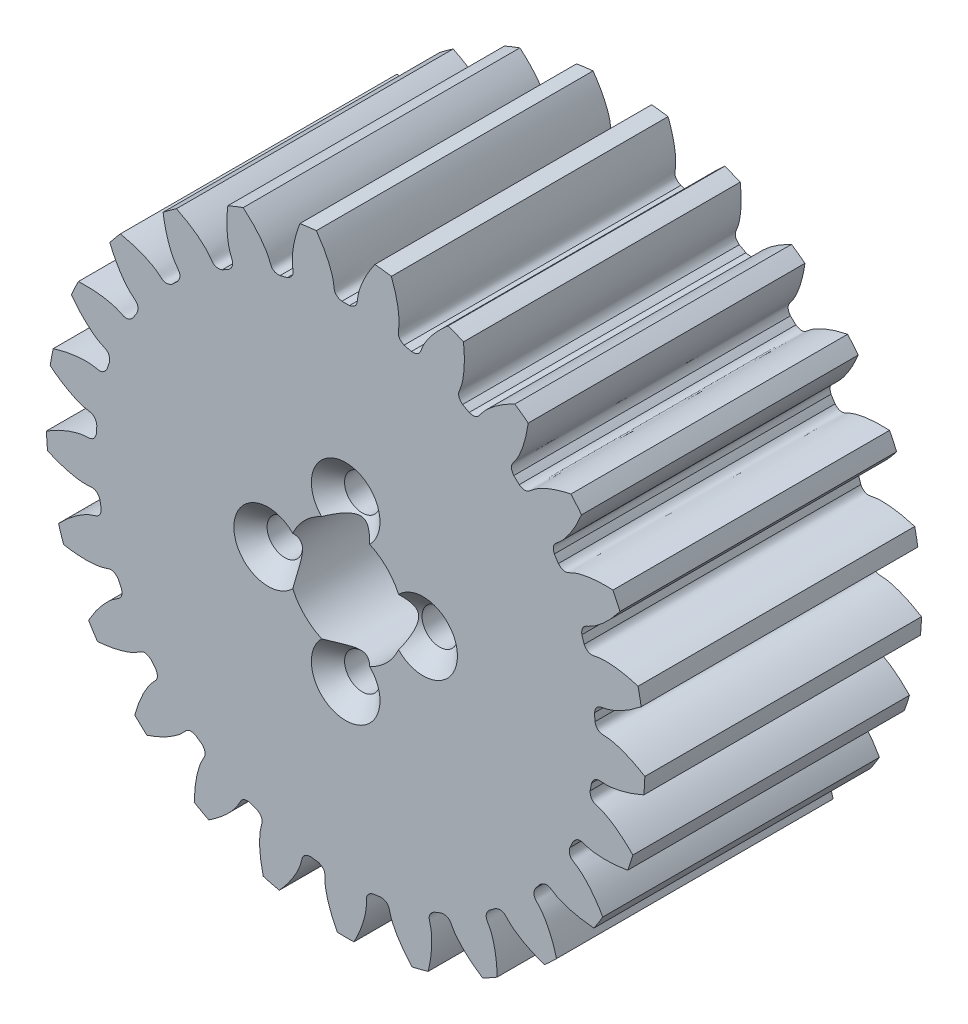
SolidWorks part; units mm, degrees
ref_plane "前视基准面" through (0, 0, 0) normal (0, 0, 1) x (1, 0, 0)
ref_plane "上视基准面" through (0, 0, 0) normal (0, 1, 0) x (1, 0, 0)
ref_plane "右视基准面" through (0, 0, 0) normal (1, 0, 0) x (0, 0, -1)
sketch "草图1" plane through (0, 0, 0) normal (0, 0, 1) x (1, 0, 0)
  circle A0 centre (0, 0) radius 27
extrude "凸台-拉伸1" add sketch "草图1" along normal blind 25
ref_axis "基准轴1" through (0, 0, 25) along (0, 0, -1)
sketch "草图2" plane through (0, 0, 0) normal (0, 0, 1) x (1, 0, 0)
  line L0 (0, 0) -> (0, 27) construction
  circle A0 centre (0, 0) radius 27 construction
  arc A1 (0.3441, 22.4974) -> (-0.3441, 22.4974) centre (0, 0) ccw
  arc A2 (6.4105, 30.6297) -> (-6.4105, 30.6297) centre (0, 0) ccw
  spline S0 degree 3 poles (0.3441, 22.4974) (1.1467, 22.6702) (1.071, 23.1545) (1.1484, 23.6361) (1.1592, 23.6962) (1.1732, 23.7653) (1.1905, 23.8433) (1.2116, 23.93) (1.2368, 24.0254) (1.2665, 24.1293) (1.301, 24.2416) (1.3407, 24.3621) (1.3859, 24.4906) (1.437, 24.6271) (1.4943, 24.7712) (1.5581, 24.9227) (1.6287, 25.0816) (1.7064, 25.2475) (1.7916, 25.4203) (1.8846, 25.5997) (1.9857, 25.7854) (2.095, 25.9773) (2.2131, 26.175) (2.34, 26.3782) (2.4761, 26.5868) (2.6216, 26.8004) (2.7768, 27.0186) (2.9419, 27.2413) (3.1172, 27.468) (3.303, 27.6986) (3.4993, 27.9325) (3.7064, 28.1696) (3.9246, 28.4094) (4.1539, 28.6517) (4.3947, 28.896) (4.647, 29.142) (4.9111, 29.3893) (5.187, 29.6376) (5.475, 29.8865) (5.8799, 30.2225) (6.1949, 30.4682) (6.4105, 30.6297) knots 0 0 0 0 0.130741 0.135745 0.141658 0.148481 0.156214 0.164857 0.174409 0.184871 0.196243 0.208524 0.221715 0.235816 0.250827 0.266748 0.283578 0.301318 0.319968 0.339527 0.359996 0.381375 0.403664 0.426862 0.450971 0.475988 0.501916 0.528753 0.556501 0.585157 0.614724 0.6452 0.676587 0.708882 0.742088 0.776203 0.811228 0.847163 0.884008 0.921762 1 1 1 1
  spline S1 degree 3 poles (-0.3441, 22.4974) (-1.1467, 22.6702) (-1.071, 23.1545) (-1.1484, 23.6361) (-1.1592, 23.6962) (-1.1732, 23.7653) (-1.1905, 23.8433) (-1.2116, 23.93) (-1.2368, 24.0254) (-1.2665, 24.1293) (-1.301, 24.2416) (-1.3407, 24.3621) (-1.3859, 24.4906) (-1.437, 24.6271) (-1.4943, 24.7712) (-1.5581, 24.9227) (-1.6287, 25.0816) (-1.7064, 25.2475) (-1.7916, 25.4203) (-1.8846, 25.5997) (-1.9857, 25.7854) (-2.095, 25.9773) (-2.2131, 26.175) (-2.34, 26.3782) (-2.4761, 26.5868) (-2.6216, 26.8004) (-2.7768, 27.0186) (-2.9419, 27.2413) (-3.1172, 27.468) (-3.303, 27.6986) (-3.4993, 27.9325) (-3.7064, 28.1696) (-3.9246, 28.4094) (-4.1539, 28.6517) (-4.3947, 28.896) (-4.647, 29.142) (-4.9111, 29.3893) (-5.187, 29.6376) (-5.475, 29.8865) (-5.8799, 30.2225) (-6.1949, 30.4682) (-6.4105, 30.6297) knots 0 0 0 0 0.130741 0.135745 0.141658 0.148481 0.156214 0.164857 0.174409 0.184871 0.196243 0.208524 0.221715 0.235816 0.250827 0.266748 0.283578 0.301318 0.319968 0.339527 0.359996 0.381375 0.403664 0.426862 0.450971 0.475988 0.501916 0.528753 0.556501 0.585157 0.614724 0.6452 0.676587 0.708882 0.742088 0.776203 0.811228 0.847163 0.884008 0.921762 1 1 1 1
extrude "切除-拉伸1" cut sketch "草图2" along normal through all
pattern_circular "阵列(圆周)1" count 25 every 14.4 about axis through (0, 0, 25) along (0, 0, -1) of "切除-拉伸1"
sketch "草图3" plane through (0, 0, 0) normal (0, 0, 1) x (1, 0, 0)
  circle A0 centre (0, 0) radius 25 construction
  dimension "Dn" = 50
sketch "草图4" plane through (0, 0, 25) normal (0, 0, 1) x (1, 0, 0)
  circle A0 centre (0, 0) radius 5.25
  dimension "D1" = 10.5
extrude "切除-拉伸2" cut sketch "草图4" against normal through all
sketch "草图5" plane through (0, 0, 25) normal (0, 0, 1) x (1, 0, 0)
  circle A0 centre (0, 0) radius 7 construction
  circle A1 centre (0, 7) radius 1.6
  dimension "D1" = 14
  dimension "D2" = 3.2
extrude "切除-拉伸3" cut sketch "草图5" against normal through all
chamfer "倒角1" distance 1.5 angle 45 1 edges at (1.6, 7, 25)
pattern_circular "阵列(圆周)2" count 4 over 360 about axis through (0, 0, 25) along (0, 0, 1) of "切除-拉伸3", "倒角1"
sketch "草图6" plane through (0, 0, 25) normal (0, 0, 1) x (1, 0, 0)
  arc A100 (-13.6829, -23.3341) -> (-12.37, -24.0559) centre (0, 0) ccw
  arc A101 (-8.6156, -20.8392) -> (-7.9849, -21.0889) centre (0, 0) ccw
  arc A102 (-7.45, -26.0038) -> (-5.9989, -26.3764) centre (0, 0) ccw
  arc A103 (-3.1624, -22.3272) -> (-2.4895, -22.4122) centre (0, 0) ccw
  arc A104 (-0.7491, -27.0396) -> (0.7491, -27.0396) centre (0, 0) ccw
  arc A105 (2.4895, -22.4122) -> (3.1624, -22.3272) centre (0, 0) ccw
  arc A106 (5.9989, -26.3764) -> (7.45, -26.0038) centre (0, 0) ccw
  arc A107 (7.9849, -21.0889) -> (8.6156, -20.8392) centre (0, 0) ccw
  arc A108 (12.37, -24.0559) -> (13.6829, -23.3341) centre (0, 0) ccw
  arc A109 (12.9787, -18.4406) -> (13.5274, -18.0419) centre (0, 0) ccw
  arc A110 (17.9638, -20.2238) -> (19.056, -19.1983) centre (0, 0) ccw
  arc A111 (17.1569, -14.6336) -> (17.5893, -14.111) centre (0, 0) ccw
  arc A112 (22.4289, -15.121) -> (23.2317, -13.8561) centre (0, 0) ccw
  arc A113 (20.2571, -9.9071) -> (20.5459, -9.2934) centre (0, 0) ccw
  arc A114 (25.4847, -9.0681) -> (25.9477, -7.6433) centre (0, 0) ccw
  arc A115 (22.0845, -4.5581) -> (22.2116, -3.8918) centre (0, 0) ccw
  arc A116 (26.9392, -2.4454) -> (27.0333, -0.9502) centre (0, 0) ccw
  arc A117 (22.5243, 1.0773) -> (22.4817, 1.7542) centre (0, 0) ccw
  arc A118 (26.701, 4.3309) -> (26.4203, 5.8025) centre (0, 0) ccw
  arc A119 (21.5487, 6.645) -> (21.3391, 7.2901) centre (0, 0) ccw
  arc A120 (24.7851, 10.8351) -> (24.1472, 12.1907) centre (0, 0) ccw
  arc A121 (19.2192, 11.7952) -> (18.8557, 12.3679) centre (0, 0) ccw
  arc A122 (21.3119, 16.6585) -> (20.3569, 17.8129) centre (0, 0) ccw
  arc A123 (15.682, 16.2042) -> (15.1876, 16.6685) centre (0, 0) ccw
  arc A124 (16.4995, 21.4352) -> (15.2875, 22.3158) centre (0, 0) ccw
  arc A125 (11.1595, 19.5951) -> (10.5651, 19.9219) centre (0, 0) ccw
  arc A126 (10.6504, 24.8651) -> (9.2575, 25.4166) centre (0, 0) ccw
  arc A127 (5.9358, 21.7547) -> (5.2788, 21.9234) centre (0, 0) ccw
  arc A128 (4.1321, 26.7325) -> (2.6458, 26.9203) centre (0, 0) ccw
  arc A129 (0.3391, 22.5474) -> (-0.3391, 22.5474) centre (0, 0) ccw
  arc A130 (-2.6458, 26.9203) -> (-4.1321, 26.7325) centre (0, 0) ccw
  arc A131 (-5.2788, 21.9234) -> (-5.9358, 21.7547) centre (0, 0) ccw
  arc A132 (-9.2575, 25.4166) -> (-10.6504, 24.8651) centre (0, 0) ccw
  arc A133 (-10.5651, 19.9219) -> (-11.1595, 19.5951) centre (0, 0) ccw
  arc A134 (-15.2875, 22.3158) -> (-16.4995, 21.4352) centre (0, 0) ccw
  arc A135 (-15.1876, 16.6685) -> (-15.682, 16.2042) centre (0, 0) ccw
  arc A136 (-20.3569, 17.8129) -> (-21.3119, 16.6585) centre (0, 0) ccw
  arc A137 (-18.8557, 12.3679) -> (-19.2192, 11.7952) centre (0, 0) ccw
  arc A138 (-24.1472, 12.1907) -> (-24.7851, 10.8351) centre (0, 0) ccw
  arc A139 (-21.3391, 7.2901) -> (-21.5487, 6.645) centre (0, 0) ccw
  arc A140 (-26.4203, 5.8025) -> (-26.701, 4.3309) centre (0, 0) ccw
  arc A141 (-22.4817, 1.7542) -> (-22.5243, 1.0773) centre (0, 0) ccw
  arc A142 (-27.0333, -0.9502) -> (-26.9392, -2.4454) centre (0, 0) ccw
  arc A143 (-22.2116, -3.8918) -> (-22.0845, -4.5581) centre (0, 0) ccw
  arc A144 (-25.9477, -7.6433) -> (-25.4847, -9.0681) centre (0, 0) ccw
  arc A145 (-20.5459, -9.2934) -> (-20.2571, -9.9071) centre (0, 0) ccw
  arc A146 (-23.2317, -13.8561) -> (-22.4289, -15.121) centre (0, 0) ccw
  arc A147 (-17.5893, -14.111) -> (-17.1569, -14.6336) centre (0, 0) ccw
  arc A148 (-19.056, -19.1983) -> (-17.9638, -20.2238) centre (0, 0) ccw
  arc A149 (-13.5274, -18.0419) -> (-12.9787, -18.4406) centre (0, 0) ccw
  arc A150 (-13.6829, -23.3341) -> (-12.37, -24.0559) centre (0, 0) ccw
  arc A151 (-8.6156, -20.8392) -> (-7.9849, -21.0889) centre (0, 0) ccw
  arc A152 (-7.45, -26.0038) -> (-5.9989, -26.3764) centre (0, 0) ccw
  arc A153 (-3.1624, -22.3272) -> (-2.4895, -22.4122) centre (0, 0) ccw
  arc A154 (-0.7491, -27.0396) -> (0.7491, -27.0396) centre (0, 0) ccw
  arc A155 (2.4895, -22.4122) -> (3.1624, -22.3272) centre (0, 0) ccw
  arc A156 (5.9989, -26.3764) -> (7.45, -26.0038) centre (0, 0) ccw
  arc A157 (7.9849, -21.0889) -> (8.6156, -20.8392) centre (0, 0) ccw
  arc A158 (12.37, -24.0559) -> (13.6829, -23.3341) centre (0, 0) ccw
  arc A159 (12.9787, -18.4406) -> (13.5274, -18.0419) centre (0, 0) ccw
  arc A160 (17.9638, -20.2238) -> (19.056, -19.1983) centre (0, 0) ccw
  arc A161 (17.1569, -14.6336) -> (17.5893, -14.111) centre (0, 0) ccw
  arc A162 (22.4289, -15.121) -> (23.2317, -13.8561) centre (0, 0) ccw
  arc A163 (20.2571, -9.9071) -> (20.5459, -9.2934) centre (0, 0) ccw
  arc A164 (25.4847, -9.0681) -> (25.9477, -7.6433) centre (0, 0) ccw
  arc A165 (22.0845, -4.5581) -> (22.2116, -3.8918) centre (0, 0) ccw
  arc A166 (26.9392, -2.4454) -> (27.0333, -0.9502) centre (0, 0) ccw
  arc A167 (22.5243, 1.0773) -> (22.4817, 1.7542) centre (0, 0) ccw
  arc A168 (26.701, 4.3309) -> (26.4203, 5.8025) centre (0, 0) ccw
  arc A169 (21.5487, 6.645) -> (21.3391, 7.2901) centre (0, 0) ccw
  arc A170 (24.7851, 10.8351) -> (24.1472, 12.1907) centre (0, 0) ccw
  arc A171 (19.2192, 11.7952) -> (18.8557, 12.3679) centre (0, 0) ccw
  arc A172 (21.3119, 16.6585) -> (20.3569, 17.8129) centre (0, 0) ccw
  arc A173 (15.682, 16.2042) -> (15.1876, 16.6685) centre (0, 0) ccw
  arc A174 (16.4995, 21.4352) -> (15.2875, 22.3158) centre (0, 0) ccw
  arc A175 (11.1595, 19.5951) -> (10.5651, 19.9219) centre (0, 0) ccw
  arc A176 (10.6504, 24.8651) -> (9.2575, 25.4166) centre (0, 0) ccw
  arc A177 (5.9358, 21.7547) -> (5.2788, 21.9234) centre (0, 0) ccw
  arc A178 (4.1321, 26.7325) -> (2.6458, 26.9203) centre (0, 0) ccw
  arc A179 (0.3391, 22.5474) -> (-0.3391, 22.5474) centre (0, 0) ccw
  arc A180 (-2.6458, 26.9203) -> (-4.1321, 26.7325) centre (0, 0) ccw
  arc A181 (-5.2788, 21.9234) -> (-5.9358, 21.7547) centre (0, 0) ccw
  arc A182 (-9.2575, 25.4166) -> (-10.6504, 24.8651) centre (0, 0) ccw
  arc A183 (-10.5651, 19.9219) -> (-11.1595, 19.5951) centre (0, 0) ccw
  arc A184 (-15.2875, 22.3158) -> (-16.4995, 21.4352) centre (0, 0) ccw
  arc A185 (-15.1876, 16.6685) -> (-15.682, 16.2042) centre (0, 0) ccw
  arc A186 (-20.3569, 17.8129) -> (-21.3119, 16.6585) centre (0, 0) ccw
  arc A187 (-18.8557, 12.3679) -> (-19.2192, 11.7952) centre (0, 0) ccw
  arc A188 (-24.1472, 12.1907) -> (-24.7851, 10.8351) centre (0, 0) ccw
  arc A189 (-21.3391, 7.2901) -> (-21.5487, 6.645) centre (0, 0) ccw
  arc A190 (-26.4203, 5.8025) -> (-26.701, 4.3309) centre (0, 0) ccw
  arc A191 (-22.4817, 1.7542) -> (-22.5243, 1.0773) centre (0, 0) ccw
  arc A192 (-27.0333, -0.9502) -> (-26.9392, -2.4454) centre (0, 0) ccw
  arc A193 (-22.2116, -3.8918) -> (-22.0845, -4.5581) centre (0, 0) ccw
  arc A194 (-25.9477, -7.6433) -> (-25.4847, -9.0681) centre (0, 0) ccw
  arc A195 (-20.5459, -9.2934) -> (-20.2571, -9.9071) centre (0, 0) ccw
  arc A196 (-23.2317, -13.8561) -> (-22.4289, -15.121) centre (0, 0) ccw
  arc A197 (-17.5893, -14.111) -> (-17.1569, -14.6336) centre (0, 0) ccw
  arc A198 (-19.056, -19.1983) -> (-17.9638, -20.2238) centre (0, 0) ccw
  arc A199 (-13.5274, -18.0419) -> (-12.9787, -18.4406) centre (0, 0) ccw
  arc A200 (-13.6325, -23.3057) -> (-12.373, -23.9981) centre (0, 0) ccw
  arc A201 (-13.502, -17.9985) -> (-12.9452, -18.403) centre (0, 0) ccw
  arc A202 (-19.0001, -19.1833) -> (-17.9524, -20.1671) centre (0, 0) ccw
  arc A203 (-17.5539, -14.0752) -> (-17.1152, -14.6055) centre (0, 0) ccw
  arc A204 (-23.1738, -13.8554) -> (-22.4037, -15.0689) centre (0, 0) ccw
  arc A205 (-20.5027, -9.2675) -> (-20.2097, -9.8903) centre (0, 0) ccw
  arc A206 (-25.8915, -7.6571) -> (-25.4474, -9.0239) centre (0, 0) ccw
  arc A207 (-22.1634, -3.8776) -> (-22.0344, -4.5536) centre (0, 0) ccw
  arc A208 (-26.9823, -0.9775) -> (-26.8921, -2.4119) centre (0, 0) ccw
  arc A209 (-22.4314, 1.7561) -> (-22.4746, 1.0692) centre (0, 0) ccw
  arc A210 (-26.3777, 5.7634) -> (-26.647, 4.3516) centre (0, 0) ccw
  arc A211 (-21.2899, 7.2793) -> (-21.5026, 6.6248) centre (0, 0) ccw
  arc A212 (-24.1157, 12.1422) -> (-24.7276, 10.8417) centre (0, 0) ccw
  arc A213 (-18.8108, 12.3452) -> (-19.1795, 11.7641) centre (0, 0) ccw
  arc A214 (-20.3384, 17.7581) -> (-21.2546, 16.6506) centre (0, 0) ccw
  arc A215 (-15.1497, 16.6354) -> (-15.6514, 16.1643) centre (0, 0) ccw
  arc A216 (-15.2832, 22.2581) -> (-16.446, 21.4133) centre (0, 0) ccw
  arc A217 (-10.5366, 19.8804) -> (-11.1397, 19.5488) centre (0, 0) ccw
  arc A218 (-9.2677, 25.3596) -> (-10.604, 24.8305) centre (0, 0) ccw
  arc A219 (-5.2616, 21.8762) -> (-5.9282, 21.705) centre (0, 0) ccw
  arc A220 (-2.6698, 26.8677) -> (-4.0958, 26.6875) centre (0, 0) ccw
  arc A221 (0.3441, 22.4974) -> (-0.3441, 22.4974) centre (0, 0) ccw
  arc A222 (4.0958, 26.6875) -> (2.6698, 26.8677) centre (0, 0) ccw
  arc A223 (5.9282, 21.705) -> (5.2616, 21.8762) centre (0, 0) ccw
  arc A224 (10.604, 24.8305) -> (9.2677, 25.3596) centre (0, 0) ccw
  arc A225 (11.1397, 19.5488) -> (10.5366, 19.8804) centre (0, 0) ccw
  arc A226 (16.446, 21.4133) -> (15.2832, 22.2581) centre (0, 0) ccw
  arc A227 (15.6514, 16.1643) -> (15.1497, 16.6354) centre (0, 0) ccw
  arc A228 (21.2546, 16.6506) -> (20.3384, 17.7581) centre (0, 0) ccw
  arc A229 (19.1795, 11.7641) -> (18.8108, 12.3452) centre (0, 0) ccw
  arc A230 (24.7276, 10.8417) -> (24.1157, 12.1422) centre (0, 0) ccw
  arc A231 (21.5026, 6.6248) -> (21.2899, 7.2793) centre (0, 0) ccw
  arc A232 (26.647, 4.3516) -> (26.3777, 5.7634) centre (0, 0) ccw
  arc A233 (22.4746, 1.0692) -> (22.4314, 1.7561) centre (0, 0) ccw
  arc A234 (26.8921, -2.4119) -> (26.9823, -0.9775) centre (0, 0) ccw
  arc A235 (22.0344, -4.5536) -> (22.1634, -3.8776) centre (0, 0) ccw
  arc A236 (25.4474, -9.0239) -> (25.8915, -7.6571) centre (0, 0) ccw
  arc A237 (20.2097, -9.8903) -> (20.5027, -9.2675) centre (0, 0) ccw
  arc A238 (22.4037, -15.0689) -> (23.1738, -13.8554) centre (0, 0) ccw
  arc A239 (17.1152, -14.6055) -> (17.5539, -14.0752) centre (0, 0) ccw
  arc A240 (17.9524, -20.1671) -> (19.0001, -19.1833) centre (0, 0) ccw
  arc A241 (12.9452, -18.403) -> (13.502, -17.9985) centre (0, 0) ccw
  arc A242 (12.373, -23.9981) -> (13.6325, -23.3057) centre (0, 0) ccw
  arc A243 (7.9619, -21.0442) -> (8.6018, -20.7908) centre (0, 0) ccw
  arc A244 (6.0162, -26.3212) -> (7.4083, -25.9638) centre (0, 0) ccw
  arc A245 (2.4783, -22.3631) -> (3.1611, -22.2768) centre (0, 0) ccw
  arc A246 (-0.7186, -26.9904) -> (0.7186, -26.9904) centre (0, 0) ccw
  arc A247 (-3.1611, -22.2768) -> (-2.4783, -22.3631) centre (0, 0) ccw
  arc A248 (-7.4083, -25.9638) -> (-6.0162, -26.3212) centre (0, 0) ccw
  arc A249 (-8.6018, -20.7908) -> (-7.9619, -21.0442) centre (0, 0) ccw
  arc A250 (-13.6325, -23.3057) -> (-12.373, -23.9981) centre (0, 0) ccw
  arc A251 (-13.502, -17.9985) -> (-12.9452, -18.403) centre (0, 0) ccw
  arc A252 (-19.0001, -19.1833) -> (-17.9524, -20.1671) centre (0, 0) ccw
  arc A253 (-17.5539, -14.0752) -> (-17.1152, -14.6055) centre (0, 0) ccw
  arc A254 (-23.1738, -13.8554) -> (-22.4037, -15.0689) centre (0, 0) ccw
  arc A255 (-20.5027, -9.2675) -> (-20.2097, -9.8903) centre (0, 0) ccw
  arc A256 (-25.8915, -7.6571) -> (-25.4474, -9.0239) centre (0, 0) ccw
  arc A257 (-22.1634, -3.8776) -> (-22.0344, -4.5536) centre (0, 0) ccw
  arc A258 (-26.9823, -0.9775) -> (-26.8921, -2.4119) centre (0, 0) ccw
  arc A259 (-22.4314, 1.7561) -> (-22.4746, 1.0692) centre (0, 0) ccw
  arc A260 (-26.3777, 5.7634) -> (-26.647, 4.3516) centre (0, 0) ccw
  arc A261 (-21.2899, 7.2793) -> (-21.5026, 6.6248) centre (0, 0) ccw
  arc A262 (-24.1157, 12.1422) -> (-24.7276, 10.8417) centre (0, 0) ccw
  arc A263 (-18.8108, 12.3452) -> (-19.1795, 11.7641) centre (0, 0) ccw
  arc A264 (-20.3384, 17.7581) -> (-21.2546, 16.6506) centre (0, 0) ccw
  arc A265 (-15.1497, 16.6354) -> (-15.6514, 16.1643) centre (0, 0) ccw
  arc A266 (-15.2832, 22.2581) -> (-16.446, 21.4133) centre (0, 0) ccw
  arc A267 (-10.5366, 19.8804) -> (-11.1397, 19.5488) centre (0, 0) ccw
  arc A268 (-9.2677, 25.3596) -> (-10.604, 24.8305) centre (0, 0) ccw
  arc A269 (-5.2616, 21.8762) -> (-5.9282, 21.705) centre (0, 0) ccw
  arc A270 (-2.6698, 26.8677) -> (-4.0958, 26.6875) centre (0, 0) ccw
  arc A271 (0.3441, 22.4974) -> (-0.3441, 22.4974) centre (0, 0) ccw
  arc A272 (4.0958, 26.6875) -> (2.6698, 26.8677) centre (0, 0) ccw
  arc A273 (5.9282, 21.705) -> (5.2616, 21.8762) centre (0, 0) ccw
  arc A274 (10.604, 24.8305) -> (9.2677, 25.3596) centre (0, 0) ccw
  arc A275 (11.1397, 19.5488) -> (10.5366, 19.8804) centre (0, 0) ccw
  arc A276 (16.446, 21.4133) -> (15.2832, 22.2581) centre (0, 0) ccw
  arc A277 (15.6514, 16.1643) -> (15.1497, 16.6354) centre (0, 0) ccw
  arc A278 (21.2546, 16.6506) -> (20.3384, 17.7581) centre (0, 0) ccw
  arc A279 (19.1795, 11.7641) -> (18.8108, 12.3452) centre (0, 0) ccw
  arc A280 (24.7276, 10.8417) -> (24.1157, 12.1422) centre (0, 0) ccw
  arc A281 (21.5026, 6.6248) -> (21.2899, 7.2793) centre (0, 0) ccw
  arc A282 (26.647, 4.3516) -> (26.3777, 5.7634) centre (0, 0) ccw
  arc A283 (22.4746, 1.0692) -> (22.4314, 1.7561) centre (0, 0) ccw
  arc A284 (26.8921, -2.4119) -> (26.9823, -0.9775) centre (0, 0) ccw
  arc A285 (22.0344, -4.5536) -> (22.1634, -3.8776) centre (0, 0) ccw
  arc A286 (25.4474, -9.0239) -> (25.8915, -7.6571) centre (0, 0) ccw
  arc A287 (20.2097, -9.8903) -> (20.5027, -9.2675) centre (0, 0) ccw
  arc A288 (22.4037, -15.0689) -> (23.1738, -13.8554) centre (0, 0) ccw
  arc A289 (17.1152, -14.6055) -> (17.5539, -14.0752) centre (0, 0) ccw
  arc A290 (17.9524, -20.1671) -> (19.0001, -19.1833) centre (0, 0) ccw
  arc A291 (12.9452, -18.403) -> (13.502, -17.9985) centre (0, 0) ccw
  arc A292 (12.373, -23.9981) -> (13.6325, -23.3057) centre (0, 0) ccw
  arc A293 (7.9619, -21.0442) -> (8.6018, -20.7908) centre (0, 0) ccw
  arc A294 (6.0162, -26.3212) -> (7.4083, -25.9638) centre (0, 0) ccw
  arc A295 (2.4783, -22.3631) -> (3.1611, -22.2768) centre (0, 0) ccw
  arc A296 (-0.7186, -26.9904) -> (0.7186, -26.9904) centre (0, 0) ccw
  arc A297 (-3.1611, -22.2768) -> (-2.4783, -22.3631) centre (0, 0) ccw
  arc A298 (-7.4083, -25.9638) -> (-6.0162, -26.3212) centre (0, 0) ccw
  arc A299 (-8.6018, -20.7908) -> (-7.9619, -21.0442) centre (0, 0) ccw
  spline S100 degree 3 poles (3049.1861, -3975.2319) (-213.6235, 99.1827) (-42.2423, -48.411) (-11.0052, -23.0366) (-10.6894, -22.749) (-10.2507, -22.2795) (-10.1113, -22.1176) (-9.8517, -21.7789) (-9.7318, -21.6008) (-9.581, -21.3146) (-9.5327, -21.2176) (-9.4124, -21.0393) (-9.3374, -20.9581) (-9.1518, -20.8512) (-9.0432, -20.8258) (0.1997, -20.2408) (4.2343, -138.6934) (232.389, 4972.6438) knots -23.145772 -23.145772 -23.145772 -23.145772 0.25 0.25 0.5 0.5 0.625 0.625 0.75 0.75 0.8125 0.8125 0.875 0.875 0.9375 0.9375 6.256915 6.256915 6.256915 6.256915 only from (-12.37, -24.0559) to (-8.6156, -20.8392)
  spline S101 degree 3 poles (3264.1901, 3758.6253) (-99.1058, -98.017) (-13.9913, -14.6045) (-7.6626, -21.3737) (-7.6007, -21.4673) (-7.5394, -21.6749) (-7.5415, -21.7861) (-7.5768, -21.9979) (-7.6081, -22.1014) (-7.6938, -22.413) (-7.7275, -22.6232) (-7.7698, -23.0463) (-7.7789, -23.2591) (-7.7805, -23.9003) (-7.7471, -24.327) (-2.3522, -64.1521) (222.8421, -72.9742) (-4940.4924, -831.3277) knots -5.233931 -5.233931 -5.233931 -5.233931 0.0625 0.0625 0.125 0.125 0.1875 0.1875 0.25 0.25 0.375 0.375 0.5 0.5 0.75 0.75 24.115464 24.115464 24.115464 24.115464 only from (-7.9849, -21.0889) to (-7.45, -26.0038)
  spline S102 degree 3 poles (3941.9902, -3092.041) (-231.5779, 42.9407) (-28.8759, -57.3953) (-4.9305, -25.0497) (-4.6961, -24.6927) (-4.388, -24.1288) (-4.2932, -23.9373) (-4.126, -23.5447) (-4.0541, -23.3423) (-3.9793, -23.0277) (-3.9566, -22.9216) (-3.8844, -22.7191) (-3.8319, -22.6218) (-3.6788, -22.4721) (-3.5799, -22.4205) (5.2272, -19.5553) (38.5929, -133.283) (-1011.5582, 4874.2119) knots -23.145772 -23.145772 -23.145772 -23.145772 0.25 0.25 0.5 0.5 0.625 0.625 0.75 0.75 0.8125 0.8125 0.875 0.875 0.9375 0.9375 6.256915 6.256915 6.256915 6.256915 only from (-5.9989, -26.3764) to (-3.1624, -22.3272)
  spline S103 degree 3 poles (2226.9075, 4452.3123) (-71.6164, -119.5843) (-9.9197, -17.6252) (-2.1064, -22.6078) (-2.0233, -22.6831) (-1.9122, -22.8689) (-1.8866, -22.9772) (-1.8681, -23.1911) (-1.8727, -23.2991) (-1.8782, -23.6222) (-1.8586, -23.8342) (-1.7943, -24.2546) (-1.7502, -24.463) (-1.5924, -25.0843) (-1.4539, -25.4893) (13.6757, -62.7216) (233.989, -15.263) (-4578.535, -2033.8605) knots -5.233931 -5.233931 -5.233931 -5.233931 0.0625 0.0625 0.125 0.125 0.1875 0.1875 0.25 0.25 0.375 0.375 0.5 0.5 0.75 0.75 24.115464 24.115464 24.115464 24.115464 only from (-2.4895, -22.4122) to (-0.7491, -27.0396)
  spline S104 degree 3 poles (4587.1047, -2014.5657) (-234.9813, -15.9995) (-13.695, -62.7732) (1.454, -25.4889) (1.5923, -25.0848) (1.7505, -24.462) (1.7946, -24.253) (1.8589, -23.831) (1.8782, -23.6172) (1.8725, -23.2938) (1.8681, -23.1855) (1.8876, -22.9713) (1.9143, -22.864) (2.0254, -22.681) (2.1083, -22.6064) (9.9261, -17.641) (70.5266, -119.498) (-2191.9454, 4469.5153) knots -23.145772 -23.145772 -23.145772 -23.145772 0.25 0.25 0.5 0.5 0.625 0.625 0.75 0.75 0.8125 0.8125 0.875 0.875 0.9375 0.9375 6.256915 6.256915 6.256915 6.256915 only from (0.7491, -27.0396) to (2.4895, -22.4122)
  spline S105 degree 3 poles (1049.7001, 4866.2441) (-39.627, -133.6376) (-5.2249, -19.5384) (3.5821, -22.4214) (3.6813, -22.4736) (3.8351, -22.626) (3.8869, -22.7245) (3.958, -22.9271) (3.9804, -23.0328) (4.0554, -23.3472) (4.1272, -23.5477) (4.2939, -23.9388) (4.3884, -24.1297) (4.6959, -24.6923) (4.9308, -25.0501) (28.8443, -57.3501) (230.4336, 43.4072) (-3928.8913, -3108.5984) knots -5.233931 -5.233931 -5.233931 -5.233931 0.0625 0.0625 0.125 0.125 0.1875 0.1875 0.25 0.25 0.375 0.375 0.5 0.5 0.75 0.75 24.115464 24.115464 24.115464 24.115464 only from (3.1624, -22.3272) to (5.9989, -26.3764)
  spline S106 degree 3 poles (4943.9945, -810.5079) (-223.62, -73.9343) (2.3463, -64.2069) (7.7472, -24.3265) (7.7806, -23.9007) (7.7789, -23.2581) (7.7697, -23.0447) (7.7271, -22.6201) (7.6926, -22.4081) (7.6066, -22.0963) (7.5754, -21.9925) (7.541, -21.7802) (7.5402, -21.6697) (7.6023, -21.4647) (7.664, -21.3718) (14.0014, -14.6182) (98.0288, -98.2045) (-3234.6047, 3783.9826) knots -23.145772 -23.145772 -23.145772 -23.145772 0.25 0.25 0.5 0.5 0.625 0.625 0.75 0.75 0.8125 0.8125 0.875 0.875 0.9375 0.9375 6.256915 6.256915 6.256915 6.256915 only from (7.45, -26.0038) to (7.9849, -21.0889)
  spline S107 degree 3 poles (-193.4639, 4974.4119) (-5.1478, -139.2939) (-0.2017, -20.2239) (9.0455, -20.8261) (9.1546, -20.852) (9.3415, -20.9614) (9.4161, -21.0439) (9.5354, -21.2225) (9.5834, -21.3193) (9.7342, -21.6052) (9.8536, -21.7815) (10.1124, -22.1188) (10.2514, -22.2802) (10.6891, -22.7487) (11.0056, -23.0369) (42.2005, -48.3751) (212.3991, 99.35) (-3032.381, -3988.0116) knots -5.233931 -5.233931 -5.233931 -5.233931 0.0625 0.0625 0.125 0.125 0.1875 0.1875 0.25 0.25 0.375 0.375 0.5 0.5 0.75 0.75 24.115464 24.115464 24.115464 24.115464 only from (8.6156, -20.8392) to (12.37, -24.0559)
  spline S108 degree 3 poles (4990.2349, 444.4771) (-198.2079, -127.2236) (18.2402, -61.6063) (13.5535, -21.6356) (13.48, -21.2149) (13.3186, -20.5929) (13.2566, -20.3884) (13.1097, -19.9878) (13.0236, -19.7911) (12.8628, -19.5105) (12.8067, -19.4176) (12.7206, -19.2206) (12.6923, -19.1137) (12.7015, -18.8997) (12.7382, -18.7944) (17.1969, -10.6769) (119.3715, -70.7404) (-4074.0218, 2860.6883) knots -23.145772 -23.145772 -23.145772 -23.145772 0.25 0.25 0.5 0.5 0.625 0.625 0.75 0.75 0.8125 0.8125 0.875 0.875 0.9375 0.9375 6.256915 6.256915 6.256915 6.256915 only from (13.6829, -23.3341) to (12.9787, -18.4406)
  spline S109 degree 3 poles (-1424.4718, 4770.0191) (29.655, -136.198) (4.8341, -19.6387) (13.9406, -17.9223) (14.0527, -17.9203) (14.2609, -17.9797) (14.3537, -18.0411) (14.5136, -18.1844) (14.5842, -18.2662) (14.8014, -18.5056) (14.9608, -18.6467) (15.2954, -18.9091) (15.4702, -19.0308) (16.0106, -19.3757) (16.3888, -19.5762) (52.9051, -36.3605) (181.0189, 149.0503) (-1945.335, -4616.8434) knots -5.233931 -5.233931 -5.233931 -5.233931 0.0625 0.0625 0.125 0.125 0.1875 0.1875 0.25 0.25 0.375 0.375 0.5 0.5 0.75 0.75 24.115464 24.115464 24.115464 24.115464 only from (13.5274, -18.0419) to (17.9638, -20.2238)
  spline S110 degree 3 poles (4722.9205, 1671.534) (-160.3416, -172.5189) (32.988, -55.1346) (18.5083, -17.5853) (18.3324, -17.196) (18.0214, -16.6337) (17.9105, -16.4511) (17.6686, -16.0996) (17.5363, -15.9305) (17.3107, -15.6987) (17.2333, -15.6227) (17.101, -15.4532) (17.047, -15.3568) (17.0027, -15.1472) (17.012, -15.0361) (19.3119, -6.0648) (133.2137, -38.8315) (-4657.4532, 1757.6465) knots -23.145772 -23.145772 -23.145772 -23.145772 0.25 0.25 0.5 0.5 0.625 0.625 0.75 0.75 0.8125 0.8125 0.875 0.875 0.9375 0.9375 6.256915 6.256915 6.256915 6.256915 only from (19.056, -19.1983) to (17.1569, -14.6336)
  spline S111 degree 3 poles (-2565.9749, 4265.9084) (62.5944, -124.5442) (9.5662, -17.8195) (17.9597, -13.8924) (18.0678, -13.8625) (18.2842, -13.8683) (18.3894, -13.9047) (18.5799, -14.0037) (18.6686, -14.0654) (18.9385, -14.2432) (19.1281, -14.3403) (19.5174, -14.5112) (19.7169, -14.5857) (20.3262, -14.7853) (20.7423, -14.8854) (60.2854, -22.0612) (138.2645, 189.3851) (-736.0565, -4955.5819) knots -5.233931 -5.233931 -5.233931 -5.233931 0.0625 0.0625 0.125 0.125 0.1875 0.1875 0.25 0.25 0.375 0.375 0.5 0.5 0.75 0.75 24.115464 24.115464 24.115464 24.115464 only from (17.5893, -14.111) to (22.4289, -15.121)
  spline S112 degree 3 poles (4158.8477, 2793.5623) (-112.4005, -206.9742) (45.663, -45.1987) (22.3001, -12.43) (22.033, -12.0967) (21.5919, -11.6294) (21.4391, -11.4801) (21.1173, -11.1998) (20.9471, -11.0689) (20.671, -10.9005) (20.5771, -10.8461) (20.4068, -10.7149) (20.3305, -10.6349) (20.2354, -10.443) (20.2169, -10.333) (20.2134, -1.0716) (138.6855, -4.4826) (-4948.2396, 544.1653) knots -23.145772 -23.145772 -23.145772 -23.145772 0.25 0.25 0.5 0.5 0.625 0.625 0.75 0.75 0.8125 0.8125 0.875 0.875 0.9375 0.9375 6.256915 6.256915 6.256915 6.256915 only from (23.2317, -13.8561) to (20.2571, -9.9071)
  spline S113 degree 3 poles (-3546.2484, 3493.755) (91.6007, -105.0648) (13.6972, -14.8807) (20.8504, -8.9895) (20.9476, -8.9337) (21.1587, -8.8855) (21.2696, -8.8946) (21.4788, -8.9431) (21.5801, -8.9808) (21.8857, -9.0859) (22.0934, -9.1328) (22.513, -9.2016) (22.7248, -9.224) (23.3646, -9.2659) (23.7925, -9.2593) (63.8778, -6.3757) (86.8225, 217.8202) (519.4712, -4982.943) knots -5.233931 -5.233931 -5.233931 -5.233931 0.0625 0.0625 0.125 0.125 0.1875 0.1875 0.25 0.25 0.375 0.375 0.5 0.5 0.75 0.75 24.115464 24.115464 24.115464 24.115464 only from (20.5459, -9.2934) to (25.4847, -9.0681)
  spline S114 degree 3 poles (3333.4592, 3740.0608) (-57.3968, -228.4246) (55.4689, -32.4228) (24.6907, -6.4937) (24.3491, -6.2373) (23.8056, -5.8944) (23.6205, -5.7878) (23.2391, -5.5962) (23.0417, -5.5118) (22.7324, -5.4173) (22.628, -5.388) (22.4304, -5.3033) (22.3365, -5.2448) (22.1968, -5.0825) (22.1514, -4.9807) (19.8449, 3.989) (135.4433, 30.1479) (-4928.11, -703.5078) knots -23.145772 -23.145772 -23.145772 -23.145772 0.25 0.25 0.5 0.5 0.625 0.625 0.75 0.75 0.8125 0.8125 0.875 0.875 0.9375 0.9375 6.256915 6.256915 6.256915 6.256915 only from (25.9477, -7.6433) to (22.0845, -4.5581)
  spline S115 degree 3 poles (-4303.698, 2502.0762) (114.8515, -78.9838) (16.9675, -11.0068) (22.4309, -3.5218) (22.5113, -3.4436) (22.7037, -3.3444) (22.8134, -3.3256) (23.0281, -3.3206) (23.1355, -3.3319) (23.4577, -3.3577) (23.6705, -3.3515) (24.094, -3.3137) (24.3048, -3.2828) (24.9349, -3.1643) (25.3477, -3.0515) (63.4566, 9.7104) (29.9252, 232.5689) (1742.3586, -4697.2074) knots -5.233931 -5.233931 -5.233931 -5.233931 0.0625 0.0625 0.125 0.125 0.1875 0.1875 0.25 0.25 0.375 0.375 0.5 0.5 0.75 0.75 24.115464 24.115464 24.115464 24.115464 only from (22.2116, -3.8918) to (26.9392, -2.4454)
  spline S116 degree 3 poles (2298.6171, 4451.5575) (1.2133, -235.5223) (61.7895, -17.6096) (25.5299, -0.1493) (25.1352, 0.014) (24.5236, 0.211) (24.3178, 0.2683) (23.9007, 0.3589) (23.6885, 0.3916) (23.3655, 0.4062) (23.257, 0.4086) (23.0445, 0.4415) (22.9391, 0.4748) (22.7634, 0.5973) (22.6942, 0.6847) (18.2294, 8.7989) (123.6906, 62.8841) (-4598.3291, -1906.9769) knots -23.145772 -23.145772 -23.145772 -23.145772 0.25 0.25 0.5 0.5 0.625 0.625 0.75 0.75 0.8125 0.8125 0.875 0.875 0.9375 0.9375 6.256915 6.256915 6.256915 6.256915 only from (27.0333, -0.9502) to (22.5243, 1.0773)
  spline S117 degree 3 poles (-4790.7305, 1353.1827) (130.8857, -47.94) (19.1717, -6.4414) (22.6021, 2.1672) (22.6604, 2.263) (22.8221, 2.4068) (22.9237, 2.4524) (23.1304, 2.5106) (23.2373, 2.5263) (23.5558, 2.5814) (23.7603, 2.6405) (24.1612, 2.7823) (24.3576, 2.8647) (24.9384, 3.1362) (25.3103, 3.3481) (59.0481, 25.1863) (-28.8525, 232.7044) (2855.7672, -4116.3291) knots -5.233931 -5.233931 -5.233931 -5.233931 0.0625 0.0625 0.125 0.125 0.1875 0.1875 0.25 0.25 0.375 0.375 0.5 0.5 0.75 0.75 24.115464 24.115464 24.115464 24.115464 only from (22.4817, 1.7542) to (26.701, 4.3309)
  spline S118 degree 3 poles (1119.3445, 4883.3464) (59.7472, -227.8212) (64.2276, -1.6899) (24.765, 6.2044) (24.3421, 6.2645) (23.7007, 6.3032) (23.4871, 6.3074) (23.0606, 6.2915) (22.8469, 6.2704) (22.5304, 6.2042) (22.4248, 6.1795) (22.2108, 6.1586) (22.1004, 6.1646) (21.8997, 6.2395) (21.8109, 6.307) (15.4685, 13.0559) (104.166, 91.6691) (-3979.6182, -2990.6237) knots -23.145772 -23.145772 -23.145772 -23.145772 0.25 0.25 0.5 0.5 0.625 0.625 0.75 0.75 0.8125 0.8125 0.875 0.875 0.9375 0.9375 6.256915 6.256915 6.256915 6.256915 only from (26.4203, 5.8025) to (21.5487, 6.645)
  spline S119 degree 3 poles (-4976.7437, 119.2638) (138.6958, -13.8839) (20.1713, -1.4712) (21.353, 7.72) (21.3857, 7.8273) (21.5066, 8.0069) (21.5936, 8.0762) (21.7794, 8.184) (21.879, 8.2258) (22.1737, 8.3584) (22.3572, 8.4665) (22.7102, 8.7036) (22.88, 8.8322) (23.375, 9.2396) (23.6825, 9.5373) (50.9294, 39.0797) (-85.8173, 218.2182) (3789.7374, -3276.8066) knots -5.233931 -5.233931 -5.233931 -5.233931 0.0625 0.0625 0.125 0.125 0.1875 0.1875 0.25 0.25 0.375 0.375 0.5 0.5 0.75 0.75 24.115464 24.115464 24.115464 24.115464 only from (21.3391, 7.2901) to (24.7851, 10.8351)
  spline S120 degree 3 poles (-130.2606, 5008.2968) (114.5269, -205.8052) (62.63, 14.3359) (22.444, 12.1683) (22.0194, 12.1213) (21.3885, 11.9993) (21.1806, 11.9503) (20.7715, 11.8288) (20.5698, 11.7552) (20.2796, 11.6123) (20.1835, 11.5622) (19.9814, 11.4887) (19.873, 11.4671) (19.66, 11.4897) (19.5572, 11.533) (11.7357, 16.4926) (78.0963, 114.6942) (-3110.8534, -3886.3585) knots -23.145772 -23.145772 -23.145772 -23.145772 0.25 0.25 0.5 0.5 0.625 0.625 0.75 0.75 0.8125 0.8125 0.875 0.875 0.9375 0.9375 6.256915 6.256915 6.256915 6.256915 only from (24.1472, 12.1907) to (19.2192, 11.7952)
  spline S121 degree 3 poles (-4850.0498, -1122.1489) (137.7912, 21.0445) (19.9035, 3.5914) (18.7623, 12.7878) (18.7673, 12.8998) (18.8397, 13.1038) (18.9068, 13.1926) (19.0598, 13.3432) (19.1459, 13.4085) (19.3985, 13.6102) (19.5493, 13.7605) (19.8322, 14.0779) (19.9647, 14.2447) (20.3428, 14.7624) (20.5666, 15.1273) (39.6107, 50.5176) (-137.3899, 190.0206) (4485.5845, -2231.3903) knots -5.233931 -5.233931 -5.233931 -5.233931 0.0625 0.0625 0.125 0.125 0.1875 0.1875 0.25 0.25 0.375 0.375 0.5 0.5 0.75 0.75 24.115464 24.115464 24.115464 24.115464 only from (18.8557, 12.3679) to (21.3119, 16.6585)
  spline S122 degree 3 poles (-1371.681, 4818.5574) (162.1105, -170.8578) (57.0972, 29.461) (18.7127, 17.3676) (18.3132, 17.2165) (17.7325, 16.9414) (17.5433, 16.8422) (17.1772, 16.6228) (17.0001, 16.5014) (16.7546, 16.2908) (16.674, 16.2184) (16.4965, 16.0969) (16.3969, 16.0491) (16.1849, 16.018) (16.0746, 16.0343) (7.2654, 18.893) (47.1194, 130.5126) (-2046.6221, -4537.8992) knots -23.145772 -23.145772 -23.145772 -23.145772 0.25 0.25 0.5 0.5 0.625 0.625 0.75 0.75 0.8125 0.8125 0.875 0.875 0.9375 0.9375 6.256915 6.256915 6.256915 6.256915 only from (20.3569, 17.8129) to (15.682, 16.2042)
  spline S123 degree 3 poles (-4418.6095, -2293.0529) (128.2287, 54.6506) (18.385, 8.4284) (14.9927, 17.052) (14.9696, 17.1617) (14.989, 17.3773) (15.0319, 17.48) (15.1427, 17.664) (15.2099, 17.7486) (15.4043, 18.0068) (15.513, 18.1899) (15.7081, 18.5677) (15.7949, 18.7622) (16.0324, 19.3577) (16.1585, 19.7667) (25.803, 58.7812) (-180.3297, 149.8833) (4899.5858, -1045.7676) knots -5.233931 -5.233931 -5.233931 -5.233931 0.0625 0.0625 0.125 0.125 0.1875 0.1875 0.25 0.25 0.375 0.375 0.5 0.5 0.75 0.75 24.115464 24.115464 24.115464 24.115464 only from (15.1876, 16.6685) to (16.4995, 21.4352)
  spline S124 degree 3 poles (-2526.9136, 4326.0504) (199.5081, -125.1747) (47.9767, 42.7349) (13.8057, 21.4756) (13.4563, 21.2299) (12.9622, 20.819) (12.8036, 20.6759) (12.5036, 20.3724) (12.3623, 20.2107) (12.1769, 19.9457) (12.1168, 19.8555) (11.9751, 19.6937) (11.8905, 19.6226) (11.693, 19.5398) (11.5821, 19.5282) (2.3387, 20.1063) (13.1819, 138.1304) (-853.7941, -4904.307) knots -23.145772 -23.145772 -23.145772 -23.145772 0.25 0.25 0.5 0.5 0.625 0.625 0.75 0.75 0.8125 0.8125 0.875 0.875 0.9375 0.9375 6.256915 6.256915 6.256915 6.256915 only from (15.2875, 22.3158) to (11.1595, 19.5951)
  spline S125 degree 3 poles (-3709.5317, -3319.876) (110.6091, 84.8229) (15.7114, 12.7358) (10.281, 20.2448) (10.2314, 20.3454) (10.1965, 20.559) (10.2125, 20.6692) (10.2742, 20.8749) (10.3181, 20.9736) (10.4422, 21.272) (10.502, 21.4763) (10.597, 21.8908) (10.6327, 22.1008) (10.7147, 22.7366) (10.735, 23.1642) (10.3741, 63.3515) (-211.9388, 100.3283) (5005.7282, 205.5646) knots -5.233931 -5.233931 -5.233931 -5.233931 0.0625 0.0625 0.125 0.125 0.1875 0.1875 0.25 0.25 0.375 0.375 0.5 0.5 0.75 0.75 24.115464 24.115464 24.115464 24.115464 only from (10.5651, 19.9219) to (10.6504, 24.8651)
  spline S126 degree 3 poles (-3523.371, 3561.7217) (224.3699, -71.6265) (35.8417, 53.3236) (8.0312, 24.2342) (7.7539, 23.9094) (7.3775, 23.3885) (7.2595, 23.2105) (7.0444, 22.8419) (6.9477, 22.6502) (6.834, 22.3474) (6.7982, 22.245) (6.7013, 22.0531) (6.637, 21.9631) (6.4662, 21.8338) (6.3617, 21.795) (-2.735, 20.0562) (-21.5838, 137.069) (392.681, -4962.5591) knots -23.145772 -23.145772 -23.145772 -23.145772 0.25 0.25 0.5 0.5 0.625 0.625 0.75 0.75 0.8125 0.8125 0.875 0.875 0.9375 0.9375 6.256915 6.256915 6.256915 6.256915 only from (9.2575, 25.4166) to (5.9358, 21.7547)
  spline S127 degree 3 poles (-2767.3704, -4138.099) (86.0395, 109.6654) (12.0505, 16.2429) (4.9233, 22.1655) (4.8503, 22.2506) (4.7634, 22.4489) (4.7515, 22.5595) (4.76, 22.7741) (4.778, 22.8807) (4.824, 23.2006) (4.8311, 23.4134) (4.8201, 23.8384) (4.8025, 24.0507) (4.7237, 24.687) (4.6371, 25.1061) (-5.7067, 63.9411) (-230.231, 44.4692) (4797.3422, 1443.9804) knots -5.233931 -5.233931 -5.233931 -5.233931 0.0625 0.0625 0.125 0.125 0.1875 0.1875 0.25 0.25 0.375 0.375 0.5 0.5 0.75 0.75 24.115464 24.115464 24.115464 24.115464 only from (5.2788, 21.9234) to (4.1321, 26.7325)
  spline S128 degree 3 poles (-4298.442, 2573.5969) (235.1337, -13.5777) (21.4546, 60.5618) (1.7521, 25.4701) (1.5642, 25.0865) (1.3292, 24.4885) (1.2592, 24.2866) (1.1425, 23.8761) (1.0966, 23.6664) (1.0617, 23.3448) (1.0526, 23.2368) (1.0064, 23.0268) (0.9665, 22.9237) (0.8332, 22.756) (0.7417, 22.6924) (-7.6369, 18.7459) (-54.9934, 127.3951) (1614.4825, -4708.9954) knots -23.145772 -23.145772 -23.145772 -23.145772 0.25 0.25 0.5 0.5 0.625 0.625 0.75 0.75 0.8125 0.8125 0.875 0.875 0.9375 0.9375 6.256915 6.256915 6.256915 6.256915 only from (2.6458, 26.9203) to (0.3391, 22.5474)
  spline S129 degree 3 poles (-1651.325, -4696.31) (56.0638, 127.6172) (7.6325, 18.7294) (-0.7437, 22.6935) (-0.8356, 22.7578) (-0.9691, 22.9282) (-1.0081, 23.0324) (-1.0532, 23.2424) (-1.0622, 23.3501) (-1.0973, 23.6714) (-1.1433, 23.8792) (-1.2597, 24.2882) (-1.3296, 24.4894) (-1.5641, 25.0861) (-1.7523, 25.4706) (-21.4289, 60.513) (-234.0569, -14.184) (4287.5215, 2591.6655) knots -5.233931 -5.233931 -5.233931 -5.233931 0.0625 0.0625 0.125 0.125 0.1875 0.1875 0.25 0.25 0.375 0.375 0.5 0.5 0.75 0.75 24.115464 24.115464 24.115464 24.115464 only from (-0.3391, 22.5474) to (-2.6458, 26.9203)
  spline S130 degree 3 poles (-4803.426, 1423.7636) (231.1232, 45.3243) (5.7195, 63.9947) (-4.6372, 25.1057) (-4.7237, 24.6874) (-4.8026, 24.0497) (-4.8202, 23.8368) (-4.8311, 23.4101) (-4.8235, 23.1956) (-4.7772, 22.8755) (-4.7593, 22.7685) (-4.7518, 22.5536) (-4.7648, 22.4438) (-4.8521, 22.2483) (-4.925, 22.1639) (-12.0589, 16.2578) (-84.9476, 109.7164) (2734.8401, -4159.5482) knots -23.145772 -23.145772 -23.145772 -23.145772 0.25 0.25 0.5 0.5 0.625 0.625 0.75 0.75 0.8125 0.8125 0.875 0.875 0.9375 0.9375 6.256915 6.256915 6.256915 6.256915 only from (-4.1321, 26.7325) to (-5.2788, 21.9234)
  spline S131 degree 3 poles (-431.5208, -4959.4346) (22.5653, 137.5504) (2.7349, 20.0391) (-6.364, 21.7956) (-6.469, 21.835) (-6.6407, 21.9669) (-6.7044, 22.0581) (-6.8003, 22.2503) (-6.8358, 22.3523) (-6.9496, 22.6548) (-7.0459, 22.8447) (-7.2604, 23.2118) (-7.3781, 23.3894) (-7.7536, 23.909) (-8.0315, 24.2346) (-35.8047, 53.2828) (-223.1762, -71.9459) (3508.3002, 3576.5068) knots -5.233931 -5.233931 -5.233931 -5.233931 0.0625 0.0625 0.125 0.125 0.1875 0.1875 0.25 0.25 0.375 0.375 0.5 0.5 0.75 0.75 24.115464 24.115464 24.115464 24.115464 only from (-5.9358, 21.7547) to (-9.2575, 25.4166)
  spline S132 degree 3 poles (-5006.5932, 184.47) (212.5903, 101.3783) (-10.375, 63.4066) (-10.735, 23.1637) (-10.7148, 22.7371) (-10.6326, 22.0998) (-10.5967, 21.8892) (-10.5012, 21.4732) (-10.4404, 21.2673) (-10.316, 20.9687) (-10.2721, 20.8696) (-10.2114, 20.6633) (-10.1966, 20.5538) (-10.2326, 20.3426) (-10.2822, 20.2428) (-15.7231, 12.7481) (-109.5641, 85.1439) (3683.3576, -3348.7413) knots -23.145772 -23.145772 -23.145772 -23.145772 0.25 0.25 0.5 0.5 0.625 0.625 0.75 0.75 0.8125 0.8125 0.875 0.875 0.9375 0.9375 6.256915 6.256915 6.256915 6.256915 only from (-10.6504, 24.8651) to (-10.5651, 19.9219)
  spline S133 degree 3 poles (815.3975, -4910.9397) (-12.351, 138.8407) (-2.3346, 20.0897) (-11.5844, 19.5282) (-11.6959, 19.5402) (-11.895, 19.6253) (-11.9794, 19.6978) (-12.1201, 19.8601) (-12.1798, 19.9501) (-12.3653, 20.2148) (-12.5058, 20.3747) (-12.8048, 20.677) (-12.963, 20.8197) (-13.456, 21.2296) (-13.8061, 21.4759) (-47.9307, 42.7045) (-198.2724, -125.1873) (2508.6394, 4336.6231) knots -5.233931 -5.233931 -5.233931 -5.233931 0.0625 0.0625 0.125 0.125 0.1875 0.1875 0.25 0.25 0.375 0.375 0.5 0.5 0.75 0.75 24.115464 24.115464 24.115464 24.115464 only from (-11.1595, 19.5951) to (-15.2875, 22.3158)
  spline S134 degree 3 poles (-4895.1777, -1066.4146) (180.6996, 151.0624) (-25.8177, 58.8344) (-16.1583, 19.7663) (-16.0326, 19.3581) (-15.7945, 18.7612) (-15.7074, 18.5662) (-15.5115, 18.1871) (-15.4014, 18.0027) (-15.2067, 17.7445) (-15.1394, 17.6594) (-15.0293, 17.4747) (-14.9878, 17.3722) (-14.9701, 17.1588) (-14.9933, 17.0497) (-18.3995, 8.4374) (-127.2964, 55.2214) (4400.4362, -2327.5206) knots -23.145772 -23.145772 -23.145772 -23.145772 0.25 0.25 0.5 0.5 0.625 0.625 0.75 0.75 0.8125 0.8125 0.875 0.875 0.9375 0.9375 6.256915 6.256915 6.256915 6.256915 only from (-16.4995, 21.4352) to (-15.1876, 16.6685)
  spline S135 degree 3 poles (2011.0813, -4553.8724) (-46.4913, 131.4072) (-7.2574, 18.878) (-16.0769, 16.0338) (-16.1879, 16.0177) (-16.4019, 16.0506) (-16.5017, 16.0998) (-16.6783, 16.222) (-16.7586, 16.2943) (-17.004, 16.5046) (-17.1799, 16.6246) (-17.5447, 16.843) (-17.7334, 16.9418) (-18.3128, 17.2163) (-18.7131, 17.3677) (-57.0451, 29.443) (-160.9105, -170.5626) (1351.3516, 4824.2533) knots -5.233931 -5.233931 -5.233931 -5.233931 0.0625 0.0625 0.125 0.125 0.1875 0.1875 0.25 0.25 0.375 0.375 0.5 0.5 0.75 0.75 24.115464 24.115464 24.115464 24.115464 only from (-15.682, 16.2042) to (-20.3569, 17.8129)
  spline S136 degree 3 poles (-4476.1801, -2250.2924) (137.4549, 191.2547) (-39.6381, 50.5654) (-20.5664, 15.1269) (-20.3431, 14.7628) (-19.9641, 14.2439) (-19.8312, 14.0766) (-19.5471, 13.7581) (-19.3946, 13.607) (-19.1418, 13.4053) (-19.0555, 13.3396) (-18.9029, 13.1881) (-18.8372, 13.0991) (-18.767, 12.8968) (-18.7624, 12.7854) (-19.9197, 3.5966) (-137.0301, 21.8292) (4841.0193, -1160.0533) knots -23.145772 -23.145772 -23.145772 -23.145772 0.25 0.25 0.5 0.5 0.625 0.625 0.75 0.75 0.8125 0.8125 0.875 0.875 0.9375 0.9375 6.256915 6.256915 6.256915 6.256915 only from (-21.3119, 16.6585) to (-18.8557, 12.3679)
  spline S137 degree 3 poles (3080.4015, -3910.6685) (-77.7103, 115.7169) (-11.7241, 16.48) (-19.5593, 11.5319) (-19.6628, 11.4887) (-19.8782, 11.4673) (-19.9871, 11.4902) (-20.1885, 11.5646) (-20.2843, 11.6147) (-20.5743, 11.7573) (-20.7745, 11.8298) (-21.1822, 11.9506) (-21.3895, 11.9995) (-22.019, 12.1212) (-22.4444, 12.1683) (-62.5751, 14.3315) (-113.438, -205.2209) (109.1533, 5008.758) knots -5.233931 -5.233931 -5.233931 -5.233931 0.0625 0.0625 0.125 0.125 0.1875 0.1875 0.25 0.25 0.375 0.375 0.5 0.5 0.75 0.75 24.115464 24.115464 24.115464 24.115464 only from (-19.2192, 11.7952) to (-24.1472, 12.1907)
  spline S138 degree 3 poles (-3775.9277, -3292.7761) (85.5734, 219.4297) (-50.9679, 39.1192) (-23.6821, 9.537) (-23.3753, 9.2398) (-22.8792, 8.8315) (-22.7089, 8.7026) (-22.3545, 8.4647) (-22.1692, 8.3562) (-21.8742, 8.2237) (-21.7742, 8.1816) (-21.5888, 8.0728) (-21.5031, 8.003) (-21.3847, 7.8244) (-21.3525, 7.7177) (-20.1883, -1.4703) (-138.1538, -12.9346) (4977.4233, 80.3045) knots -23.145772 -23.145772 -23.145772 -23.145772 0.25 0.25 0.5 0.5 0.625 0.625 0.75 0.75 0.8125 0.8125 0.875 0.875 0.9375 0.9375 6.256915 6.256915 6.256915 6.256915 only from (-24.7851, 10.8351) to (-21.3391, 7.2901)
  spline S139 degree 3 poles (3956.1687, -3021.743) (-104.0465, 92.7557) (-15.4542, 13.0466) (-21.8127, 6.3054) (-21.9022, 6.2378) (-22.1055, 6.1636) (-22.2167, 6.1586) (-22.4303, 6.1806) (-22.5355, 6.2053) (-22.8519, 6.2713) (-23.0638, 6.2917) (-23.4887, 6.3074) (-23.7017, 6.3031) (-24.3417, 6.2645) (-24.7654, 6.2043) (-64.1732, -1.6806) (-58.8378, -226.9844) (-1139.9034, 4878.544) knots -5.233931 -5.233931 -5.233931 -5.233931 0.0625 0.0625 0.125 0.125 0.1875 0.1875 0.25 0.25 0.375 0.375 0.5 0.5 0.75 0.75 24.115464 24.115464 24.115464 24.115464 only from (-21.5487, 6.645) to (-26.4203, 5.8025)
  spline S140 degree 3 poles (-2838.4199, -4128.3625) (28.315, 233.8172) (-59.0952, 25.215) (-25.3099, 3.3479) (-24.9388, 3.1363) (-24.3567, 2.8642) (-24.1597, 2.7817) (-23.7573, 2.6395) (-23.5508, 2.5805) (-23.2321, 2.5255) (-23.1249, 2.5095) (-22.9182, 2.4502) (-22.8178, 2.4039) (-22.6588, 2.2605) (-22.601, 2.1651) (-19.1885, -6.4447) (-130.5967, -46.8857) (4801.0775, 1315.6164) knots -23.145772 -23.145772 -23.145772 -23.145772 0.25 0.25 0.5 0.5 0.625 0.625 0.75 0.75 0.8125 0.8125 0.875 0.875 0.9375 0.9375 6.256915 6.256915 6.256915 6.256915 only from (-26.701, 4.3309) to (-22.4817, 1.7542)
  spline S141 degree 3 poles (4583.3554, -1942.9502) (-123.8451, 63.9663) (-18.2132, 8.7934) (-22.6955, 0.6827) (-22.7653, 0.595) (-22.9438, 0.4725) (-23.0503, 0.4401) (-23.2627, 0.4082) (-23.3707, 0.406) (-23.6936, 0.3912) (-23.9039, 0.3583) (-24.3194, 0.2678) (-24.5246, 0.2107) (-25.1348, 0.0141) (-25.5303, -0.1495) (-61.7392, -17.587) (-0.5406, -234.4856) (-2317.3358, 4441.7931) knots -5.233931 -5.233931 -5.233931 -5.233931 0.0625 0.0625 0.125 0.125 0.1875 0.1875 0.25 0.25 0.375 0.375 0.5 0.5 0.75 0.75 24.115464 24.115464 24.115464 24.115464 only from (-22.5243, 1.0773) to (-27.0333, -0.9502)
  spline S142 degree 3 poles (-1722.5637, -4704.5487) (-30.7225, 233.513) (-63.5093, 9.7265) (-25.3473, -3.0516) (-24.9353, -3.1642) (-24.3038, -3.283) (-24.0924, -3.314) (-23.6673, -3.3516) (-23.4527, -3.3575) (-23.1303, -3.3314) (-23.0224, -3.3202) (-22.8075, -3.3263) (-22.6987, -3.3461) (-22.509, -3.4456) (-22.4294, -3.5236) (-16.9829, -11.0142) (-114.8338, -77.8908) (4323.0623, 2468.2633) knots -23.145772 -23.145772 -23.145772 -23.145772 0.25 0.25 0.5 0.5 0.625 0.625 0.75 0.75 0.8125 0.8125 0.875 0.875 0.9375 0.9375 6.256915 6.256915 6.256915 6.256915 only from (-26.9392, -2.4454) to (-22.2116, -3.8918)
  spline S143 degree 3 poles (4922.5529, -742.0747) (-135.8621, 31.1577) (-19.8279, 3.9877) (-22.1522, -4.9829) (-22.1981, -5.0852) (-22.3405, -5.2482) (-22.4356, -5.3061) (-22.6333, -5.3898) (-22.7374, -5.4188) (-23.0465, -5.5134) (-23.242, -5.5976) (-23.6219, -5.7886) (-23.8065, -5.8949) (-24.3487, -6.2371) (-24.6911, -6.4939) (-55.4258, -32.3884) (57.7906, -227.2533) (-3349.1614, 3725.9481) knots -5.233931 -5.233931 -5.233931 -5.233931 0.0625 0.0625 0.125 0.125 0.1875 0.1875 0.25 0.25 0.375 0.375 0.5 0.5 0.75 0.75 24.115464 24.115464 24.115464 24.115464 only from (-22.0845, -4.5581) to (-25.9477, -7.6433)
  spline S144 degree 3 poles (-498.4725, -4985.1309) (-87.8296, 218.5364) (-63.9329, -6.3732) (-23.7921, -9.2594) (-23.365, -9.266) (-22.7238, -9.224) (-22.5114, -9.2014) (-22.0902, -9.1322) (-21.8809, -9.0844) (-21.5751, -8.9791) (-21.4734, -8.9414) (-21.2638, -8.8938) (-21.1535, -8.8859) (-20.945, -8.9351) (-20.8484, -8.9909) (-13.7102, -14.8917) (-91.8554, -104.0017) (3573.4132, 3465.8201) knots -23.145772 -23.145772 -23.145772 -23.145772 0.25 0.25 0.5 0.5 0.625 0.625 0.75 0.75 0.8125 0.8125 0.875 0.875 0.9375 0.9375 6.256915 6.256915 6.256915 6.256915 only from (-25.4847, -9.0681) to (-20.5459, -9.2934)
  spline S145 degree 3 poles (4952.4483, 505.428) (-139.3423, -3.6087) (-20.1967, -1.0685) (-20.2171, -10.3354) (-20.2361, -10.4459) (-20.3335, -10.6392) (-20.4111, -10.7189) (-20.5819, -10.8491) (-20.6755, -10.9031) (-20.9513, -11.0716) (-21.1198, -11.2018) (-21.4402, -11.4813) (-21.5926, -11.6301) (-22.0326, -12.0964) (-22.3004, -12.4303) (-45.6298, -45.1547) (112.4906, -205.7418) (-4170.547, 2775.988) knots -5.233931 -5.233931 -5.233931 -5.233931 0.0625 0.0625 0.125 0.125 0.1875 0.1875 0.25 0.25 0.375 0.375 0.5 0.5 0.75 0.75 24.115464 24.115464 24.115464 24.115464 only from (-20.2571, -9.9071) to (-23.2317, -13.8561)
  spline S146 degree 3 poles (756.9395, -4952.4789) (-139.4181, 189.8284) (-60.3394, -22.0725) (-20.7419, -14.8853) (-20.3266, -14.7855) (-19.716, -14.5853) (-19.5158, -14.5107) (-19.1251, -14.3389) (-18.9343, -14.2406) (-18.6643, -14.0625) (-18.5752, -14.0007) (-18.3839, -13.9024) (-18.279, -13.8674) (-18.0649, -13.8632) (-17.9575, -13.8932) (-9.5761, -17.8334) (-63.1055, -123.5778) (2599.2335, 4245.6068) knots -23.145772 -23.145772 -23.145772 -23.145772 0.25 0.25 0.5 0.5 0.625 0.625 0.75 0.75 0.8125 0.8125 0.875 0.875 0.9375 0.9375 6.256915 6.256915 6.256915 6.256915 only from (-22.4289, -15.121) to (-17.5893, -14.111)
  spline S147 degree 3 poles (4671.1632, 1721.1729) (-134.0671, -38.1484) (-19.2964, -6.0577) (-17.0116, -15.0385) (-17.0025, -15.1502) (-17.0488, -15.3617) (-17.1042, -15.4582) (-17.2372, -15.6268) (-17.3144, -15.7024) (-17.5397, -15.9342) (-17.6705, -16.1021) (-17.9114, -16.4525) (-18.0219, -16.6346) (-18.3322, -17.1957) (-18.5085, -17.5857) (-32.9668, -55.0838) (160.1224, -171.3027) (-4729.8817, 1651.6023) knots -5.233931 -5.233931 -5.233931 -5.233931 0.0625 0.0625 0.125 0.125 0.1875 0.1875 0.25 0.25 0.375 0.375 0.5 0.5 0.75 0.75 24.115464 24.115464 24.115464 24.115464 only from (-17.1569, -14.6336) to (-19.056, -19.1983)
  spline S148 degree 3 poles (1964.7903, -4608.6444) (-182.2464, 149.1927) (-52.9545, -36.3848) (-16.3884, -19.576) (-16.011, -19.376) (-15.4693, -19.0303) (-15.294, -18.9082) (-14.9584, -18.6446) (-14.7979, -18.502) (-14.5807, -18.2623) (-14.5098, -18.1803) (-14.349, -18.0375) (-14.2561, -17.9776) (-14.0497, -17.9202) (-13.9383, -17.9226) (-4.8402, -19.6546) (-30.3903, -135.3891) (1461.7343, 4758.6263) knots -23.145772 -23.145772 -23.145772 -23.145772 0.25 0.25 0.5 0.5 0.625 0.625 0.75 0.75 0.8125 0.8125 0.875 0.875 0.9375 0.9375 6.256915 6.256915 6.256915 6.256915 only from (-17.9638, -20.2238) to (-13.5274, -18.0419)
  spline S149 degree 3 poles (4096.3717, 2828.7701) (-120.3681, -70.291) (-17.1837, -10.6662) (-12.7373, -18.7966) (-12.7006, -18.9026) (-12.6929, -19.1189) (-12.7225, -19.2262) (-12.8095, -19.4226) (-12.8654, -19.515) (-13.026, -19.7955) (-13.1109, -19.9907) (-13.2571, -20.39) (-13.3189, -20.5939) (-13.4799, -21.2145) (-13.5536, -21.6361) (-18.2323, -61.5517) (197.6931, -126.1001) (-4992.0206, 423.4405) knots -5.233931 -5.233931 -5.233931 -5.233931 0.0625 0.0625 0.125 0.125 0.1875 0.1875 0.25 0.25 0.375 0.375 0.5 0.5 0.75 0.75 24.115464 24.115464 24.115464 24.115464 only from (-12.9787, -18.4406) to (-13.6829, -23.3341)
  spline S150 degree 3 poles (-12.37, -24.0559) (-12.012, -23.8217) (-11.6657, -23.5731) (-11.0052, -23.0366) (-10.6894, -22.749) (-10.2507, -22.2795) (-10.1113, -22.1176) (-9.8517, -21.7789) (-9.7318, -21.6008) (-9.581, -21.3146) (-9.5327, -21.2176) (-9.4124, -21.0393) (-9.3374, -20.9581) (-9.1518, -20.8512) (-9.0432, -20.8258) (-8.8285, -20.8122) (-8.7219, -20.8218) (-8.6156, -20.8392) knots 0 0 0 0 0.25 0.25 0.5 0.5 0.625 0.625 0.75 0.75 0.8125 0.8125 0.875 0.875 0.9375 0.9375 1 1 1 1
  spline S151 degree 3 poles (-7.9849, -21.0889) (-7.895, -21.1494) (-7.8102, -21.2158) (-7.6626, -21.3737) (-7.6007, -21.4673) (-7.5394, -21.6749) (-7.5415, -21.7861) (-7.5768, -21.9979) (-7.6081, -22.1014) (-7.6938, -22.413) (-7.7275, -22.6232) (-7.7698, -23.0463) (-7.7789, -23.2591) (-7.7805, -23.9003) (-7.7471, -24.327) (-7.6329, -25.1702) (-7.5506, -25.5883) (-7.45, -26.0038) knots 0 0 0 0 0.0625 0.0625 0.125 0.125 0.1875 0.1875 0.25 0.25 0.375 0.375 0.5 0.5 0.75 0.75 1 1 1 1
  spline S152 degree 3 poles (-5.9989, -26.3764) (-5.7104, -26.0605) (-5.4368, -25.7337) (-4.9305, -25.0497) (-4.6961, -24.6927) (-4.388, -24.1288) (-4.2932, -23.9373) (-4.126, -23.5447) (-4.0541, -23.3423) (-3.9793, -23.0277) (-3.9566, -22.9216) (-3.8844, -22.7191) (-3.8319, -22.6218) (-3.6788, -22.4721) (-3.5799, -22.4205) (-3.3754, -22.3539) (-3.2697, -22.3367) (-3.1624, -22.3272) knots 0 0 0 0 0.25 0.25 0.5 0.5 0.625 0.625 0.75 0.75 0.8125 0.8125 0.875 0.875 0.9375 0.9375 1 1 1 1
  spline S153 degree 3 poles (-2.4895, -22.4122) (-2.3873, -22.4484) (-2.2887, -22.4916) (-2.1064, -22.6078) (-2.0233, -22.6831) (-1.9122, -22.8689) (-1.8866, -22.9772) (-1.8681, -23.1911) (-1.8727, -23.2991) (-1.8782, -23.6222) (-1.8586, -23.8342) (-1.7943, -24.2546) (-1.7502, -24.463) (-1.5924, -25.0843) (-1.4539, -25.4893) (-1.1335, -26.2776) (-0.9499, -26.6621) (-0.7491, -27.0396) knots 0 0 0 0 0.0625 0.0625 0.125 0.125 0.1875 0.1875 0.25 0.25 0.375 0.375 0.5 0.5 0.75 0.75 1 1 1 1
  spline S154 degree 3 poles (0.7491, -27.0396) (0.95, -26.6619) (1.1337, -26.2773) (1.454, -25.4889) (1.5923, -25.0848) (1.7505, -24.462) (1.7946, -24.253) (1.8589, -23.831) (1.8782, -23.6172) (1.8725, -23.2938) (1.8681, -23.1855) (1.8876, -22.9713) (1.9143, -22.864) (2.0254, -22.681) (2.1083, -22.6064) (2.2899, -22.4911) (2.3879, -22.4481) (2.4895, -22.4122) knots 0 0 0 0 0.25 0.25 0.5 0.5 0.625 0.625 0.75 0.75 0.8125 0.8125 0.875 0.875 0.9375 0.9375 1 1 1 1
  spline S155 degree 3 poles (3.1624, -22.3272) (3.2704, -22.3368) (3.3767, -22.3541) (3.5821, -22.4214) (3.6813, -22.4736) (3.8351, -22.626) (3.8869, -22.7245) (3.958, -22.9271) (3.9804, -23.0328) (4.0554, -23.3472) (4.1272, -23.5477) (4.2939, -23.9388) (4.3884, -24.1297) (4.6959, -24.6923) (4.9308, -25.0501) (5.4371, -25.734) (5.7106, -26.0607) (5.9989, -26.3764) knots 0 0 0 0 0.0625 0.0625 0.125 0.125 0.1875 0.1875 0.25 0.25 0.375 0.375 0.5 0.5 0.75 0.75 1 1 1 1
  spline S156 degree 3 poles (7.45, -26.0038) (7.5507, -25.5881) (7.633, -25.1698) (7.7472, -24.3265) (7.7806, -23.9007) (7.7789, -23.2581) (7.7697, -23.0447) (7.7271, -22.6201) (7.6926, -22.4081) (7.6066, -22.0963) (7.5754, -21.9925) (7.541, -21.7802) (7.5402, -21.6697) (7.6023, -21.4647) (7.664, -21.3718) (7.8112, -21.215) (7.8956, -21.149) (7.9849, -21.0889) knots 0 0 0 0 0.25 0.25 0.5 0.5 0.625 0.625 0.75 0.75 0.8125 0.8125 0.875 0.875 0.9375 0.9375 1 1 1 1
  spline S157 degree 3 poles (8.6156, -20.8392) (8.7226, -20.8217) (8.8298, -20.8121) (9.0455, -20.8261) (9.1546, -20.852) (9.3415, -20.9614) (9.4161, -21.0439) (9.5354, -21.2225) (9.5834, -21.3193) (9.7342, -21.6052) (9.8536, -21.7815) (10.1124, -22.1188) (10.2514, -22.2802) (10.6891, -22.7487) (11.0056, -23.0369) (11.666, -23.5734) (12.0122, -23.8218) (12.37, -24.0559) knots 0 0 0 0 0.0625 0.0625 0.125 0.125 0.1875 0.1875 0.25 0.25 0.375 0.375 0.5 0.5 0.75 0.75 1 1 1 1
  spline S158 degree 3 poles (13.6829, -23.3341) (13.6769, -22.9064) (13.6526, -22.4808) (13.5535, -21.6356) (13.48, -21.2149) (13.3186, -20.5929) (13.2566, -20.3884) (13.1097, -19.9878) (13.0236, -19.7911) (12.8628, -19.5105) (12.8067, -19.4176) (12.7206, -19.2206) (12.6923, -19.1137) (12.7015, -18.8997) (12.7382, -18.7944) (12.8418, -18.6059) (12.907, -18.521) (12.9787, -18.4406) knots 0 0 0 0 0.25 0.25 0.5 0.5 0.625 0.625 0.75 0.75 0.8125 0.8125 0.875 0.875 0.9375 0.9375 1 1 1 1
  spline S159 degree 3 poles (13.5274, -18.0419) (13.6267, -17.9984) (13.7282, -17.9624) (13.9406, -17.9223) (14.0527, -17.9203) (14.2609, -17.9797) (14.3537, -18.0411) (14.5136, -18.1844) (14.5842, -18.2662) (14.8014, -18.5056) (14.9608, -18.6467) (15.2954, -18.9091) (15.4702, -19.0308) (16.0106, -19.3757) (16.3888, -19.5762) (17.162, -19.9315) (17.5591, -20.0861) (17.9638, -20.2238) knots 0 0 0 0 0.0625 0.0625 0.125 0.125 0.1875 0.1875 0.25 0.25 0.375 0.375 0.5 0.5 0.75 0.75 1 1 1 1
  spline S160 degree 3 poles (19.056, -19.1983) (18.9438, -18.7854) (18.8145, -18.3793) (18.5083, -17.5853) (18.3324, -17.196) (18.0214, -16.6337) (17.9105, -16.4511) (17.6686, -16.0996) (17.5363, -15.9305) (17.3107, -15.6987) (17.2333, -15.6227) (17.101, -15.4532) (17.047, -15.3568) (17.0027, -15.1472) (17.012, -15.0361) (17.0654, -14.8278) (17.1075, -14.7293) (17.1569, -14.6336) knots 0 0 0 0 0.25 0.25 0.5 0.5 0.625 0.625 0.75 0.75 0.8125 0.8125 0.875 0.875 0.9375 0.9375 1 1 1 1
  spline S161 degree 3 poles (17.5893, -14.111) (17.6746, -14.0441) (17.764, -13.984) (17.9597, -13.8924) (18.0678, -13.8625) (18.2842, -13.8683) (18.3894, -13.9047) (18.5799, -14.0037) (18.6686, -14.0654) (18.9385, -14.2432) (19.1281, -14.3403) (19.5174, -14.5112) (19.7169, -14.5857) (20.3262, -14.7853) (20.7423, -14.8854) (21.5796, -15.0373) (22.0026, -15.0883) (22.4289, -15.121) knots 0 0 0 0 0.0625 0.0625 0.125 0.125 0.1875 0.1875 0.25 0.25 0.375 0.375 0.5 0.5 0.75 0.75 1 1 1 1
  spline S162 degree 3 poles (23.2317, -13.8561) (23.0204, -13.4841) (22.7941, -13.1229) (22.3001, -12.43) (22.033, -12.0967) (21.5919, -11.6294) (21.4391, -11.4801) (21.1173, -11.1998) (20.9471, -11.0689) (20.671, -10.9005) (20.5771, -10.8461) (20.4068, -10.7149) (20.3305, -10.6349) (20.2354, -10.443) (20.2169, -10.333) (20.2168, -10.1179) (20.2331, -10.0121) (20.2571, -9.9071) knots 0 0 0 0 0.25 0.25 0.5 0.5 0.625 0.625 0.75 0.75 0.8125 0.8125 0.875 0.875 0.9375 0.9375 1 1 1 1
  spline S163 degree 3 poles (20.5459, -9.2934) (20.6119, -9.2074) (20.6835, -9.1269) (20.8504, -8.9895) (20.9476, -8.9337) (21.1587, -8.8855) (21.2696, -8.8946) (21.4788, -8.9431) (21.5801, -8.9808) (21.8857, -9.0859) (22.0934, -9.1328) (22.513, -9.2016) (22.7248, -9.224) (23.3646, -9.2659) (23.7925, -9.2593) (24.6412, -9.1983) (25.0637, -9.1424) (25.4847, -9.0681) knots 0 0 0 0 0.0625 0.0625 0.125 0.125 0.1875 0.1875 0.25 0.25 0.375 0.375 0.5 0.5 0.75 0.75 1 1 1 1
  spline S164 degree 3 poles (25.9477, -7.6433) (25.6506, -7.3355) (25.3415, -7.0419) (24.6907, -6.4937) (24.3491, -6.2373) (23.8056, -5.8944) (23.6205, -5.7878) (23.2391, -5.5962) (23.0417, -5.5118) (22.7324, -5.4173) (22.628, -5.388) (22.4304, -5.3033) (22.3365, -5.2448) (22.1968, -5.0825) (22.1514, -4.9807) (22.0979, -4.7723) (22.0874, -4.6658) (22.0845, -4.5581) knots 0 0 0 0 0.25 0.25 0.5 0.5 0.625 0.625 0.75 0.75 0.8125 0.8125 0.875 0.875 0.9375 0.9375 1 1 1 1
  spline S165 degree 3 poles (22.2116, -3.8918) (22.2542, -3.7921) (22.3035, -3.6964) (22.4309, -3.5218) (22.5113, -3.4436) (22.7037, -3.3444) (22.8134, -3.3256) (23.0281, -3.3206) (23.1355, -3.3319) (23.4577, -3.3577) (23.6705, -3.3515) (24.094, -3.3137) (24.3048, -3.2828) (24.9349, -3.1643) (25.3477, -3.0515) (26.1546, -2.7813) (26.5499, -2.6221) (26.9392, -2.4454) knots 0 0 0 0 0.0625 0.0625 0.125 0.125 0.1875 0.1875 0.25 0.25 0.375 0.375 0.5 0.5 0.75 0.75 1 1 1 1
  spline S166 degree 3 poles (27.0333, -0.9502) (26.669, -0.726) (26.2966, -0.5185) (25.5299, -0.1493) (25.1352, 0.014) (24.5236, 0.211) (24.3178, 0.2683) (23.9007, 0.3589) (23.6885, 0.3916) (23.3655, 0.4062) (23.257, 0.4086) (23.0445, 0.4415) (22.9391, 0.4748) (22.7634, 0.5973) (22.6942, 0.6847) (22.5905, 0.8731) (22.5538, 0.9737) (22.5243, 1.0773) knots 0 0 0 0 0.25 0.25 0.5 0.5 0.625 0.625 0.75 0.75 0.8125 0.8125 0.875 0.875 0.9375 0.9375 1 1 1 1
  spline S167 degree 3 poles (22.4817, 1.7542) (22.4981, 1.8614) (22.5221, 1.9664) (22.6021, 2.1672) (22.6604, 2.263) (22.8221, 2.4068) (22.9237, 2.4524) (23.1304, 2.5106) (23.2373, 2.5263) (23.5558, 2.5814) (23.7603, 2.6405) (24.1612, 2.7823) (24.3576, 2.8647) (24.9384, 3.1362) (25.3103, 3.3481) (26.0246, 3.8105) (26.3679, 4.063) (26.701, 4.3309) knots 0 0 0 0 0.0625 0.0625 0.125 0.125 0.1875 0.1875 0.25 0.25 0.375 0.375 0.5 0.5 0.75 0.75 1 1 1 1
  spline S168 degree 3 poles (26.4203, 5.8025) (26.0117, 5.9291) (25.5994, 6.0375) (24.765, 6.2044) (24.3421, 6.2645) (23.7007, 6.3032) (23.4871, 6.3074) (23.0606, 6.2915) (22.8469, 6.2704) (22.5304, 6.2042) (22.4248, 6.1795) (22.2108, 6.1586) (22.1004, 6.1646) (21.8997, 6.2395) (21.8109, 6.307) (21.6636, 6.4637) (21.6031, 6.552) (21.5487, 6.645) knots 0 0 0 0 0.25 0.25 0.5 0.5 0.625 0.625 0.75 0.75 0.8125 0.8125 0.875 0.875 0.9375 0.9375 1 1 1 1
  spline S169 degree 3 poles (21.3391, 7.2901) (21.3283, 7.398) (21.3255, 7.5056) (21.353, 7.72) (21.3857, 7.8273) (21.5066, 8.0069) (21.5936, 8.0762) (21.7794, 8.184) (21.879, 8.2258) (22.1737, 8.3584) (22.3572, 8.4665) (22.7102, 8.7036) (22.88, 8.8322) (23.375, 9.2396) (23.6825, 9.5373) (24.2594, 10.1628) (24.5291, 10.4927) (24.7851, 10.8351) knots 0 0 0 0 0.0625 0.0625 0.125 0.125 0.1875 0.1875 0.25 0.25 0.375 0.375 0.5 0.5 0.75 0.75 1 1 1 1
  spline S170 degree 3 poles (24.1472, 12.1907) (23.72, 12.2117) (23.2937, 12.2141) (22.444, 12.1683) (22.0194, 12.1213) (21.3885, 11.9993) (21.1806, 11.9503) (20.7715, 11.8288) (20.5698, 11.7552) (20.2796, 11.6123) (20.1835, 11.5622) (19.9814, 11.4887) (19.873, 11.4671) (19.66, 11.4897) (19.5572, 11.533) (19.3755, 11.6482) (19.2949, 11.7186) (19.2192, 11.7952) knots 0 0 0 0 0.25 0.25 0.5 0.5 0.625 0.625 0.75 0.75 0.8125 0.8125 0.875 0.875 0.9375 0.9375 1 1 1 1
  spline S171 degree 3 poles (18.8557, 12.3679) (18.8185, 12.4697) (18.7889, 12.5732) (18.7623, 12.7878) (18.7673, 12.8998) (18.8397, 13.1038) (18.9068, 13.1926) (19.0598, 13.3432) (19.1459, 13.4085) (19.3985, 13.6102) (19.5493, 13.7605) (19.8322, 14.0779) (19.9647, 14.2447) (20.3428, 14.7624) (20.5666, 15.1273) (20.9698, 15.8766) (21.149, 16.2632) (21.3119, 16.6585) knots 0 0 0 0 0.0625 0.0625 0.125 0.125 0.1875 0.1875 0.25 0.25 0.375 0.375 0.5 0.5 0.75 0.75 1 1 1 1
  spline S172 degree 3 poles (20.3569, 17.8129) (19.9378, 17.7269) (19.5244, 17.6233) (18.7127, 17.3676) (18.3132, 17.2165) (17.7325, 16.9414) (17.5433, 16.8422) (17.1772, 16.6228) (17.0001, 16.5014) (16.7546, 16.2908) (16.674, 16.2184) (16.4965, 16.0969) (16.3969, 16.0491) (16.1849, 16.018) (16.0746, 16.0343) (15.87, 16.1007) (15.7744, 16.1489) (15.682, 16.2042) knots 0 0 0 0 0.25 0.25 0.5 0.5 0.625 0.625 0.75 0.75 0.8125 0.8125 0.875 0.875 0.9375 0.9375 1 1 1 1
  spline S173 degree 3 poles (15.1876, 16.6685) (15.1262, 16.7579) (15.0718, 16.8508) (14.9927, 17.052) (14.9696, 17.1617) (14.989, 17.3773) (15.0319, 17.48) (15.1427, 17.664) (15.2099, 17.7486) (15.4043, 18.0068) (15.513, 18.1899) (15.7081, 18.5677) (15.7949, 18.7622) (16.0324, 19.3577) (16.1585, 19.7667) (16.3627, 20.5928) (16.4401, 21.0118) (16.4995, 21.4352) knots 0 0 0 0 0.0625 0.0625 0.125 0.125 0.1875 0.1875 0.25 0.25 0.375 0.375 0.5 0.5 0.75 0.75 1 1 1 1
  spline S174 degree 3 poles (15.2875, 22.3158) (14.903, 22.1283) (14.5282, 21.9251) (13.8057, 21.4756) (13.4563, 21.2299) (12.9622, 20.819) (12.8036, 20.6759) (12.5036, 20.3724) (12.3623, 20.2107) (12.1769, 19.9457) (12.1168, 19.8555) (11.9751, 19.6937) (11.8905, 19.6226) (11.693, 19.5398) (11.5821, 19.5282) (11.3674, 19.5416) (11.2628, 19.5645) (11.1595, 19.5951) knots 0 0 0 0 0.25 0.25 0.5 0.5 0.625 0.625 0.75 0.75 0.8125 0.8125 0.875 0.875 0.9375 0.9375 1 1 1 1
  spline S175 degree 3 poles (10.5651, 19.9219) (10.4834, 19.9931) (10.4076, 20.0696) (10.281, 20.2448) (10.2314, 20.3454) (10.1965, 20.559) (10.2125, 20.6692) (10.2742, 20.8749) (10.3181, 20.9736) (10.4422, 21.272) (10.502, 21.4763) (10.597, 21.8908) (10.6327, 22.1008) (10.7147, 22.7366) (10.735, 23.1642) (10.7274, 24.0151) (10.6981, 24.4402) (10.6504, 24.8651) knots 0 0 0 0 0.0625 0.0625 0.125 0.125 0.1875 0.1875 0.25 0.25 0.375 0.375 0.5 0.5 0.75 0.75 1 1 1 1
  spline S176 degree 3 poles (9.2575, 25.4166) (8.9317, 25.1393) (8.6192, 24.8493) (8.0312, 24.2342) (7.7539, 23.9094) (7.3775, 23.3885) (7.2595, 23.2105) (7.0444, 22.8419) (6.9477, 22.6502) (6.834, 22.3474) (6.7982, 22.245) (6.7013, 22.0531) (6.637, 21.9631) (6.4662, 21.8338) (6.3617, 21.795) (6.1504, 21.7546) (6.0434, 21.7508) (5.9358, 21.7547) knots 0 0 0 0 0.25 0.25 0.5 0.5 0.625 0.625 0.75 0.75 0.8125 0.8125 0.875 0.875 0.9375 0.9375 1 1 1 1
  spline S177 degree 3 poles (5.2788, 21.9234) (5.182, 21.9721) (5.0895, 22.0274) (4.9233, 22.1655) (4.8503, 22.2506) (4.7634, 22.4489) (4.7515, 22.5595) (4.76, 22.7741) (4.778, 22.8807) (4.824, 23.2006) (4.8311, 23.4134) (4.8201, 23.8384) (4.8025, 24.0507) (4.7237, 24.687) (4.6371, 25.1061) (4.418, 25.9284) (4.284, 26.3329) (4.1321, 26.7325) knots 0 0 0 0 0.0625 0.0625 0.125 0.125 0.1875 0.1875 0.25 0.25 0.375 0.375 0.5 0.5 0.75 0.75 1 1 1 1
  spline S178 degree 3 poles (2.6458, 26.9203) (2.3992, 26.5708) (2.1687, 26.2122) (1.7521, 25.4701) (1.5642, 25.0865) (1.3292, 24.4885) (1.2592, 24.2866) (1.1425, 23.8761) (1.0966, 23.6664) (1.0617, 23.3448) (1.0526, 23.2368) (1.0064, 23.0268) (0.9665, 22.9237) (0.8332, 22.756) (0.7417, 22.6924) (0.5471, 22.6007) (0.4444, 22.5704) (0.3391, 22.5474) knots 0 0 0 0 0.25 0.25 0.5 0.5 0.625 0.625 0.75 0.75 0.8125 0.8125 0.875 0.875 0.9375 0.9375 1 1 1 1
  spline S179 degree 3 poles (-0.3391, 22.5474) (-0.4451, 22.5706) (-0.5483, 22.6011) (-0.7437, 22.6935) (-0.8356, 22.7578) (-0.9691, 22.9282) (-1.0081, 23.0324) (-1.0532, 23.2424) (-1.0622, 23.3501) (-1.0973, 23.6714) (-1.1433, 23.8792) (-1.2597, 24.2882) (-1.3296, 24.4894) (-1.5641, 25.0861) (-1.7523, 25.4706) (-2.1689, 26.2125) (-2.3993, 26.571) (-2.6458, 26.9203) knots 0 0 0 0 0.0625 0.0625 0.125 0.125 0.1875 0.1875 0.25 0.25 0.375 0.375 0.5 0.5 0.75 0.75 1 1 1 1
  spline S180 degree 3 poles (-4.1321, 26.7325) (-4.2841, 26.3326) (-4.4182, 25.928) (-4.6372, 25.1057) (-4.7237, 24.6874) (-4.8026, 24.0497) (-4.8202, 23.8368) (-4.8311, 23.4101) (-4.8235, 23.1956) (-4.7772, 22.8755) (-4.7593, 22.7685) (-4.7518, 22.5536) (-4.7648, 22.4438) (-4.8521, 22.2483) (-4.925, 22.1639) (-5.0907, 22.0267) (-5.1826, 21.9718) (-5.2788, 21.9234) knots 0 0 0 0 0.25 0.25 0.5 0.5 0.625 0.625 0.75 0.75 0.8125 0.8125 0.875 0.875 0.9375 0.9375 1 1 1 1
  spline S181 degree 3 poles (-5.9358, 21.7547) (-6.0441, 21.7508) (-6.1518, 21.7547) (-6.364, 21.7956) (-6.469, 21.835) (-6.6407, 21.9669) (-6.7044, 22.0581) (-6.8003, 22.2503) (-6.8358, 22.3523) (-6.9496, 22.6548) (-7.0459, 22.8447) (-7.2604, 23.2118) (-7.3781, 23.3894) (-7.7536, 23.909) (-8.0315, 24.2346) (-8.6195, 24.8496) (-8.9318, 25.1395) (-9.2575, 25.4166) knots 0 0 0 0 0.0625 0.0625 0.125 0.125 0.1875 0.1875 0.25 0.25 0.375 0.375 0.5 0.5 0.75 0.75 1 1 1 1
  spline S182 degree 3 poles (-10.6504, 24.8651) (-10.6982, 24.4399) (-10.7274, 24.0147) (-10.735, 23.1637) (-10.7148, 22.7371) (-10.6326, 22.0998) (-10.5967, 21.8892) (-10.5012, 21.4732) (-10.4404, 21.2673) (-10.316, 20.9687) (-10.2721, 20.8696) (-10.2114, 20.6633) (-10.1966, 20.5538) (-10.2326, 20.3426) (-10.2822, 20.2428) (-10.4086, 20.0687) (-10.484, 19.9927) (-10.5651, 19.9219) knots 0 0 0 0 0.25 0.25 0.5 0.5 0.625 0.625 0.75 0.75 0.8125 0.8125 0.875 0.875 0.9375 0.9375 1 1 1 1
  spline S183 degree 3 poles (-11.1595, 19.5951) (-11.2635, 19.5643) (-11.3687, 19.5413) (-11.5844, 19.5282) (-11.6959, 19.5402) (-11.895, 19.6253) (-11.9794, 19.6978) (-12.1201, 19.8601) (-12.1798, 19.9501) (-12.3653, 20.2148) (-12.5058, 20.3747) (-12.8048, 20.677) (-12.963, 20.8197) (-13.456, 21.2296) (-13.8061, 21.4759) (-14.5286, 21.9253) (-14.9032, 22.1284) (-15.2875, 22.3158) knots 0 0 0 0 0.0625 0.0625 0.125 0.125 0.1875 0.1875 0.25 0.25 0.375 0.375 0.5 0.5 0.75 0.75 1 1 1 1
  spline S184 degree 3 poles (-16.4995, 21.4352) (-16.44, 21.0116) (-16.3626, 20.5924) (-16.1583, 19.7663) (-16.0326, 19.3581) (-15.7945, 18.7612) (-15.7074, 18.5662) (-15.5115, 18.1871) (-15.4014, 18.0027) (-15.2067, 17.7445) (-15.1394, 17.6594) (-15.0293, 17.4747) (-14.9878, 17.3722) (-14.9701, 17.1588) (-14.9933, 17.0497) (-15.0724, 16.8497) (-15.1266, 16.7573) (-15.1876, 16.6685) knots 0 0 0 0 0.25 0.25 0.5 0.5 0.625 0.625 0.75 0.75 0.8125 0.8125 0.875 0.875 0.9375 0.9375 1 1 1 1
  spline S185 degree 3 poles (-15.682, 16.2042) (-15.775, 16.1486) (-15.8712, 16.1001) (-16.0769, 16.0338) (-16.1879, 16.0177) (-16.4019, 16.0506) (-16.5017, 16.0998) (-16.6783, 16.222) (-16.7586, 16.2943) (-17.004, 16.5046) (-17.1799, 16.6246) (-17.5447, 16.843) (-17.7334, 16.9418) (-18.3128, 17.2163) (-18.7131, 17.3677) (-19.5247, 17.6234) (-19.9381, 17.727) (-20.3569, 17.8129) knots 0 0 0 0 0.0625 0.0625 0.125 0.125 0.1875 0.1875 0.25 0.25 0.375 0.375 0.5 0.5 0.75 0.75 1 1 1 1
  spline S186 degree 3 poles (-21.3119, 16.6585) (-21.1489, 16.263) (-20.9696, 15.8763) (-20.5664, 15.1269) (-20.3431, 14.7628) (-19.9641, 14.2439) (-19.8312, 14.0766) (-19.5471, 13.7581) (-19.3946, 13.607) (-19.1418, 13.4053) (-19.0555, 13.3396) (-18.9029, 13.1881) (-18.8372, 13.0991) (-18.767, 12.8968) (-18.7624, 12.7854) (-18.7893, 12.572) (-18.8187, 12.469) (-18.8557, 12.3679) knots 0 0 0 0 0.25 0.25 0.5 0.5 0.625 0.625 0.75 0.75 0.8125 0.8125 0.875 0.875 0.9375 0.9375 1 1 1 1
  spline S187 degree 3 poles (-19.2192, 11.7952) (-19.2954, 11.7181) (-19.3765, 11.6473) (-19.5593, 11.5319) (-19.6628, 11.4887) (-19.8782, 11.4673) (-19.9871, 11.4902) (-20.1885, 11.5646) (-20.2843, 11.6147) (-20.5743, 11.7573) (-20.7745, 11.8298) (-21.1822, 11.9506) (-21.3895, 11.9995) (-22.019, 12.1212) (-22.4444, 12.1683) (-23.2941, 12.2141) (-23.7202, 12.2116) (-24.1472, 12.1907) knots 0 0 0 0 0.0625 0.0625 0.125 0.125 0.1875 0.1875 0.25 0.25 0.375 0.375 0.5 0.5 0.75 0.75 1 1 1 1
  spline S188 degree 3 poles (-24.7851, 10.8351) (-24.5289, 10.4926) (-24.2591, 10.1625) (-23.6821, 9.537) (-23.3753, 9.2398) (-22.8792, 8.8315) (-22.7089, 8.7026) (-22.3545, 8.4647) (-22.1692, 8.3562) (-21.8742, 8.2237) (-21.7742, 8.1816) (-21.5888, 8.0728) (-21.5031, 8.003) (-21.3847, 7.8244) (-21.3525, 7.7177) (-21.3255, 7.5043) (-21.3284, 7.3973) (-21.3391, 7.2901) knots 0 0 0 0 0.25 0.25 0.5 0.5 0.625 0.625 0.75 0.75 0.8125 0.8125 0.875 0.875 0.9375 0.9375 1 1 1 1
  spline S189 degree 3 poles (-21.5487, 6.645) (-21.6034, 6.5514) (-21.6644, 6.4626) (-21.8127, 6.3054) (-21.9022, 6.2378) (-22.1055, 6.1636) (-22.2167, 6.1586) (-22.4303, 6.1806) (-22.5355, 6.2053) (-22.8519, 6.2713) (-23.0638, 6.2917) (-23.4887, 6.3074) (-23.7017, 6.3031) (-24.3417, 6.2645) (-24.7654, 6.2043) (-25.5998, 6.0374) (-26.0119, 5.929) (-26.4203, 5.8025) knots 0 0 0 0 0.0625 0.0625 0.125 0.125 0.1875 0.1875 0.25 0.25 0.375 0.375 0.5 0.5 0.75 0.75 1 1 1 1
  spline S190 degree 3 poles (-26.701, 4.3309) (-26.3677, 4.0628) (-26.0243, 3.8103) (-25.3099, 3.3479) (-24.9388, 3.1363) (-24.3567, 2.8642) (-24.1597, 2.7817) (-23.7573, 2.6395) (-23.5508, 2.5805) (-23.2321, 2.5255) (-23.1249, 2.5095) (-22.9182, 2.4502) (-22.8178, 2.4039) (-22.6588, 2.2605) (-22.601, 2.1651) (-22.5218, 1.9651) (-22.498, 1.8607) (-22.4817, 1.7542) knots 0 0 0 0 0.25 0.25 0.5 0.5 0.625 0.625 0.75 0.75 0.8125 0.8125 0.875 0.875 0.9375 0.9375 1 1 1 1
  spline S191 degree 3 poles (-22.5243, 1.0773) (-22.554, 0.973) (-22.5909, 0.8719) (-22.6955, 0.6827) (-22.7653, 0.595) (-22.9438, 0.4725) (-23.0503, 0.4401) (-23.2627, 0.4082) (-23.3707, 0.406) (-23.6936, 0.3912) (-23.9039, 0.3583) (-24.3194, 0.2678) (-24.5246, 0.2107) (-25.1348, 0.0141) (-25.5303, -0.1495) (-26.297, -0.5187) (-26.6692, -0.7262) (-27.0333, -0.9502) knots 0 0 0 0 0.0625 0.0625 0.125 0.125 0.1875 0.1875 0.25 0.25 0.375 0.375 0.5 0.5 0.75 0.75 1 1 1 1
  spline S192 degree 3 poles (-26.9392, -2.4454) (-26.5497, -2.6222) (-26.1543, -2.7814) (-25.3473, -3.0516) (-24.9353, -3.1642) (-24.3038, -3.283) (-24.0924, -3.314) (-23.6673, -3.3516) (-23.4527, -3.3575) (-23.1303, -3.3314) (-23.0224, -3.3202) (-22.8075, -3.3263) (-22.6987, -3.3461) (-22.509, -3.4456) (-22.4294, -3.5236) (-22.3029, -3.6976) (-22.2539, -3.7928) (-22.2116, -3.8918) knots 0 0 0 0 0.25 0.25 0.5 0.5 0.625 0.625 0.75 0.75 0.8125 0.8125 0.875 0.875 0.9375 0.9375 1 1 1 1
  spline S193 degree 3 poles (-22.0845, -4.5581) (-22.0874, -4.6665) (-22.098, -4.7736) (-22.1522, -4.9829) (-22.1981, -5.0852) (-22.3405, -5.2482) (-22.4356, -5.3061) (-22.6333, -5.3898) (-22.7374, -5.4188) (-23.0465, -5.5134) (-23.242, -5.5976) (-23.6219, -5.7886) (-23.8065, -5.8949) (-24.3487, -6.2371) (-24.6911, -6.4939) (-25.3418, -7.0422) (-25.6507, -7.3357) (-25.9477, -7.6433) knots 0 0 0 0 0.0625 0.0625 0.125 0.125 0.1875 0.1875 0.25 0.25 0.375 0.375 0.5 0.5 0.75 0.75 1 1 1 1
  spline S194 degree 3 poles (-25.4847, -9.0681) (-25.0635, -9.1425) (-24.6409, -9.1983) (-23.7921, -9.2594) (-23.365, -9.266) (-22.7238, -9.224) (-22.5114, -9.2014) (-22.0902, -9.1322) (-21.8809, -9.0844) (-21.5751, -8.9791) (-21.4734, -8.9414) (-21.2638, -8.8938) (-21.1535, -8.8859) (-20.945, -8.9351) (-20.8484, -8.9909) (-20.6827, -9.1279) (-20.6115, -9.2079) (-20.5459, -9.2934) knots 0 0 0 0 0.25 0.25 0.5 0.5 0.625 0.625 0.75 0.75 0.8125 0.8125 0.875 0.875 0.9375 0.9375 1 1 1 1
  spline S195 degree 3 poles (-20.2571, -9.9071) (-20.233, -10.0128) (-20.2166, -10.1192) (-20.2171, -10.3354) (-20.2361, -10.4459) (-20.3335, -10.6392) (-20.4111, -10.7189) (-20.5819, -10.8491) (-20.6755, -10.9031) (-20.9513, -11.0716) (-21.1198, -11.2018) (-21.4402, -11.4813) (-21.5926, -11.6301) (-22.0326, -12.0964) (-22.3004, -12.4303) (-22.7943, -13.1232) (-23.0205, -13.4843) (-23.2317, -13.8561) knots 0 0 0 0 0.0625 0.0625 0.125 0.125 0.1875 0.1875 0.25 0.25 0.375 0.375 0.5 0.5 0.75 0.75 1 1 1 1
  spline S196 degree 3 poles (-22.4289, -15.121) (-22.0024, -15.0883) (-21.5792, -15.0373) (-20.7419, -14.8853) (-20.3266, -14.7855) (-19.716, -14.5853) (-19.5158, -14.5107) (-19.1251, -14.3389) (-18.9343, -14.2406) (-18.6643, -14.0625) (-18.5752, -14.0007) (-18.3839, -13.9024) (-18.279, -13.8674) (-18.0649, -13.8632) (-17.9575, -13.8932) (-17.7629, -13.9847) (-17.6741, -14.0445) (-17.5893, -14.111) knots 0 0 0 0 0.25 0.25 0.5 0.5 0.625 0.625 0.75 0.75 0.8125 0.8125 0.875 0.875 0.9375 0.9375 1 1 1 1
  spline S197 degree 3 poles (-17.1569, -14.6336) (-17.1072, -14.7299) (-17.0649, -14.829) (-17.0116, -15.0385) (-17.0025, -15.1502) (-17.0488, -15.3617) (-17.1042, -15.4582) (-17.2372, -15.6268) (-17.3144, -15.7024) (-17.5397, -15.9342) (-17.6705, -16.1021) (-17.9114, -16.4525) (-18.0219, -16.6346) (-18.3322, -17.1957) (-18.5085, -17.5857) (-18.8146, -18.3796) (-18.9439, -18.7856) (-19.056, -19.1983) knots 0 0 0 0 0.0625 0.0625 0.125 0.125 0.1875 0.1875 0.25 0.25 0.375 0.375 0.5 0.5 0.75 0.75 1 1 1 1
  spline S198 degree 3 poles (-17.9638, -20.2238) (-17.5589, -20.086) (-17.1616, -19.9314) (-16.3884, -19.576) (-16.011, -19.376) (-15.4693, -19.0303) (-15.294, -18.9082) (-14.9584, -18.6446) (-14.7979, -18.502) (-14.5807, -18.2623) (-14.5098, -18.1803) (-14.349, -18.0375) (-14.2561, -17.9776) (-14.0497, -17.9202) (-13.9383, -17.9226) (-13.7269, -17.9628) (-13.6261, -17.9986) (-13.5274, -18.0419) knots 0 0 0 0 0.25 0.25 0.5 0.5 0.625 0.625 0.75 0.75 0.8125 0.8125 0.875 0.875 0.9375 0.9375 1 1 1 1
  spline S199 degree 3 poles (-12.9787, -18.4406) (-12.9066, -18.5216) (-12.841, -18.607) (-12.7373, -18.7966) (-12.7006, -18.9026) (-12.6929, -19.1189) (-12.7225, -19.2262) (-12.8095, -19.4226) (-12.8654, -19.515) (-13.026, -19.7955) (-13.1109, -19.9907) (-13.2571, -20.39) (-13.3189, -20.5939) (-13.4799, -21.2145) (-13.5536, -21.6361) (-13.6527, -22.4812) (-13.6769, -22.9066) (-13.6829, -23.3341) knots 0 0 0 0 0.0625 0.0625 0.125 0.125 0.1875 0.1875 0.25 0.25 0.375 0.375 0.5 0.5 0.75 0.75 1 1 1 1
  spline S200 degree 3 poles (4542.1395, -2086.2677) (-252.8788, 158.1226) (-53.292, -52.3057) (-11.8923, -23.6719) (-11.5168, -23.3894) (-11.182, -23.1159) (-10.9299, -22.8926) (-10.7475, -22.7207) (-10.6233, -22.599) (-10.5082, -22.4816) (-10.4019, -22.3687) (-10.3042, -22.2606) (-10.2149, -22.1578) (-10.1336, -22.0604) (-10.0601, -21.9687) (-9.9943, -21.883) (-9.9357, -21.8036) (-9.8842, -21.7307) (-9.8279, -21.6477) (-9.7808, -21.5737) (-5.8635, -14.9836) (-36.7757, 11.8952) (3886.7761, -3153.8014) knots -14.513936 -14.513936 -14.513936 -14.513936 0.008322 0.057448 0.102935 0.144783 0.182992 0.200732 0.217563 0.233483 0.248494 0.262595 0.275786 0.288068 0.299439 0.309902 0.319454 0.328096 0.335829 0.348566 0.353569 2.562382 2.562382 2.562382 2.562382 only from (-12.373, -23.9981) to (-8.6018, -20.7908)
  spline S201 degree 3 poles (-4745.7171, 1591.9021) (29.7502, -24.6773) (-9.5092, -12.9792) (-12.9745, -19.818) (-13.0117, -19.8974) (-13.0516, -19.9894) (-13.0855, -20.0719) (-13.1212, -20.1639) (-13.1583, -20.2655) (-13.1963, -20.3766) (-13.235, -20.4974) (-13.274, -20.628) (-13.3128, -20.7684) (-13.3512, -20.9186) (-13.3887, -21.0787) (-13.425, -21.2488) (-13.4596, -21.4287) (-13.4922, -21.6186) (-13.5334, -21.8911) (-13.5678, -22.1773) (-13.6023, -22.5595) (-16.4282, -69.9319) (245.6296, -127.7772) (-4190.2628, 2724.7377) knots -1.562419 -1.562419 -1.562419 -1.562419 0.646431 0.651434 0.664171 0.671904 0.680546 0.690098 0.700561 0.711932 0.724214 0.737405 0.751506 0.766517 0.782437 0.799268 0.817008 0.835657 0.855217 0.897065 0.919354 0.96666 14.67753 14.67753 14.67753 14.67753 only from (-12.9452, -18.403) to (-13.6325, -23.3057)
  spline S202 degree 3 poles (3880.6062, -3150.3079) (-205.6106, 216.0433) (-64.6256, -37.4092) (-17.4057, -19.9707) (-16.9717, -19.7905) (-16.5794, -19.6088) (-16.2796, -19.4552) (-16.0602, -19.3341) (-15.9097, -19.2471) (-15.769, -19.162) (-15.638, -19.079) (-15.5165, -18.9987) (-15.4044, -18.9213) (-15.3014, -18.8472) (-15.2075, -18.7766) (-15.1224, -18.71) (-15.0459, -18.6477) (-14.9778, -18.5899) (-14.9027, -18.5235) (-14.8387, -18.4636) (-9.4056, -13.0546) (-32.6621, 20.6673) (2980.3474, -4021.3209) knots -14.513936 -14.513936 -14.513936 -14.513936 0.008322 0.057448 0.102935 0.144783 0.182992 0.200732 0.217563 0.233483 0.248494 0.262595 0.275786 0.288068 0.299439 0.309902 0.319454 0.328096 0.335829 0.348566 0.353569 2.562382 2.562382 2.562382 2.562382 only from (-17.9524, -20.1671) to (-13.502, -17.9985)
  spline S203 degree 3 poles (-4200.7317, 2722.1014) (22.6785, -31.3006) (-12.4382, -10.2066) (-17.4954, -15.9687) (-17.5512, -16.0364) (-17.6127, -16.1156) (-17.6661, -16.1871) (-17.7236, -16.2673) (-17.7847, -16.3565) (-17.8492, -16.4546) (-17.9167, -16.562) (-17.9869, -16.6788) (-18.0595, -16.8051) (-18.134, -16.9411) (-18.2102, -17.0869) (-18.2876, -17.2425) (-18.3658, -17.4082) (-18.4446, -17.584) (-18.5524, -17.8377) (-18.6568, -18.1064) (-18.7853, -18.468) (-33.3035, -63.6493) (206.1358, -184.8485) (-3381.0033, 3681.2111) knots -1.562419 -1.562419 -1.562419 -1.562419 0.646431 0.651434 0.664171 0.671904 0.680546 0.690098 0.700561 0.711932 0.724214 0.737405 0.751506 0.766517 0.782437 0.799268 0.817008 0.835657 0.855217 0.897065 0.919354 0.96666 14.67753 14.67753 14.67753 14.67753 only from (-17.1152, -14.6055) to (-19.0001, -19.1833)
  spline S204 degree 3 poles (2975.2401, -4016.4027) (-145.4232, 260.3892) (-71.8986, -20.1622) (-21.8254, -15.0147) (-21.3602, -14.948) (-20.935, -14.8696) (-20.6065, -14.7954) (-20.3639, -14.7327) (-20.1964, -14.6858) (-20.039, -14.6384) (-19.8915, -14.5906) (-19.7538, -14.543) (-19.6259, -14.496) (-19.5078, -14.4497) (-19.3993, -14.4048) (-19.3003, -14.3614) (-19.2107, -14.3201) (-19.1304, -14.281) (-19.0412, -14.2354) (-18.9642, -14.1933) (-12.3566, -10.3054) (-26.4962, 28.1407) (1886.6524, -4636.1659) knots -14.513936 -14.513936 -14.513936 -14.513936 0.008322 0.057448 0.102935 0.144783 0.182992 0.200732 0.217563 0.233483 0.248494 0.262595 0.275786 0.288068 0.299439 0.309902 0.319454 0.328096 0.335829 0.348566 0.353569 2.562382 2.562382 2.562382 2.562382 only from (-22.4037, -15.0689) to (-17.5539, -14.0752)
  spline S205 degree 3 poles (-3391.7989, 3681.2611) (14.1819, -35.9571) (-14.5857, -6.7927) (-20.917, -11.1161) (-20.9879, -11.1678) (-21.0672, -11.2291) (-21.1367, -11.2852) (-21.2123, -11.3486) (-21.2936, -11.4197) (-21.3805, -11.4988) (-21.4726, -11.586) (-21.5697, -11.6816) (-21.6714, -11.7859) (-21.7774, -11.8991) (-21.8874, -12.0214) (-22.0011, -12.1529) (-22.1181, -12.2939) (-22.2381, -12.4446) (-22.4056, -12.6636) (-22.5735, -12.8978) (-22.7879, -13.216) (-48.0861, -53.3674) (153.6897, -230.305) (-2359.3029, 4406.3804) knots -1.562419 -1.562419 -1.562419 -1.562419 0.646431 0.651434 0.664171 0.671904 0.680546 0.690098 0.700561 0.711932 0.724214 0.737405 0.751506 0.766517 0.782437 0.799268 0.817008 0.835657 0.855217 0.897065 0.919354 0.96666 14.67753 14.67753 14.67753 14.67753 only from (-20.2097, -9.8903) to (-23.1738, -13.8554)
  spline S206 degree 3 poles (1882.9287, -4630.1321) (-76.0983, 288.3739) (-74.6539, -1.6483) (-24.8737, -9.1153) (-24.4065, -9.1663) (-23.9752, -9.1962) (-23.6386, -9.206) (-23.388, -9.2056) (-23.2142, -9.2018) (-23.0498, -9.195) (-22.8951, -9.1854) (-22.7499, -9.1736) (-22.6143, -9.1598) (-22.4884, -9.1444) (-22.3721, -9.1278) (-22.2655, -9.1105) (-22.1684, -9.0927) (-22.0809, -9.0748) (-21.9831, -9.0528) (-21.8981, -9.0312) (-14.5313, -6.9087) (-18.6654, 33.8459) (674.4122, -4959.7036) knots -14.513936 -14.513936 -14.513936 -14.513936 0.008322 0.057448 0.102935 0.144783 0.182992 0.200732 0.217563 0.233483 0.248494 0.262595 0.275786 0.288068 0.299439 0.309902 0.319454 0.328096 0.335829 0.348566 0.353569 2.562382 2.562382 2.562382 2.562382 only from (-25.4474, -9.0239) to (-20.5027, -9.2675)
  spline S207 degree 3 poles (-2369.7469, 4409.1136) (4.7942, -38.3544) (-15.8168, -2.952) (-23.0243, -5.565) (-23.1058, -5.5975) (-23.1979, -5.6372) (-23.2791, -5.6741) (-23.3681, -5.7168) (-23.4646, -5.7654) (-23.5684, -5.8204) (-23.6794, -5.882) (-23.7972, -5.9505) (-23.9216, -6.0262) (-24.0524, -6.1095) (-24.1893, -6.2005) (-24.3322, -6.2996) (-24.4806, -6.4071) (-24.6343, -6.5232) (-24.851, -6.6937) (-25.0719, -6.8788) (-25.3587, -7.1337) (-59.8473, -39.7322) (91.5867, -261.2906) (-1189.3588, 4854.6806) knots -1.562419 -1.562419 -1.562419 -1.562419 0.646431 0.651434 0.664171 0.671904 0.680546 0.690098 0.700561 0.711932 0.724214 0.737405 0.751506 0.766517 0.782437 0.799268 0.817008 0.835657 0.855217 0.897065 0.919354 0.96666 14.67753 14.67753 14.67753 14.67753 only from (-22.0344, -4.5536) to (-25.8915, -7.6571)
  spline S208 degree 3 poles (672.306, -4952.9333) (-1.9919, 298.239) (-72.7184, 16.9691) (-26.3591, -2.643) (-25.9193, -2.8087) (-25.509, -2.9449) (-25.1853, -3.0381) (-24.9425, -3.1) (-24.7732, -3.1396) (-24.6124, -3.1738) (-24.4601, -3.2031) (-24.3166, -3.2277) (-24.1818, -3.248) (-24.056, -3.2645) (-23.9393, -3.2773) (-23.8316, -3.287) (-23.7332, -3.2939) (-23.644, -3.2984) (-23.5438, -3.3014) (-23.4561, -3.3016) (-15.7929, -3.0779) (-9.6619, 37.4245) (-580.2038, -4971.6049) knots -14.513936 -14.513936 -14.513936 -14.513936 0.008322 0.057448 0.102935 0.144783 0.182992 0.200732 0.217563 0.233483 0.248494 0.262595 0.275786 0.288068 0.299439 0.309902 0.319454 0.328096 0.335829 0.348566 0.353569 2.562382 2.562382 2.562382 2.562382 only from (-26.8921, -2.4119) to (-22.1634, -3.8776)
  spline S209 degree 3 poles (-1198.795, 4859.9253) (-4.8948, -38.3417) (-16.054, 1.0742) (-23.685, 0.3357) (-23.772, 0.3246) (-23.871, 0.309) (-23.9589, 0.2934) (-24.0557, 0.2742) (-24.1613, 0.2511) (-24.2755, 0.2237) (-24.3982, 0.1916) (-24.5293, 0.1546) (-24.6687, 0.1122) (-24.8161, 0.0641) (-24.9714, 0.0099) (-25.1344, -0.0506) (-25.3049, -0.1178) (-25.4826, -0.192) (-25.7349, -0.3032) (-25.9949, -0.4275) (-26.3361, -0.6031) (-67.8481, -23.6005) (23.729, -275.8584) (55.3171, 4997.9434) knots -1.562419 -1.562419 -1.562419 -1.562419 0.646431 0.651434 0.664171 0.671904 0.680546 0.690098 0.700561 0.711932 0.724214 0.737405 0.751506 0.766517 0.782437 0.799268 0.817008 0.835657 0.855217 0.897065 0.919354 0.96666 14.67753 14.67753 14.67753 14.67753 only from (-22.4746, 1.0692) to (-26.9823, -0.9775)
  spline S210 degree 3 poles (-580.5602, -4964.5235) (72.2397, 289.3646) (-66.2138, 34.5204) (-26.1883, 3.9952) (-25.8035, 3.7254) (-25.4399, 3.4915) (-25.1496, 3.3207) (-24.9298, 3.2003) (-24.7757, 3.1199) (-24.6284, 3.0467) (-24.4882, 2.9805) (-24.3553, 2.921) (-24.2299, 2.8678) (-24.1121, 2.8206) (-24.0022, 2.7791) (-23.9004, 2.7429) (-23.8067, 2.7118) (-23.7215, 2.6853) (-23.6252, 2.6574) (-23.5403, 2.6354) (-16.0622, 0.9464) (-0.0513, 38.6516) (-1798.3635, -4671.122) knots -14.513936 -14.513936 -14.513936 -14.513936 0.008322 0.057448 0.102935 0.144783 0.182992 0.200732 0.217563 0.233483 0.248494 0.262595 0.275786 0.288068 0.299439 0.309902 0.319454 0.328096 0.335829 0.348566 0.353569 2.562382 2.562382 2.562382 2.562382 only from (-26.647, 4.3516) to (-22.4314, 1.7561)
  spline S211 degree 3 poles (47.4816, 5005.37) (-14.2762, -35.9198) (-15.2825, 5.0329) (-22.8574, 6.2154) (-22.9444, 6.2262) (-23.0442, 6.2358) (-23.1332, 6.2425) (-23.2317, 6.248) (-23.3397, 6.2519) (-23.4572, 6.2537) (-23.584, 6.2532) (-23.7203, 6.2499) (-23.8658, 6.2435) (-24.0205, 6.2336) (-24.1844, 6.2197) (-24.3573, 6.2017) (-24.5392, 6.179) (-24.7298, 6.1513) (-25.0018, 6.1063) (-25.2845, 6.0506) (-25.6587, 5.9653) (-71.5858, -5.9859) (-45.6197, -273.0929) (1296.5171, 4827.167) knots -1.562419 -1.562419 -1.562419 -1.562419 0.646431 0.651434 0.664171 0.671904 0.680546 0.690098 0.700561 0.711932 0.724214 0.737405 0.751506 0.766517 0.782437 0.799268 0.817008 0.835657 0.855217 0.897065 0.919354 0.96666 14.67753 14.67753 14.67753 14.67753 only from (-21.5026, 6.6248) to (-26.3777, 5.7634)
  spline S212 degree 3 poles (-1796.9476, -4664.1745) (141.9322, 262.3084) (-55.5487, 49.9025) (-24.372, 10.3825) (-24.0664, 10.0254) (-23.7724, 9.7085) (-23.5337, 9.4709) (-23.3507, 9.2996) (-23.2215, 9.1834) (-23.097, 9.0759) (-22.9777, 8.9769) (-22.8637, 8.8861) (-22.7554, 8.8034) (-22.6531, 8.7284) (-22.557, 8.6609) (-22.4674, 8.6005) (-22.3844, 8.5471) (-22.3084, 8.5002) (-22.2221, 8.4493) (-22.1453, 8.4069) (-15.3222, 4.9111) (9.5626, 37.45) (-2903.5254, -4077.1353) knots -14.513936 -14.513936 -14.513936 -14.513936 0.008322 0.057448 0.102935 0.144783 0.182992 0.200732 0.217563 0.233483 0.248494 0.262595 0.275786 0.288068 0.299439 0.309902 0.319454 0.328096 0.335829 0.348566 0.353569 2.562382 2.562382 2.562382 2.562382 only from (-24.7276, 10.8417) to (-21.2899, 7.2793)
  spline S213 degree 3 poles (1290.7748, 4836.3089) (-22.7606, -31.241) (-13.5507, 8.6754) (-20.5935, 11.7045) (-20.6752, 11.7366) (-20.7694, 11.7707) (-20.854, 11.7994) (-20.948, 11.8292) (-21.0517, 11.8598) (-21.165, 11.8908) (-21.288, 11.9219) (-21.4208, 11.9526) (-21.5633, 11.9825) (-21.7157, 12.0114) (-21.8778, 12.0388) (-22.0498, 12.0643) (-22.2316, 12.0875) (-22.4231, 12.1081) (-22.6977, 12.1322) (-22.9855, 12.1485) (-23.3691, 12.159) (-70.8254, 12.0048) (-112.1019, -253.1681) (2456.2523, 4353.082) knots -1.562419 -1.562419 -1.562419 -1.562419 0.646431 0.651434 0.664171 0.671904 0.680546 0.690098 0.700561 0.711932 0.724214 0.737405 0.751506 0.766517 0.782437 0.799268 0.817008 0.835657 0.855217 0.897065 0.919354 0.96666 14.67753 14.67753 14.67753 14.67753 only from (-19.1795, 11.7641) to (-24.1157, 12.1422)
  spline S214 degree 3 poles (-2900.4262, -4070.7581) (202.7066, 218.7704) (-41.3933, 62.1491) (-21.0242, 16.1173) (-20.8171, 15.6955) (-20.6111, 15.3154) (-20.439, 15.0259) (-20.3044, 14.8145) (-20.2081, 14.6698) (-20.1143, 14.5347) (-20.0233, 14.4092) (-19.9355, 14.2929) (-19.8512, 14.1859) (-19.7708, 14.0878) (-19.6945, 13.9985) (-19.6226, 13.9177) (-19.5556, 13.8453) (-19.4937, 13.781) (-19.4227, 13.7102) (-19.3589, 13.6501) (-13.6195, 8.5673) (18.5756, 33.8953) (-3826.2482, -3226.9672) knots -14.513936 -14.513936 -14.513936 -14.513936 0.008322 0.057448 0.102935 0.144783 0.182992 0.200732 0.217563 0.233483 0.248494 0.262595 0.275786 0.288068 0.299439 0.309902 0.319454 0.328096 0.335829 0.348566 0.353569 2.562382 2.562382 2.562382 2.562382 only from (-21.2546, 16.6506) to (-18.8108, 12.3452)
  spline S215 degree 3 poles (2452.9638, 4363.3647) (-29.8148, -24.5991) (-10.9675, 11.7728) (-17.0358, 16.4582) (-17.1068, 16.5096) (-17.1897, 16.5661) (-17.2644, 16.6149) (-17.3481, 16.6672) (-17.4409, 16.7226) (-17.5429, 16.7808) (-17.6544, 16.8414) (-17.7753, 16.9042) (-17.9059, 16.9686) (-18.0463, 17.0345) (-18.1966, 17.1013) (-18.3568, 17.1688) (-18.5271, 17.2365) (-18.7075, 17.3041) (-18.9675, 17.3957) (-19.2421, 17.4831) (-19.6111, 17.5886) (-65.6148, 29.2412) (-171.5403, -217.3357) (3461.6521, 3605.4768) knots -1.562419 -1.562419 -1.562419 -1.562419 0.646431 0.651434 0.664171 0.671904 0.680546 0.690098 0.700561 0.711932 0.724214 0.737405 0.751506 0.766517 0.782437 0.799268 0.817008 0.835657 0.855217 0.897065 0.919354 0.96666 14.67753 14.67753 14.67753 14.67753 only from (-15.6514, 16.1643) to (-20.3384, 17.7581)
  spline S216 degree 3 poles (-3821.6604, -3221.5611) (250.7442, 161.4862) (-24.6369, 70.4907) (-16.3555, 20.8395) (-16.2597, 20.3794) (-16.1548, 19.96) (-16.0601, 19.6368) (-15.9823, 19.3986) (-15.925, 19.2345) (-15.8677, 19.0803) (-15.8108, 18.9361) (-15.7547, 18.8017) (-15.6997, 18.677) (-15.6461, 18.562) (-15.5944, 18.4565) (-15.545, 18.3604) (-15.498, 18.2736) (-15.454, 18.1959) (-15.4029, 18.1097) (-15.356, 18.0356) (-11.061, 11.6852) (26.4215, 28.2109) (-4508.5536, -2174.0368) knots -14.513936 -14.513936 -14.513936 -14.513936 0.008322 0.057448 0.102935 0.144783 0.182992 0.200732 0.217563 0.233483 0.248494 0.262595 0.275786 0.288068 0.299439 0.309902 0.319454 0.328096 0.335829 0.348566 0.353569 2.562382 2.562382 2.562382 2.562382 only from (-16.446, 21.4133) to (-15.1497, 16.6354)
  spline S217 degree 3 poles (3461.0241, 3616.2543) (-34.9957, -16.4117) (-7.6952, 14.1304) (-12.4076, 20.1778) (-12.4636, 20.2452) (-12.5298, 20.3205) (-12.5901, 20.3864) (-12.6581, 20.4578) (-12.7342, 20.5346) (-12.8186, 20.6163) (-12.9114, 20.7028) (-13.013, 20.7936) (-13.1234, 20.8886) (-13.243, 20.9872) (-13.372, 21.0894) (-13.5104, 21.1946) (-13.6585, 21.3025) (-13.8164, 21.4129) (-14.0454, 21.5662) (-14.2897, 21.7191) (-14.6208, 21.9131) (-56.2814, 44.6403) (-220.2003, -167.8474) (4249.5435, 2631.3262) knots -1.562419 -1.562419 -1.562419 -1.562419 0.646431 0.651434 0.664171 0.671904 0.680546 0.690098 0.700561 0.711932 0.724214 0.737405 0.751506 0.766517 0.782437 0.799268 0.817008 0.835657 0.855217 0.897065 0.919354 0.96666 14.67753 14.67753 14.67753 14.67753 only from (-11.1397, 19.5488) to (-15.2832, 22.2581)
  spline S218 degree 3 poles (-4502.7655, -2169.9416) (283.0266, 94.0553) (-6.3326, 74.4031) (-10.6591, 24.2523) (-10.6808, 23.7828) (-10.6834, 23.3505) (-10.6721, 23.0139) (-10.6559, 22.7638) (-10.6413, 22.5906) (-10.6241, 22.427) (-10.6049, 22.2731) (-10.5839, 22.129) (-10.5617, 21.9946) (-10.5384, 21.8699) (-10.5146, 21.7548) (-10.4905, 21.6495) (-10.4667, 21.5537) (-10.4434, 21.4675) (-10.4153, 21.3713) (-10.3883, 21.2878) (-7.8075, 14.0688) (32.6071, 20.7538) (-4907.5701, -984.5038) knots -14.513936 -14.513936 -14.513936 -14.513936 0.008322 0.057448 0.102935 0.144783 0.182992 0.200732 0.217563 0.233483 0.248494 0.262595 0.275786 0.288068 0.299439 0.309902 0.319454 0.328096 0.335829 0.348566 0.353569 2.562382 2.562382 2.562382 2.562382 only from (-10.604, 24.8305) to (-10.5366, 19.8804)
  spline S219 degree 3 poles (4251.6156, 2641.9213) (-37.9777, -7.193) (-3.9393, 15.6002) (-6.9998, 22.6295) (-7.0373, 22.7088) (-7.0827, 22.7982) (-7.1247, 22.8769) (-7.1728, 22.9631) (-7.2274, 23.0563) (-7.2888, 23.1565) (-7.3572, 23.2633) (-7.433, 23.3766) (-7.5164, 23.496) (-7.6077, 23.6213) (-7.7071, 23.7523) (-7.815, 23.8886) (-7.9316, 24.03) (-8.0571, 24.1761) (-8.2409, 24.3816) (-8.4395, 24.5905) (-8.7119, 24.8607) (-43.4117, 57.2344) (-255.0242, -107.8126) (4770.4205, 1491.8398) knots -1.562419 -1.562419 -1.562419 -1.562419 0.646431 0.651434 0.664171 0.671904 0.680546 0.690098 0.700561 0.711932 0.724214 0.737405 0.751506 0.766517 0.782437 0.799268 0.817008 0.835657 0.855217 0.897065 0.919354 0.96666 14.67753 14.67753 14.67753 14.67753 only from (-5.9282, 21.705) to (-9.2677, 25.3596)
  spline S220 degree 3 poles (-4900.9454, -981.9766) (297.5254, 20.7145) (12.3696, 73.6404) (-4.2929, 26.1411) (-4.4307, 25.6918) (-4.5408, 25.2737) (-4.6135, 24.9449) (-4.66, 24.6987) (-4.6889, 24.5272) (-4.713, 24.3645) (-4.7326, 24.2107) (-4.7482, 24.0659) (-4.76, 23.9302) (-4.7685, 23.8036) (-4.774, 23.6862) (-4.777, 23.5782) (-4.7777, 23.4795) (-4.7765, 23.3903) (-4.7732, 23.2901) (-4.7679, 23.2025) (-4.0634, 15.5685) (36.744, 11.9927) (-4998.2259, 266.8893) knots -14.513936 -14.513936 -14.513936 -14.513936 0.008322 0.057448 0.102935 0.144783 0.182992 0.200732 0.217563 0.233483 0.248494 0.262595 0.275786 0.288068 0.299439 0.309902 0.319454 0.328096 0.335829 0.348566 0.353569 2.562382 2.562382 2.562382 2.562382 only from (-4.0958, 26.6875) to (-5.2616, 21.8762)
  spline S221 degree 3 poles (4775.0624, 1501.5867) (-38.5733, 2.4777) (0.0641, 16.0898) (-1.1521, 23.6593) (-1.1687, 23.7454) (-1.1905, 23.8433) (-1.2116, 23.93) (-1.2368, 24.0254) (-1.2665, 24.1293) (-1.301, 24.2416) (-1.3407, 24.3621) (-1.3859, 24.4906) (-1.437, 24.6271) (-1.4943, 24.7712) (-1.5581, 24.9227) (-1.6287, 25.0816) (-1.7064, 25.2475) (-1.7916, 25.4203) (-1.9185, 25.665) (-2.0589, 25.9168) (-2.2556, 26.2462) (-27.8142, 66.2323) (-273.8241, -41.0035) (4991.5545, 258.6156) knots -1.562419 -1.562419 -1.562419 -1.562419 0.646431 0.651434 0.664171 0.671904 0.680546 0.690098 0.700561 0.711932 0.724214 0.737405 0.751506 0.766517 0.782437 0.799268 0.817008 0.835657 0.855217 0.897065 0.919354 0.96666 14.67753 14.67753 14.67753 14.67753 only from (-0.3441, 22.4974) to (-2.6698, 26.8677)
  spline S222 degree 3 poles (-4991.1809, 267.6895) (293.3296, -53.9278) (30.2946, 68.2507) (2.343, 26.3875) (2.0978, 25.9865) (1.8872, 25.609) (1.735, 25.3085) (1.6287, 25.0816) (1.5581, 24.9227) (1.4943, 24.7712) (1.437, 24.6271) (1.3859, 24.4906) (1.3407, 24.3621) (1.301, 24.2416) (1.2665, 24.1293) (1.2368, 24.0254) (1.2116, 23.93) (1.1905, 23.8433) (1.1687, 23.7454) (1.1521, 23.6593) (-0.0641, 16.0899) (38.5721, 2.4781) (-4774.8248, 1501.5127) knots -14.513936 -14.513936 -14.513936 -14.513936 0.008322 0.057448 0.102935 0.144783 0.182992 0.200732 0.217563 0.233483 0.248494 0.262595 0.275786 0.288068 0.299439 0.309902 0.319454 0.328096 0.335829 0.348566 0.353569 2.562382 2.562382 2.562382 2.562382 only from (2.6698, 26.8677) to (0.3441, 22.4974)
  spline S223 degree 3 poles (4998.4744, 266.9019) (-36.7453, 11.9926) (4.0634, 15.5683) (4.7679, 23.2025) (4.7732, 23.2901) (4.7765, 23.3903) (4.7777, 23.4795) (4.777, 23.5782) (4.774, 23.6862) (4.7685, 23.8036) (4.76, 23.9302) (4.7482, 24.0659) (4.7326, 24.2107) (4.713, 24.3645) (4.6889, 24.5272) (4.66, 24.6987) (4.626, 24.8787) (4.5864, 25.0673) (4.5244, 25.3358) (4.451, 25.6146) (4.3424, 25.9826) (-10.469, 71.0686) (-275.4185, 28.382) (4899.0507, -990.8584) knots -1.562419 -1.562419 -1.562419 -1.562419 0.646431 0.651434 0.664171 0.671904 0.680546 0.690098 0.700561 0.711932 0.724214 0.737405 0.751506 0.766517 0.782437 0.799268 0.817008 0.835657 0.855217 0.897065 0.919354 0.96666 14.67753 14.67753 14.67753 14.67753 only from (5.2616, 21.8762) to (4.0958, 26.6875)
  spline S224 degree 3 poles (-4767.8021, 1500.5358) (270.7028, -125.1817) (46.3161, 58.5725) (8.8317, 24.9758) (8.4945, 24.6484) (8.1966, 24.3351) (7.9745, 24.0819) (7.815, 23.8886) (7.7071, 23.7523) (7.6077, 23.6213) (7.5164, 23.496) (7.433, 23.3766) (7.3572, 23.2633) (7.2888, 23.1565) (7.2274, 23.0563) (7.1728, 22.9631) (7.1247, 22.8769) (7.0827, 22.7982) (7.0373, 22.7088) (6.9998, 22.6295) (3.9393, 15.6003) (37.9765, -7.1922) (-4251.4038, 2641.7905) knots -14.513936 -14.513936 -14.513936 -14.513936 0.008322 0.057448 0.102935 0.144783 0.182992 0.200732 0.217563 0.233483 0.248494 0.262595 0.275786 0.288068 0.299439 0.309902 0.319454 0.328096 0.335829 0.348566 0.353569 2.562382 2.562382 2.562382 2.562382 only from (9.2677, 25.3596) to (5.9282, 21.705)
  spline S225 degree 3 poles (4907.814, -984.5534) (-32.6085, 20.754) (7.8074, 14.0687) (10.3883, 21.2878) (10.4153, 21.3713) (10.4434, 21.4675) (10.4667, 21.5537) (10.4905, 21.6495) (10.5146, 21.7548) (10.5384, 21.8699) (10.5617, 21.9946) (10.5839, 22.129) (10.6049, 22.2731) (10.6241, 22.427) (10.6413, 22.5906) (10.6559, 22.7638) (10.6677, 22.9467) (10.6763, 23.1391) (10.683, 23.4147) (10.6813, 23.7029) (10.6676, 24.0864) (7.5339, 71.4394) (-259.7074, 95.9841) (4498.7215, -2178.0732) knots -1.562419 -1.562419 -1.562419 -1.562419 0.646431 0.651434 0.664171 0.671904 0.680546 0.690098 0.700561 0.711932 0.724214 0.737405 0.751506 0.766517 0.782437 0.799268 0.817008 0.835657 0.855217 0.897065 0.919354 0.96666 14.67753 14.67753 14.67753 14.67753 only from (10.5366, 19.8804) to (10.604, 24.8305)
  spline S226 degree 3 poles (-4244.8447, 2639.0979) (231.0668, -188.5699) (59.4274, 45.2139) (14.7654, 21.9948) (14.3575, 21.7615) (13.991, 21.5321) (13.7129, 21.3422) (13.5104, 21.1946) (13.372, 21.0894) (13.243, 20.9872) (13.1234, 20.8886) (13.013, 20.7936) (12.9114, 20.7028) (12.8186, 20.6163) (12.7342, 20.5346) (12.6581, 20.4578) (12.5901, 20.3864) (12.5298, 20.3205) (12.4636, 20.2452) (12.4076, 20.1778) (7.6952, 14.1305) (34.9948, -16.4107) (-3460.8516, 3616.075) knots -14.513936 -14.513936 -14.513936 -14.513936 0.008322 0.057448 0.102935 0.144783 0.182992 0.200732 0.217563 0.233483 0.248494 0.262595 0.275786 0.288068 0.299439 0.309902 0.319454 0.328096 0.335829 0.348566 0.353569 2.562382 2.562382 2.562382 2.562382 only from (15.2832, 22.2581) to (11.1397, 19.5488)
  spline S227 degree 3 poles (4508.7775, -2174.1455) (-26.4227, 28.2114) (11.0609, 11.6851) (15.356, 18.0356) (15.4029, 18.1097) (15.454, 18.1959) (15.498, 18.2736) (15.545, 18.3604) (15.5944, 18.4565) (15.6461, 18.562) (15.6997, 18.677) (15.7547, 18.8017) (15.8108, 18.9361) (15.8677, 19.0803) (15.925, 19.2345) (15.9823, 19.3986) (16.0392, 19.5728) (16.0953, 19.7571) (16.1704, 20.0223) (16.2404, 20.3019) (16.3225, 20.6768) (25.0635, 67.3214) (-227.678, 157.5552) (3815.7211, -3228.4315) knots -1.562419 -1.562419 -1.562419 -1.562419 0.646431 0.651434 0.664171 0.671904 0.680546 0.690098 0.700561 0.711932 0.724214 0.737405 0.751506 0.766517 0.782437 0.799268 0.817008 0.835657 0.855217 0.897065 0.919354 0.96666 14.67753 14.67753 14.67753 14.67753 only from (15.1497, 16.6354) to (16.446, 21.4133)
  spline S228 degree 3 poles (-3455.1682, 3611.8357) (176.9119, -240.1096) (68.8046, 29.0145) (19.7714, 17.6318) (19.3183, 17.5073) (18.9063, 17.3762) (18.5896, 17.2614) (18.3568, 17.1688) (18.1966, 17.1013) (18.0463, 17.0345) (17.9059, 16.9686) (17.7753, 16.9042) (17.6544, 16.8414) (17.5429, 16.7808) (17.4409, 16.7226) (17.3481, 16.6672) (17.2644, 16.6149) (17.1897, 16.5661) (17.1068, 16.5096) (17.0358, 16.4582) (10.9676, 11.7729) (29.8142, -24.5979) (-2452.8413, 4363.1481) knots -14.513936 -14.513936 -14.513936 -14.513936 0.008322 0.057448 0.102935 0.144783 0.182992 0.200732 0.217563 0.233483 0.248494 0.262595 0.275786 0.288068 0.299439 0.309902 0.319454 0.328096 0.335829 0.348566 0.353569 2.562382 2.562382 2.562382 2.562382 only from (20.3384, 17.7581) to (15.6514, 16.1643)
  spline S229 degree 3 poles (3826.4379, -3227.1281) (-18.5767, 33.8961) (13.6194, 8.5672) (19.3589, 13.6501) (19.4227, 13.7102) (19.4937, 13.781) (19.5556, 13.8453) (19.6226, 13.9177) (19.6945, 13.9985) (19.7708, 14.0878) (19.8512, 14.1859) (19.9355, 14.2929) (20.0233, 14.4092) (20.1143, 14.5347) (20.2081, 14.6698) (20.3044, 14.8145) (20.4028, 14.9691) (20.5031, 15.1336) (20.6417, 15.3719) (20.779, 15.6253) (20.9518, 15.9679) (41.0182, 58.9734) (-181.3427, 209.2265) (2892.965, -4075.9357) knots -1.562419 -1.562419 -1.562419 -1.562419 0.646431 0.651434 0.664171 0.671904 0.680546 0.690098 0.700561 0.711932 0.724214 0.737405 0.751506 0.766517 0.782437 0.799268 0.817008 0.835657 0.855217 0.897065 0.919354 0.96666 14.67753 14.67753 14.67753 14.67753 only from (18.8108, 12.3452) to (21.2546, 16.6506)
  spline S230 degree 3 poles (-2448.3907, 4357.6286) (111.6411, -276.5623) (73.8586, 10.9919) (23.5351, 12.1609) (23.0652, 12.153) (22.6336, 12.1285) (22.2984, 12.0961) (22.0498, 12.0643) (21.8778, 12.0388) (21.7157, 12.0114) (21.5633, 11.9825) (21.4208, 11.9526) (21.288, 11.9219) (21.165, 11.8908) (21.0517, 11.8598) (20.948, 11.8292) (20.854, 11.7994) (20.7694, 11.7707) (20.6752, 11.7366) (20.5935, 11.7045) (13.5508, 8.6755) (22.7603, -31.2396) (-1290.7099, 4836.0686) knots -14.513936 -14.513936 -14.513936 -14.513936 0.008322 0.057448 0.102935 0.144783 0.182992 0.200732 0.217563 0.233483 0.248494 0.262595 0.275786 0.288068 0.299439 0.309902 0.319454 0.328096 0.335829 0.348566 0.353569 2.562382 2.562382 2.562382 2.562382 only from (24.1157, 12.1422) to (19.1795, 11.7641)
  spline S231 degree 3 poles (2903.6692, -4077.3384) (-9.5634, 37.4511) (15.3221, 4.9111) (22.1453, 8.4069) (22.2221, 8.4493) (22.3084, 8.5002) (22.3844, 8.5471) (22.4674, 8.6005) (22.557, 8.6609) (22.6531, 8.7284) (22.7554, 8.8034) (22.8637, 8.8861) (22.9777, 8.9769) (23.097, 9.0759) (23.2215, 9.1834) (23.3507, 9.2996) (23.4845, 9.4248) (23.6225, 9.5593) (23.8161, 9.7555) (24.0121, 9.9669) (24.2646, 10.2557) (54.3956, 46.9198) (-123.6129, 247.7514) (1788.4332, -4667.3338) knots -1.562419 -1.562419 -1.562419 -1.562419 0.646431 0.651434 0.664171 0.671904 0.680546 0.690098 0.700561 0.711932 0.724214 0.737405 0.751506 0.766517 0.782437 0.799268 0.817008 0.835657 0.855217 0.897065 0.919354 0.96666 14.67753 14.67753 14.67753 14.67753 only from (21.2899, 7.2793) to (24.7276, 10.8417)
  spline S232 degree 3 poles (-1287.7718, 4829.6157) (39.3554, -295.6376) (74.2718, -7.7213) (25.82, 5.9259) (25.3629, 6.0351) (24.9387, 6.1188) (24.606, 6.1707) (24.3573, 6.2017) (24.1844, 6.2197) (24.0205, 6.2336) (23.8658, 6.2435) (23.7203, 6.2499) (23.584, 6.2532) (23.4572, 6.2537) (23.3397, 6.2519) (23.2317, 6.248) (23.1332, 6.2425) (23.0442, 6.2358) (22.9444, 6.2262) (22.8574, 6.2154) (15.2826, 5.033) (14.2762, -35.9184) (-47.4786, 5005.1212) knots -14.513936 -14.513936 -14.513936 -14.513936 0.008322 0.057448 0.102935 0.144783 0.182992 0.200732 0.217563 0.233483 0.248494 0.262595 0.275786 0.288068 0.299439 0.309902 0.319454 0.328096 0.335829 0.348566 0.353569 2.562382 2.562382 2.562382 2.562382 only from (26.3777, 5.7634) to (21.5026, 6.6248)
  spline S233 degree 3 poles (1798.4523, -4671.3545) (0.0507, 38.6528) (16.062, 0.9463) (23.5403, 2.6354) (23.6252, 2.6574) (23.7215, 2.6853) (23.8067, 2.7118) (23.9004, 2.7429) (24.0022, 2.7791) (24.1121, 2.8206) (24.2299, 2.8678) (24.3553, 2.921) (24.4882, 2.9805) (24.6284, 3.0467) (24.7757, 3.1199) (24.9298, 3.2003) (25.0906, 3.2884) (25.2577, 3.3843) (25.4939, 3.5262) (25.7363, 3.6822) (26.0528, 3.8992) (64.3552, 31.9181) (-58.1161, 270.7091) (571.5275, -4965.4662) knots -1.562419 -1.562419 -1.562419 -1.562419 0.646431 0.651434 0.664171 0.671904 0.680546 0.690098 0.700561 0.711932 0.724214 0.737405 0.751506 0.766517 0.782437 0.799268 0.817008 0.835657 0.855217 0.897065 0.919354 0.96666 14.67753 14.67753 14.67753 14.67753 only from (22.4314, 1.7561) to (26.647, 4.3516)
  spline S234 degree 3 poles (-46.2375, 4998.1403) (-35.4031, -296.1369) (70.0182, -25.9494) (26.4825, -0.6815) (26.067, -0.462) (25.6769, -0.2755) (25.3675, -0.1425) (25.1344, -0.0506) (24.9714, 0.0099) (24.8161, 0.0641) (24.6687, 0.1122) (24.5293, 0.1546) (24.3982, 0.1916) (24.2755, 0.2237) (24.1613, 0.2511) (24.0557, 0.2742) (23.9589, 0.2934) (23.871, 0.309) (23.772, 0.3246) (23.685, 0.3357) (16.0541, 1.0742) (4.8952, -38.3404) (1198.7361, 4859.6835) knots -14.513936 -14.513936 -14.513936 -14.513936 0.008322 0.057448 0.102935 0.144783 0.182992 0.200732 0.217563 0.233483 0.248494 0.262595 0.275786 0.288068 0.299439 0.309902 0.319454 0.328096 0.335829 0.348566 0.353569 2.562382 2.562382 2.562382 2.562382 only from (26.9823, -0.9775) to (22.4746, 1.0692)
  spline S235 degree 3 poles (580.232, -4971.8522) (9.6617, 37.4258) (15.7928, -3.0779) (23.4561, -3.3016) (23.5438, -3.3014) (23.644, -3.2984) (23.7332, -3.2939) (23.8316, -3.287) (23.9393, -3.2773) (24.056, -3.2645) (24.1818, -3.248) (24.3166, -3.2277) (24.4601, -3.2031) (24.6124, -3.1738) (24.7732, -3.1396) (24.9425, -3.1) (25.1201, -3.0547) (25.3058, -3.0034) (25.5699, -2.9246) (25.8435, -2.8339) (26.204, -2.7024) (70.271, 14.9108) (11.0323, 276.6572) (-681.2893, -4951.6) knots -1.562419 -1.562419 -1.562419 -1.562419 0.646431 0.651434 0.664171 0.671904 0.680546 0.690098 0.700561 0.711932 0.724214 0.737405 0.751506 0.766517 0.782437 0.799268 0.817008 0.835657 0.855217 0.897065 0.919354 0.96666 14.67753 14.67753 14.67753 14.67753 only from (22.1634, -3.8776) to (26.8921, -2.4119)
  spline S236 degree 3 poles (1198.2021, 4852.6133) (-107.9371, -278.0288) (61.3651, -42.5469) (25.481, -7.246) (25.1331, -6.9301) (24.8017, -6.6524) (24.5351, -6.4466) (24.3322, -6.2996) (24.1893, -6.2005) (24.0524, -6.1095) (23.9216, -6.0262) (23.7972, -5.9505) (23.6794, -5.882) (23.5684, -5.8204) (23.4646, -5.7654) (23.3681, -5.7168) (23.2791, -5.6741) (23.1979, -5.6372) (23.1058, -5.5975) (23.0243, -5.565) (15.8169, -2.952) (-4.7935, -38.3532) (2369.6297, 4408.8941) knots -14.513936 -14.513936 -14.513936 -14.513936 0.008322 0.057448 0.102935 0.144783 0.182992 0.200732 0.217563 0.233483 0.248494 0.262595 0.275786 0.288068 0.299439 0.309902 0.319454 0.328096 0.335829 0.348566 0.353569 2.562382 2.562382 2.562382 2.562382 only from (25.8915, -7.6571) to (22.0344, -4.5536)
  spline S237 degree 3 poles (-674.4464, -4959.9501) (18.6656, 33.8473) (14.5312, -6.9087) (21.8981, -9.0312) (21.9831, -9.0528) (22.0809, -9.0748) (22.1684, -9.0927) (22.2655, -9.1105) (22.3721, -9.1278) (22.4884, -9.1444) (22.6143, -9.1598) (22.7499, -9.1736) (22.8951, -9.1854) (23.0498, -9.195) (23.2142, -9.2018) (23.388, -9.2056) (23.5712, -9.2059) (23.7638, -9.2023) (24.0393, -9.1917) (24.3268, -9.1719) (24.7087, -9.1342) (71.7715, -3.0333) (79.4875, 265.2219) (-1891.2982, -4626.6067) knots -1.562419 -1.562419 -1.562419 -1.562419 0.646431 0.651434 0.664171 0.671904 0.680546 0.690098 0.700561 0.711932 0.724214 0.737405 0.751506 0.766517 0.782437 0.799268 0.817008 0.835657 0.855217 0.897065 0.919354 0.96666 14.67753 14.67753 14.67753 14.67753 only from (20.5027, -9.2675) to (25.4474, -9.0239)
  spline S238 degree 3 poles (2367.3542, 4402.1788) (-173.689, -242.4512) (48.8562, -56.4711) (22.8785, -13.3552) (22.6201, -12.9627) (22.3681, -12.6114) (22.1611, -12.3457) (22.0011, -12.1529) (21.8874, -12.0214) (21.7774, -11.8991) (21.6714, -11.7859) (21.5697, -11.6816) (21.4726, -11.586) (21.3805, -11.4988) (21.2936, -11.4197) (21.2123, -11.3486) (21.1367, -11.2852) (21.0672, -11.2291) (20.9879, -11.1678) (20.917, -11.1161) (14.5858, -6.7928) (-14.1809, -35.9562) (3391.6308, 3681.0776) knots -14.513936 -14.513936 -14.513936 -14.513936 0.008322 0.057448 0.102935 0.144783 0.182992 0.200732 0.217563 0.233483 0.248494 0.262595 0.275786 0.288068 0.299439 0.309902 0.319454 0.328096 0.335829 0.348566 0.353569 2.562382 2.562382 2.562382 2.562382 only from (23.1738, -13.8554) to (20.2097, -9.8903)
  spline S239 degree 3 poles (-1886.7469, -4636.3962) (26.4966, 28.142) (12.3565, -10.3054) (18.9642, -14.1933) (19.0412, -14.2354) (19.1304, -14.281) (19.2107, -14.3201) (19.3003, -14.3614) (19.3993, -14.4048) (19.5078, -14.4497) (19.6259, -14.496) (19.7538, -14.543) (19.8915, -14.5906) (20.039, -14.6384) (20.1964, -14.6858) (20.3639, -14.7327) (20.5413, -14.7786) (20.7287, -14.823) (20.9982, -14.8813) (21.2816, -14.9335) (21.6609, -14.992) (68.7623, -20.7869) (142.9483, 237.1217) (-2982.4698, -4010.9066) knots -1.562419 -1.562419 -1.562419 -1.562419 0.646431 0.651434 0.664171 0.671904 0.680546 0.690098 0.700561 0.711932 0.724214 0.737405 0.751506 0.766517 0.782437 0.799268 0.817008 0.835657 0.855217 0.897065 0.919354 0.96666 14.67753 14.67753 14.67753 14.67753 only from (17.5539, -14.0752) to (22.4037, -15.0689)
  spline S240 degree 3 poles (3387.7567, 3675.1392) (-228.5274, -191.6394) (33.2775, -66.847) (18.8384, -18.6253) (18.6858, -18.1808) (18.5291, -17.7779) (18.3946, -17.4691) (18.2876, -17.2425) (18.2102, -17.0869) (18.134, -16.9411) (18.0595, -16.8051) (17.9869, -16.6788) (17.9167, -16.562) (17.8492, -16.4546) (17.7847, -16.3565) (17.7236, -16.2673) (17.6661, -16.1871) (17.6127, -16.1156) (17.5512, -16.0364) (17.4954, -15.9687) (12.4383, -10.2067) (-22.6774, -31.2999) (4200.5233, 2721.9655) knots -14.513936 -14.513936 -14.513936 -14.513936 0.008322 0.057448 0.102935 0.144783 0.182992 0.200732 0.217563 0.233483 0.248494 0.262595 0.275786 0.288068 0.299439 0.309902 0.319454 0.328096 0.335829 0.348566 0.353569 2.562382 2.562382 2.562382 2.562382 only from (19.0001, -19.1833) to (17.1152, -14.6055)
  spline S241 degree 3 poles (-2980.4961, -4021.5204) (32.6628, 20.6684) (9.4055, -13.0546) (14.8387, -18.4636) (14.9027, -18.5235) (14.9778, -18.5899) (15.0459, -18.6477) (15.1224, -18.71) (15.2075, -18.7766) (15.3014, -18.8472) (15.4044, -18.9213) (15.5165, -18.9987) (15.638, -19.079) (15.769, -19.162) (15.9097, -19.2471) (16.0602, -19.3341) (16.2207, -19.4227) (16.3912, -19.5124) (16.6376, -19.6358) (16.8992, -19.7569) (17.252, -19.9078) (61.4325, -37.2343) (197.4271, 194.1223) (-3886.242, -3143.1865) knots -1.562419 -1.562419 -1.562419 -1.562419 0.646431 0.651434 0.664171 0.671904 0.680546 0.690098 0.700561 0.711932 0.724214 0.737405 0.751506 0.766517 0.782437 0.799268 0.817008 0.835657 0.855217 0.897065 0.919354 0.96666 14.67753 14.67753 14.67753 14.67753 only from (13.502, -17.9985) to (17.9524, -20.1671)
  spline S242 degree 3 poles (4195.2941, 2717.1771) (-269.0066, -128.7863) (15.6078, -73.0227) (13.6147, -22.7251) (13.5773, -22.2566) (13.5258, -21.8274) (13.4723, -21.4948) (13.425, -21.2488) (13.3887, -21.0787) (13.3512, -20.9186) (13.3128, -20.7684) (13.274, -20.628) (13.235, -20.4974) (13.1963, -20.3766) (13.1583, -20.2655) (13.1212, -20.1639) (13.0855, -20.0719) (13.0516, -19.9894) (13.0117, -19.8974) (12.9745, -19.818) (9.5092, -12.9793) (-29.7489, -24.6769) (4745.4814, 1591.8223) knots -14.513936 -14.513936 -14.513936 -14.513936 0.008322 0.057448 0.102935 0.144783 0.182992 0.200732 0.217563 0.233483 0.248494 0.262595 0.275786 0.288068 0.299439 0.309902 0.319454 0.328096 0.335829 0.348566 0.353569 2.562382 2.562382 2.562382 2.562382 only from (13.6325, -23.3057) to (12.9452, -18.403)
  spline S243 degree 3 poles (-3886.9698, -3153.9577) (36.7767, 11.8961) (5.8635, -14.9835) (9.7808, -21.5737) (9.8279, -21.6477) (9.8842, -21.7307) (9.9357, -21.8036) (9.9943, -21.883) (10.0601, -21.9687) (10.1336, -22.0604) (10.2149, -22.1578) (10.3042, -22.2606) (10.4019, -22.3687) (10.5082, -22.4816) (10.6233, -22.599) (10.7475, -22.7207) (10.8808, -22.8464) (11.0237, -22.9757) (11.2317, -23.1565) (11.4549, -23.3389) (11.7591, -23.5728) (50.2427, -51.3422) (239.5008, 138.9254) (-4545.8272, -2077.9684) knots -1.562419 -1.562419 -1.562419 -1.562419 0.646431 0.651434 0.664171 0.671904 0.680546 0.690098 0.700561 0.711932 0.724214 0.737405 0.751506 0.766517 0.782437 0.799268 0.817008 0.835657 0.855217 0.897065 0.919354 0.96666 14.67753 14.67753 14.67753 14.67753 only from (8.6018, -20.7908) to (12.373, -23.9981)
  spline S244 degree 3 poles (4739.2257, 1588.4848) (-292.5831, -57.841) (-3.0425, -74.6101) (7.5354, -25.397) (7.6158, -24.9339) (7.6726, -24.5053) (7.7035, -24.17) (7.7189, -23.9198) (7.726, -23.7461) (7.7295, -23.5817) (7.7297, -23.4267) (7.727, -23.281) (7.7217, -23.1449) (7.7143, -23.0182) (7.7051, -22.9011) (7.6944, -22.7936) (7.6828, -22.6956) (7.6704, -22.6072) (7.6546, -22.5082) (7.6384, -22.422) (5.9826, -14.9364) (-34.9512, -16.5034) (4992.2635, 361.659) knots -14.513936 -14.513936 -14.513936 -14.513936 0.008322 0.057448 0.102935 0.144783 0.182992 0.200732 0.217563 0.233483 0.248494 0.262595 0.275786 0.288068 0.299439 0.309902 0.319454 0.328096 0.335829 0.348566 0.353569 2.562382 2.562382 2.562382 2.562382 only from (7.4083, -25.9638) to (7.9619, -21.0442)
  spline S245 degree 3 poles (-4549.2109, -2088.2202) (38.5797, 2.3764) (1.953, -15.9709) (4.1083, -23.3283) (4.1356, -23.4117) (4.1694, -23.5061) (4.2012, -23.5895) (4.2382, -23.681) (4.2807, -23.7803) (4.329, -23.8874) (4.3835, -24.002) (4.4445, -24.1238) (4.5123, -24.2528) (4.5872, -24.3885) (4.6694, -24.5309) (4.7594, -24.6797) (4.8573, -24.8346) (4.9635, -24.9953) (5.1201, -25.2222) (5.2909, -25.4543) (5.5273, -25.7566) (35.896, -62.224) (266.5258, 74.9994) (-4919.7814, -882.184) knots -1.562419 -1.562419 -1.562419 -1.562419 0.646431 0.651434 0.664171 0.671904 0.680546 0.690098 0.700561 0.711932 0.724214 0.737405 0.751506 0.766517 0.782437 0.799268 0.817008 0.835657 0.855217 0.897065 0.919354 0.96666 14.67753 14.67753 14.67753 14.67753 only from (3.1611, -22.2768) to (6.0162, -26.3212)
  spline S246 degree 3 poles (4985.3743, 359.9821) (-297.7755, 16.7386) (-21.5017, -71.5094) (0.9827, -26.473) (1.1757, -26.0445) (1.3373, -25.6436) (1.4507, -25.3264) (1.5277, -25.088) (1.5779, -24.9215) (1.6221, -24.7631) (1.6609, -24.613) (1.6945, -24.4712) (1.7232, -24.338) (1.7475, -24.2135) (1.7677, -24.0978) (1.7842, -23.991) (1.7972, -23.8932) (1.8073, -23.8045) (1.8166, -23.7047) (1.8223, -23.6171) (2.0801, -15.955) (-37.9573, -7.2929) (4925.3633, -891.2286) knots -14.513936 -14.513936 -14.513936 -14.513936 0.008322 0.057448 0.102935 0.144783 0.182992 0.200732 0.217563 0.233483 0.248494 0.262595 0.275786 0.288068 0.299439 0.309902 0.319454 0.328096 0.335829 0.348566 0.353569 2.562382 2.562382 2.562382 2.562382 only from (0.7186, -26.9904) to (2.4783, -22.3631)
  spline S247 degree 3 poles (-4925.6083, -891.2722) (37.9586, -7.2926) (-2.0802, -15.9549) (-1.8223, -23.6171) (-1.8166, -23.7047) (-1.8073, -23.8045) (-1.7972, -23.8932) (-1.7842, -23.991) (-1.7677, -24.0978) (-1.7475, -24.2135) (-1.7232, -24.338) (-1.6945, -24.4712) (-1.6609, -24.613) (-1.6221, -24.7631) (-1.5779, -24.9215) (-1.5277, -25.088) (-1.4714, -25.2623) (-1.4085, -25.4444) (-1.3133, -25.7031) (-1.2056, -25.9705) (-1.0517, -26.322) (19.2938, -69.1961) (276.804, 6.3609) (-4984.6077, 369.0314) knots -1.562419 -1.562419 -1.562419 -1.562419 0.646431 0.651434 0.664171 0.671904 0.680546 0.690098 0.700561 0.711932 0.724214 0.737405 0.751506 0.766517 0.782437 0.799268 0.817008 0.835657 0.855217 0.897065 0.919354 0.96666 14.67753 14.67753 14.67753 14.67753 only from (-2.4783, -22.3631) to (-0.7186, -26.9904)
  spline S248 degree 3 poles (4918.2735, -891.1396) (-284.2576, 90.2665) (-38.6098, -63.9156) (-5.6317, -25.8857) (-5.3383, -25.5187) (-5.082, -25.1705) (-4.8933, -24.8915) (-4.7594, -24.6797) (-4.6694, -24.5309) (-4.5872, -24.3885) (-4.5123, -24.2528) (-4.4445, -24.1238) (-4.3835, -24.002) (-4.329, -23.8874) (-4.2807, -23.7803) (-4.2382, -23.681) (-4.2012, -23.5895) (-4.1694, -23.5061) (-4.1356, -23.4117) (-4.1083, -23.3283) (-1.953, -15.971) (-38.5785, 2.3758) (4548.9844, -2088.1171) knots -14.513936 -14.513936 -14.513936 -14.513936 0.008322 0.057448 0.102935 0.144783 0.182992 0.200732 0.217563 0.233483 0.248494 0.262595 0.275786 0.288068 0.299439 0.309902 0.319454 0.328096 0.335829 0.348566 0.353569 2.562382 2.562382 2.562382 2.562382 only from (-6.0162, -26.3212) to (-3.1611, -22.2768)
  spline S249 degree 3 poles (-4992.5116, 361.6777) (34.9525, -16.5035) (-5.9826, -14.9363) (-7.6384, -22.422) (-7.6546, -22.5082) (-7.6704, -22.6072) (-7.6828, -22.6956) (-7.6944, -22.7936) (-7.7051, -22.9011) (-7.7143, -23.0182) (-7.7217, -23.1449) (-7.727, -23.281) (-7.7297, -23.4267) (-7.7295, -23.5817) (-7.726, -23.7461) (-7.7189, -23.9198) (-7.7076, -24.1027) (-7.692, -24.2948) (-7.6642, -24.569) (-7.6263, -24.8547) (-7.5647, -25.2335) (1.4792, -71.8204) (269.6896, -62.6773) (-4736.2327, 1597.0591) knots -1.562419 -1.562419 -1.562419 -1.562419 0.646431 0.651434 0.664171 0.671904 0.680546 0.690098 0.700561 0.711932 0.724214 0.737405 0.751506 0.766517 0.782437 0.799268 0.817008 0.835657 0.855217 0.897065 0.919354 0.96666 14.67753 14.67753 14.67753 14.67753 only from (-7.9619, -21.0442) to (-7.4083, -25.9638)
  spline S250 degree 3 poles (-12.373, -23.9981) (-12.349, -23.9824) (-12.1839, -23.8736) (-11.8923, -23.6719) (-11.5168, -23.3894) (-11.182, -23.1159) (-10.9299, -22.8926) (-10.7475, -22.7207) (-10.6233, -22.599) (-10.5082, -22.4816) (-10.4019, -22.3687) (-10.3042, -22.2606) (-10.2149, -22.1578) (-10.1336, -22.0604) (-10.0601, -21.9687) (-9.9943, -21.883) (-9.9357, -21.8036) (-9.8842, -21.7307) (-9.8279, -21.6477) (-9.7808, -21.5737) (-9.5196, -21.1343) (-9.4116, -20.6561) (-8.6018, -20.7908) knots 0 0 0 0 0.008322 0.057448 0.102935 0.144783 0.182992 0.200732 0.217563 0.233483 0.248494 0.262595 0.275786 0.288068 0.299439 0.309902 0.319454 0.328096 0.335829 0.348566 0.353569 0.48431 0.48431 0.48431 0.48431
  spline S251 degree 3 poles (-12.9452, -18.403) (-12.3975, -19.0145) (-12.7434, -19.3619) (-12.9745, -19.818) (-13.0117, -19.8974) (-13.0516, -19.9894) (-13.0855, -20.0719) (-13.1212, -20.1639) (-13.1583, -20.2655) (-13.1963, -20.3766) (-13.235, -20.4974) (-13.274, -20.628) (-13.3128, -20.7684) (-13.3512, -20.9186) (-13.3887, -21.0787) (-13.425, -21.2488) (-13.4596, -21.4287) (-13.4922, -21.6186) (-13.5334, -21.8911) (-13.5678, -22.1773) (-13.6023, -22.5595) (-13.6234, -22.9133) (-13.6309, -23.1909) (-13.6325, -23.3057) knots 0.51569 0.51569 0.51569 0.51569 0.646431 0.651434 0.664171 0.671904 0.680546 0.690098 0.700561 0.711932 0.724214 0.737405 0.751506 0.766517 0.782437 0.799268 0.817008 0.835657 0.855217 0.897065 0.919354 0.96666 1 1 1 1
  spline S252 degree 3 poles (-17.9524, -20.1671) (-17.9252, -20.1579) (-17.7382, -20.0935) (-17.4057, -19.9707) (-16.9717, -19.7905) (-16.5794, -19.6088) (-16.2796, -19.4552) (-16.0602, -19.3341) (-15.9097, -19.2471) (-15.769, -19.162) (-15.638, -19.079) (-15.5165, -18.9987) (-15.4044, -18.9213) (-15.3014, -18.8472) (-15.2075, -18.7766) (-15.1224, -18.71) (-15.0459, -18.6477) (-14.9778, -18.5899) (-14.9027, -18.5235) (-14.8387, -18.4636) (-14.4764, -18.1029) (-14.2529, -17.6665) (-13.502, -17.9985) knots 0 0 0 0 0.008322 0.057448 0.102935 0.144783 0.182992 0.200732 0.217563 0.233483 0.248494 0.262595 0.275786 0.288068 0.299439 0.309902 0.319454 0.328096 0.335829 0.348566 0.353569 0.48431 0.48431 0.48431 0.48431
  spline S253 degree 3 poles (-17.1152, -14.6055) (-16.7367, -15.334) (-17.1582, -15.5845) (-17.4954, -15.9687) (-17.5512, -16.0364) (-17.6127, -16.1156) (-17.6661, -16.1871) (-17.7236, -16.2673) (-17.7847, -16.3565) (-17.8492, -16.4546) (-17.9167, -16.562) (-17.9869, -16.6788) (-18.0595, -16.8051) (-18.134, -16.9411) (-18.2102, -17.0869) (-18.2876, -17.2425) (-18.3658, -17.4082) (-18.4446, -17.584) (-18.5524, -17.8377) (-18.6568, -18.1064) (-18.7853, -18.468) (-18.8938, -18.8054) (-18.97, -19.0725) (-19.0001, -19.1833) knots 0.51569 0.51569 0.51569 0.51569 0.646431 0.651434 0.664171 0.671904 0.680546 0.690098 0.700561 0.711932 0.724214 0.737405 0.751506 0.766517 0.782437 0.799268 0.817008 0.835657 0.855217 0.897065 0.919354 0.96666 1 1 1 1
  spline S254 degree 3 poles (-22.4037, -15.0689) (-22.3752, -15.0668) (-22.178, -15.051) (-21.8254, -15.0147) (-21.3602, -14.948) (-20.935, -14.8696) (-20.6065, -14.7954) (-20.3639, -14.7327) (-20.1964, -14.6858) (-20.039, -14.6384) (-19.8915, -14.5906) (-19.7538, -14.543) (-19.6259, -14.496) (-19.5078, -14.4497) (-19.3993, -14.4048) (-19.3003, -14.3614) (-19.2107, -14.3201) (-19.1304, -14.281) (-19.0412, -14.2354) (-18.9642, -14.1933) (-18.5236, -13.934) (-18.1986, -13.567) (-17.5539, -14.0752) knots 0 0 0 0 0.008322 0.057448 0.102935 0.144783 0.182992 0.200732 0.217563 0.233483 0.248494 0.262595 0.275786 0.288068 0.299439 0.309902 0.319454 0.328096 0.335829 0.348566 0.353569 0.48431 0.48431 0.48431 0.48431
  spline S255 degree 3 poles (-20.2097, -9.8903) (-20.0243, -10.69) (-20.4948, -10.8278) (-20.917, -11.1161) (-20.9879, -11.1678) (-21.0672, -11.2291) (-21.1367, -11.2852) (-21.2123, -11.3486) (-21.2936, -11.4197) (-21.3805, -11.4988) (-21.4726, -11.586) (-21.5697, -11.6816) (-21.6714, -11.7859) (-21.7774, -11.8991) (-21.8874, -12.0214) (-22.0011, -12.1529) (-22.1181, -12.2939) (-22.2381, -12.4446) (-22.4056, -12.6636) (-22.5735, -12.8978) (-22.7879, -13.216) (-22.9769, -13.516) (-23.1171, -13.7556) (-23.1738, -13.8554) knots 0.51569 0.51569 0.51569 0.51569 0.646431 0.651434 0.664171 0.671904 0.680546 0.690098 0.700561 0.711932 0.724214 0.737405 0.751506 0.766517 0.782437 0.799268 0.817008 0.835657 0.855217 0.897065 0.919354 0.96666 1 1 1 1
  spline S256 degree 3 poles (-25.4474, -9.0239) (-25.4191, -9.0289) (-25.2242, -9.0627) (-24.8737, -9.1153) (-24.4065, -9.1663) (-23.9752, -9.1962) (-23.6386, -9.206) (-23.388, -9.2056) (-23.2142, -9.2018) (-23.0498, -9.195) (-22.8951, -9.1854) (-22.7499, -9.1736) (-22.6143, -9.1598) (-22.4884, -9.1444) (-22.3721, -9.1278) (-22.2655, -9.1105) (-22.1684, -9.0927) (-22.0809, -9.0748) (-21.9831, -9.0528) (-21.8981, -9.0312) (-21.4069, -8.8896) (-21.0008, -8.6149) (-20.5027, -9.2675) knots 0 0 0 0 0.008322 0.057448 0.102935 0.144783 0.182992 0.200732 0.217563 0.233483 0.248494 0.262595 0.275786 0.288068 0.299439 0.309902 0.319454 0.328096 0.335829 0.348566 0.353569 0.48431 0.48431 0.48431 0.48431
  spline S257 degree 3 poles (-22.0344, -4.5536) (-22.0537, -5.3743) (-22.5437, -5.3908) (-23.0243, -5.565) (-23.1058, -5.5975) (-23.1979, -5.6372) (-23.2791, -5.6741) (-23.3681, -5.7168) (-23.4646, -5.7654) (-23.5684, -5.8204) (-23.6794, -5.882) (-23.7972, -5.9505) (-23.9216, -6.0262) (-24.0524, -6.1095) (-24.1893, -6.2005) (-24.3322, -6.2996) (-24.4806, -6.4071) (-24.6343, -6.5232) (-24.851, -6.6937) (-25.0719, -6.8788) (-25.3587, -7.1337) (-25.6163, -7.3772) (-25.8118, -7.5745) (-25.8915, -7.6571) knots 0.51569 0.51569 0.51569 0.51569 0.646431 0.651434 0.664171 0.671904 0.680546 0.690098 0.700561 0.711932 0.724214 0.737405 0.751506 0.766517 0.782437 0.799268 0.817008 0.835657 0.855217 0.897065 0.919354 0.96666 1 1 1 1
  spline S258 degree 3 poles (-26.8921, -2.4119) (-26.866, -2.4238) (-26.6856, -2.5049) (-26.3591, -2.643) (-25.9193, -2.8087) (-25.509, -2.9449) (-25.1853, -3.0381) (-24.9425, -3.1) (-24.7732, -3.1396) (-24.6124, -3.1738) (-24.4601, -3.2031) (-24.3166, -3.2277) (-24.1818, -3.248) (-24.056, -3.2645) (-23.9393, -3.2773) (-23.8316, -3.287) (-23.7332, -3.2939) (-23.644, -3.2984) (-23.5438, -3.3014) (-23.4561, -3.3016) (-22.9451, -3.2867) (-22.4835, -3.1216) (-22.1634, -3.8776) knots 0 0 0 0 0.008322 0.057448 0.102935 0.144783 0.182992 0.200732 0.217563 0.233483 0.248494 0.262595 0.275786 0.288068 0.299439 0.309902 0.319454 0.328096 0.335829 0.348566 0.353569 0.48431 0.48431 0.48431 0.48431
  spline S259 degree 3 poles (-22.4746, 1.0692) (-22.6974, 0.2791) (-23.1761, 0.385) (-23.685, 0.3357) (-23.772, 0.3246) (-23.871, 0.309) (-23.9589, 0.2934) (-24.0557, 0.2742) (-24.1613, 0.2511) (-24.2755, 0.2237) (-24.3982, 0.1916) (-24.5293, 0.1546) (-24.6687, 0.1122) (-24.8161, 0.0641) (-24.9714, 0.0099) (-25.1344, -0.0506) (-25.3049, -0.1178) (-25.4826, -0.192) (-25.7349, -0.3032) (-25.9949, -0.4275) (-26.3361, -0.6031) (-26.6462, -0.7749) (-26.8845, -0.9174) (-26.9823, -0.9775) knots 0.51569 0.51569 0.51569 0.51569 0.646431 0.651434 0.664171 0.671904 0.680546 0.690098 0.700561 0.711932 0.724214 0.737405 0.751506 0.766517 0.782437 0.799268 0.817008 0.835657 0.855217 0.897065 0.919354 0.96666 1 1 1 1
  spline S260 degree 3 poles (-26.647, 4.3516) (-26.6247, 4.3337) (-26.4701, 4.2102) (-26.1883, 3.9952) (-25.8035, 3.7254) (-25.4399, 3.4915) (-25.1496, 3.3207) (-24.9298, 3.2003) (-24.7757, 3.1199) (-24.6284, 3.0467) (-24.4882, 2.9805) (-24.3553, 2.921) (-24.2299, 2.8678) (-24.1121, 2.8206) (-24.0022, 2.7791) (-23.9004, 2.7429) (-23.8067, 2.7118) (-23.7215, 2.6853) (-23.6252, 2.6574) (-23.5403, 2.6354) (-23.0416, 2.5228) (-22.5534, 2.5679) (-22.4314, 1.7561) knots 0 0 0 0 0.008322 0.057448 0.102935 0.144783 0.182992 0.200732 0.217563 0.233483 0.248494 0.262595 0.275786 0.288068 0.299439 0.309902 0.319454 0.328096 0.335829 0.348566 0.353569 0.48431 0.48431 0.48431 0.48431
  spline S261 degree 3 poles (-21.5026, 6.6248) (-21.9149, 5.9149) (-22.3522, 6.1365) (-22.8574, 6.2154) (-22.9444, 6.2262) (-23.0442, 6.2358) (-23.1332, 6.2425) (-23.2317, 6.248) (-23.3397, 6.2519) (-23.4572, 6.2537) (-23.584, 6.2532) (-23.7203, 6.2499) (-23.8658, 6.2435) (-24.0205, 6.2336) (-24.1844, 6.2197) (-24.3573, 6.2017) (-24.5392, 6.179) (-24.7298, 6.1513) (-25.0018, 6.1063) (-25.2845, 6.0506) (-25.6587, 5.9653) (-26.0017, 5.8761) (-26.2681, 5.7973) (-26.3777, 5.7634) knots 0.51569 0.51569 0.51569 0.51569 0.646431 0.651434 0.664171 0.671904 0.680546 0.690098 0.700561 0.711932 0.724214 0.737405 0.751506 0.766517 0.782437 0.799268 0.817008 0.835657 0.855217 0.897065 0.919354 0.96666 1 1 1 1
  spline S262 degree 3 poles (-24.7276, 10.8417) (-24.7105, 10.8188) (-24.5915, 10.6608) (-24.372, 10.3825) (-24.0664, 10.0254) (-23.7724, 9.7085) (-23.5337, 9.4709) (-23.3507, 9.2996) (-23.2215, 9.1834) (-23.097, 9.0759) (-22.9777, 8.9769) (-22.8637, 8.8861) (-22.7554, 8.8034) (-22.6531, 8.7284) (-22.557, 8.6609) (-22.4674, 8.6005) (-22.3844, 8.5471) (-22.3084, 8.5002) (-22.2221, 8.4493) (-22.1453, 8.4069) (-21.6903, 8.1737) (-21.2063, 8.096) (-21.2899, 7.2793) knots 0 0 0 0 0.008322 0.057448 0.102935 0.144783 0.182992 0.200732 0.217563 0.233483 0.248494 0.262595 0.275786 0.288068 0.299439 0.309902 0.319454 0.328096 0.335829 0.348566 0.353569 0.48431 0.48431 0.48431 0.48431
  spline S263 degree 3 poles (-19.1795, 11.7641) (-19.7555, 11.1791) (-20.1239, 11.5025) (-20.5935, 11.7045) (-20.6752, 11.7366) (-20.7694, 11.7707) (-20.854, 11.7994) (-20.948, 11.8292) (-21.0517, 11.8598) (-21.165, 11.8908) (-21.288, 11.9219) (-21.4208, 11.9526) (-21.5633, 11.9825) (-21.7157, 12.0114) (-21.8778, 12.0388) (-22.0498, 12.0643) (-22.2316, 12.0875) (-22.4231, 12.1081) (-22.6977, 12.1322) (-22.9855, 12.1485) (-23.3691, 12.159) (-23.7235, 12.1578) (-24.001, 12.1478) (-24.1157, 12.1422) knots 0.51569 0.51569 0.51569 0.51569 0.646431 0.651434 0.664171 0.671904 0.680546 0.690098 0.700561 0.711932 0.724214 0.737405 0.751506 0.766517 0.782437 0.799268 0.817008 0.835657 0.855217 0.897065 0.919354 0.96666 1 1 1 1
  spline S264 degree 3 poles (-21.2546, 16.6506) (-21.2436, 16.6242) (-21.1677, 16.4415) (-21.0242, 16.1173) (-20.8171, 15.6955) (-20.6111, 15.3154) (-20.439, 15.0259) (-20.3044, 14.8145) (-20.2081, 14.6698) (-20.1143, 14.5347) (-20.0233, 14.4092) (-19.9355, 14.2929) (-19.8512, 14.1859) (-19.7708, 14.0878) (-19.6945, 13.9985) (-19.6226, 13.9177) (-19.5556, 13.8453) (-19.4937, 13.781) (-19.4227, 13.7102) (-19.3589, 13.6501) (-18.9761, 13.3111) (-18.5266, 13.1155) (-18.8108, 12.3452) knots 0 0 0 0 0.008322 0.057448 0.102935 0.144783 0.182992 0.200732 0.217563 0.233483 0.248494 0.262595 0.275786 0.288068 0.299439 0.309902 0.319454 0.328096 0.335829 0.348566 0.353569 0.48431 0.48431 0.48431 0.48431
  spline S265 degree 3 poles (-15.6514, 16.1643) (-16.3547, 15.7409) (-16.6311, 16.1458) (-17.0358, 16.4582) (-17.1068, 16.5096) (-17.1897, 16.5661) (-17.2644, 16.6149) (-17.3481, 16.6672) (-17.4409, 16.7226) (-17.5429, 16.7808) (-17.6544, 16.8414) (-17.7753, 16.9042) (-17.9059, 16.9686) (-18.0463, 17.0345) (-18.1966, 17.1013) (-18.3568, 17.1688) (-18.5271, 17.2365) (-18.7075, 17.3041) (-18.9675, 17.3957) (-19.2421, 17.4831) (-19.6111, 17.5886) (-19.9547, 17.6757) (-20.226, 17.735) (-20.3384, 17.7581) knots 0.51569 0.51569 0.51569 0.51569 0.646431 0.651434 0.664171 0.671904 0.680546 0.690098 0.700561 0.711932 0.724214 0.737405 0.751506 0.766517 0.782437 0.799268 0.817008 0.835657 0.855217 0.897065 0.919354 0.96666 1 1 1 1
  spline S266 degree 3 poles (-16.446, 21.4133) (-16.442, 21.385) (-16.4138, 21.1892) (-16.3555, 20.8395) (-16.2597, 20.3794) (-16.1548, 19.96) (-16.0601, 19.6368) (-15.9823, 19.3986) (-15.925, 19.2345) (-15.8677, 19.0803) (-15.8108, 18.9361) (-15.7547, 18.8017) (-15.6997, 18.677) (-15.6461, 18.562) (-15.5944, 18.4565) (-15.545, 18.3604) (-15.498, 18.2736) (-15.454, 18.1959) (-15.4029, 18.1097) (-15.356, 18.0356) (-15.0696, 17.6121) (-14.6829, 17.3108) (-15.1497, 16.6354) knots 0 0 0 0 0.008322 0.057448 0.102935 0.144783 0.182992 0.200732 0.217563 0.233483 0.248494 0.262595 0.275786 0.288068 0.299439 0.309902 0.319454 0.328096 0.335829 0.348566 0.353569 0.48431 0.48431 0.48431 0.48431
  spline S267 degree 3 poles (-11.1397, 19.5488) (-11.9263, 19.3136) (-12.0933, 19.7745) (-12.4076, 20.1778) (-12.4636, 20.2452) (-12.5298, 20.3205) (-12.5901, 20.3864) (-12.6581, 20.4578) (-12.7342, 20.5346) (-12.8186, 20.6163) (-12.9114, 20.7028) (-13.013, 20.7936) (-13.1234, 20.8886) (-13.243, 20.9872) (-13.372, 21.0894) (-13.5104, 21.1946) (-13.6585, 21.3025) (-13.8164, 21.4129) (-14.0454, 21.5662) (-14.2897, 21.7191) (-14.6208, 21.9131) (-14.932, 22.0829) (-15.18, 22.2078) (-15.2832, 22.2581) knots 0.51569 0.51569 0.51569 0.51569 0.646431 0.651434 0.664171 0.671904 0.680546 0.690098 0.700561 0.711932 0.724214 0.737405 0.751506 0.766517 0.782437 0.799268 0.817008 0.835657 0.855217 0.897065 0.919354 0.96666 1 1 1 1
  spline S268 degree 3 poles (-10.604, 24.8305) (-10.6072, 24.8021) (-10.6286, 24.6054) (-10.6591, 24.2523) (-10.6808, 23.7828) (-10.6834, 23.3505) (-10.6721, 23.0139) (-10.6559, 22.7638) (-10.6413, 22.5906) (-10.6241, 22.427) (-10.6049, 22.2731) (-10.5839, 22.129) (-10.5617, 21.9946) (-10.5384, 21.8699) (-10.5146, 21.7548) (-10.4905, 21.6495) (-10.4667, 21.5537) (-10.4434, 21.4675) (-10.4153, 21.3713) (-10.3883, 21.2878) (-10.2162, 20.8064) (-9.9166, 20.4184) (-10.5366, 19.8804) knots 0 0 0 0 0.008322 0.057448 0.102935 0.144783 0.182992 0.200732 0.217563 0.233483 0.248494 0.262595 0.275786 0.288068 0.299439 0.309902 0.319454 0.328096 0.335829 0.348566 0.353569 0.48431 0.48431 0.48431 0.48431
  spline S269 degree 3 poles (-5.9282, 21.705) (-6.7485, 21.6728) (-6.7957, 22.1607) (-6.9998, 22.6295) (-7.0373, 22.7088) (-7.0827, 22.7982) (-7.1247, 22.8769) (-7.1728, 22.9631) (-7.2274, 23.0563) (-7.2888, 23.1565) (-7.3572, 23.2633) (-7.433, 23.3766) (-7.5164, 23.496) (-7.6077, 23.6213) (-7.7071, 23.7523) (-7.815, 23.8886) (-7.9316, 24.03) (-8.0571, 24.1761) (-8.2409, 24.3816) (-8.4395, 24.5905) (-8.7119, 24.8607) (-8.9711, 25.1025) (-9.1803, 25.2852) (-9.2677, 25.3596) knots 0.51569 0.51569 0.51569 0.51569 0.646431 0.651434 0.664171 0.671904 0.680546 0.690098 0.700561 0.711932 0.724214 0.737405 0.751506 0.766517 0.782437 0.799268 0.817008 0.835657 0.855217 0.897065 0.919354 0.96666 1 1 1 1
  spline S270 degree 3 poles (-4.0958, 26.6875) (-4.1059, 26.6608) (-4.1756, 26.4756) (-4.2929, 26.1411) (-4.4307, 25.6918) (-4.5408, 25.2737) (-4.6135, 24.9449) (-4.66, 24.6987) (-4.6889, 24.5272) (-4.713, 24.3645) (-4.7326, 24.2107) (-4.7482, 24.0659) (-4.76, 23.9302) (-4.7685, 23.8036) (-4.774, 23.6862) (-4.777, 23.5782) (-4.7777, 23.4795) (-4.7765, 23.3903) (-4.7732, 23.2901) (-4.7679, 23.2025) (-4.7209, 22.6934) (-4.5272, 22.2431) (-5.2616, 21.8762) knots 0 0 0 0 0.008322 0.057448 0.102935 0.144783 0.182992 0.200732 0.217563 0.233483 0.248494 0.262595 0.275786 0.288068 0.299439 0.309902 0.319454 0.328096 0.335829 0.348566 0.353569 0.48431 0.48431 0.48431 0.48431
  spline S271 degree 3 poles (-0.3441, 22.4974) (-1.1467, 22.6702) (-1.071, 23.1545) (-1.1521, 23.6593) (-1.1687, 23.7454) (-1.1905, 23.8433) (-1.2116, 23.93) (-1.2368, 24.0254) (-1.2665, 24.1293) (-1.301, 24.2416) (-1.3407, 24.3621) (-1.3859, 24.4906) (-1.437, 24.6271) (-1.4943, 24.7712) (-1.5581, 24.9227) (-1.6287, 25.0816) (-1.7064, 25.2475) (-1.7916, 25.4203) (-1.9185, 25.665) (-2.0589, 25.9168) (-2.2556, 26.2462) (-2.4465, 26.5449) (-2.6037, 26.7739) (-2.6698, 26.8677) knots 0.51569 0.51569 0.51569 0.51569 0.646431 0.651434 0.664171 0.671904 0.680546 0.690098 0.700561 0.711932 0.724214 0.737405 0.751506 0.766517 0.782437 0.799268 0.817008 0.835657 0.855217 0.897065 0.919354 0.96666 1 1 1 1
  spline S272 degree 3 poles (2.6698, 26.8677) (2.6533, 26.8443) (2.5398, 26.6823) (2.343, 26.3875) (2.0978, 25.9865) (1.8872, 25.609) (1.735, 25.3085) (1.6287, 25.0816) (1.5581, 24.9227) (1.4943, 24.7712) (1.437, 24.6271) (1.3859, 24.4906) (1.3407, 24.3621) (1.301, 24.2416) (1.2665, 24.1293) (1.2368, 24.0254) (1.2116, 23.93) (1.1905, 23.8433) (1.1687, 23.7454) (1.1521, 23.6593) (1.071, 23.1545) (1.1467, 22.6702) (0.3441, 22.4974) knots 0 0 0 0 0.008322 0.057448 0.102935 0.144783 0.182992 0.200732 0.217563 0.233483 0.248494 0.262595 0.275786 0.288068 0.299439 0.309902 0.319454 0.328096 0.335829 0.348566 0.353569 0.48431 0.48431 0.48431 0.48431
  spline S273 degree 3 poles (5.2616, 21.8762) (4.5272, 22.2431) (4.7209, 22.6934) (4.7679, 23.2025) (4.7732, 23.2901) (4.7765, 23.3903) (4.7777, 23.4795) (4.777, 23.5782) (4.774, 23.6862) (4.7685, 23.8036) (4.76, 23.9302) (4.7482, 24.0659) (4.7326, 24.2107) (4.713, 24.3645) (4.6889, 24.5272) (4.66, 24.6987) (4.626, 24.8787) (4.5864, 25.0673) (4.5244, 25.3358) (4.451, 25.6146) (4.3424, 25.9826) (4.2318, 26.3194) (4.1365, 26.5802) (4.0958, 26.6875) knots 0.51569 0.51569 0.51569 0.51569 0.646431 0.651434 0.664171 0.671904 0.680546 0.690098 0.700561 0.711932 0.724214 0.737405 0.751506 0.766517 0.782437 0.799268 0.817008 0.835657 0.855217 0.897065 0.919354 0.96666 1 1 1 1
  spline S274 degree 3 poles (9.2677, 25.3596) (9.2459, 25.341) (9.0956, 25.2124) (8.8317, 24.9758) (8.4945, 24.6484) (8.1966, 24.3351) (7.9745, 24.0819) (7.815, 23.8886) (7.7071, 23.7523) (7.6077, 23.6213) (7.5164, 23.496) (7.433, 23.3766) (7.3572, 23.2633) (7.2888, 23.1565) (7.2274, 23.0563) (7.1728, 22.9631) (7.1247, 22.8769) (7.0827, 22.7982) (7.0373, 22.7088) (6.9998, 22.6295) (6.7957, 22.1607) (6.7485, 21.6728) (5.9282, 21.705) knots 0 0 0 0 0.008322 0.057448 0.102935 0.144783 0.182992 0.200732 0.217563 0.233483 0.248494 0.262595 0.275786 0.288068 0.299439 0.309902 0.319454 0.328096 0.335829 0.348566 0.353569 0.48431 0.48431 0.48431 0.48431
  spline S275 degree 3 poles (10.5366, 19.8804) (9.9166, 20.4184) (10.2162, 20.8064) (10.3883, 21.2878) (10.4153, 21.3713) (10.4434, 21.4675) (10.4667, 21.5537) (10.4905, 21.6495) (10.5146, 21.7548) (10.5384, 21.8699) (10.5617, 21.9946) (10.5839, 22.129) (10.6049, 22.2731) (10.6241, 22.427) (10.6413, 22.5906) (10.6559, 22.7638) (10.6677, 22.9467) (10.6763, 23.1391) (10.683, 23.4147) (10.6813, 23.7029) (10.6676, 24.0864) (10.6442, 24.4401) (10.6168, 24.7165) (10.604, 24.8305) knots 0.51569 0.51569 0.51569 0.51569 0.646431 0.651434 0.664171 0.671904 0.680546 0.690098 0.700561 0.711932 0.724214 0.737405 0.751506 0.766517 0.782437 0.799268 0.817008 0.835657 0.855217 0.897065 0.919354 0.96666 1 1 1 1
  spline S276 degree 3 poles (15.2832, 22.2581) (15.2575, 22.2456) (15.0799, 22.1583) (14.7654, 21.9948) (14.3575, 21.7615) (13.991, 21.5321) (13.7129, 21.3422) (13.5104, 21.1946) (13.372, 21.0894) (13.243, 20.9872) (13.1234, 20.8886) (13.013, 20.7936) (12.9114, 20.7028) (12.8186, 20.6163) (12.7342, 20.5346) (12.6581, 20.4578) (12.5901, 20.3864) (12.5298, 20.3205) (12.4636, 20.2452) (12.4076, 20.1778) (12.0933, 19.7745) (11.9263, 19.3136) (11.1397, 19.5488) knots 0 0 0 0 0.008322 0.057448 0.102935 0.144783 0.182992 0.200732 0.217563 0.233483 0.248494 0.262595 0.275786 0.288068 0.299439 0.309902 0.319454 0.328096 0.335829 0.348566 0.353569 0.48431 0.48431 0.48431 0.48431
  spline S277 degree 3 poles (15.1497, 16.6354) (14.6829, 17.3108) (15.0696, 17.6121) (15.356, 18.0356) (15.4029, 18.1097) (15.454, 18.1959) (15.498, 18.2736) (15.545, 18.3604) (15.5944, 18.4565) (15.6461, 18.562) (15.6997, 18.677) (15.7547, 18.8017) (15.8108, 18.9361) (15.8677, 19.0803) (15.925, 19.2345) (15.9823, 19.3986) (16.0392, 19.5728) (16.0953, 19.7571) (16.1704, 20.0223) (16.2404, 20.3019) (16.3225, 20.6768) (16.3878, 21.0252) (16.43, 21.2997) (16.446, 21.4133) knots 0.51569 0.51569 0.51569 0.51569 0.646431 0.651434 0.664171 0.671904 0.680546 0.690098 0.700561 0.711932 0.724214 0.737405 0.751506 0.766517 0.782437 0.799268 0.817008 0.835657 0.855217 0.897065 0.919354 0.96666 1 1 1 1
  spline S278 degree 3 poles (20.3384, 17.7581) (20.3104, 17.7523) (20.1167, 17.7119) (19.7714, 17.6318) (19.3183, 17.5073) (18.9063, 17.3762) (18.5896, 17.2614) (18.3568, 17.1688) (18.1966, 17.1013) (18.0463, 17.0345) (17.9059, 16.9686) (17.7753, 16.9042) (17.6544, 16.8414) (17.5429, 16.7808) (17.4409, 16.7226) (17.3481, 16.6672) (17.2644, 16.6149) (17.1897, 16.5661) (17.1068, 16.5096) (17.0358, 16.4582) (16.6311, 16.1458) (16.3547, 15.7409) (15.6514, 16.1643) knots 0 0 0 0 0.008322 0.057448 0.102935 0.144783 0.182992 0.200732 0.217563 0.233483 0.248494 0.262595 0.275786 0.288068 0.299439 0.309902 0.319454 0.328096 0.335829 0.348566 0.353569 0.48431 0.48431 0.48431 0.48431
  spline S279 degree 3 poles (18.8108, 12.3452) (18.5266, 13.1155) (18.9761, 13.3111) (19.3589, 13.6501) (19.4227, 13.7102) (19.4937, 13.781) (19.5556, 13.8453) (19.6226, 13.9177) (19.6945, 13.9985) (19.7708, 14.0878) (19.8512, 14.1859) (19.9355, 14.2929) (20.0233, 14.4092) (20.1143, 14.5347) (20.2081, 14.6698) (20.3044, 14.8145) (20.4028, 14.9691) (20.5031, 15.1336) (20.6417, 15.3719) (20.779, 15.6253) (20.9518, 15.9679) (21.1017, 16.2891) (21.2108, 16.5445) (21.2546, 16.6506) knots 0.51569 0.51569 0.51569 0.51569 0.646431 0.651434 0.664171 0.671904 0.680546 0.690098 0.700561 0.711932 0.724214 0.737405 0.751506 0.766517 0.782437 0.799268 0.817008 0.835657 0.855217 0.897065 0.919354 0.96666 1 1 1 1
  spline S280 degree 3 poles (24.1157, 12.1422) (24.0871, 12.1436) (23.8895, 12.1526) (23.5351, 12.1609) (23.0652, 12.153) (22.6336, 12.1285) (22.2984, 12.0961) (22.0498, 12.0643) (21.8778, 12.0388) (21.7157, 12.0114) (21.5633, 11.9825) (21.4208, 11.9526) (21.288, 11.9219) (21.165, 11.8908) (21.0517, 11.8598) (20.948, 11.8292) (20.854, 11.7994) (20.7694, 11.7707) (20.6752, 11.7366) (20.5935, 11.7045) (20.1239, 11.5025) (19.7555, 11.1791) (19.1795, 11.7641) knots 0 0 0 0 0.008322 0.057448 0.102935 0.144783 0.182992 0.200732 0.217563 0.233483 0.248494 0.262595 0.275786 0.288068 0.299439 0.309902 0.319454 0.328096 0.335829 0.348566 0.353569 0.48431 0.48431 0.48431 0.48431
  spline S281 degree 3 poles (21.2899, 7.2793) (21.2063, 8.096) (21.6903, 8.1737) (22.1453, 8.4069) (22.2221, 8.4493) (22.3084, 8.5002) (22.3844, 8.5471) (22.4674, 8.6005) (22.557, 8.6609) (22.6531, 8.7284) (22.7554, 8.8034) (22.8637, 8.8861) (22.9777, 8.9769) (23.097, 9.0759) (23.2215, 9.1834) (23.3507, 9.2996) (23.4845, 9.4248) (23.6225, 9.5593) (23.8161, 9.7555) (24.0121, 9.9669) (24.2646, 10.2557) (24.4897, 10.5296) (24.6589, 10.7498) (24.7276, 10.8417) knots 0.51569 0.51569 0.51569 0.51569 0.646431 0.651434 0.664171 0.671904 0.680546 0.690098 0.700561 0.711932 0.724214 0.737405 0.751506 0.766517 0.782437 0.799268 0.817008 0.835657 0.855217 0.897065 0.919354 0.96666 1 1 1 1
  spline S282 degree 3 poles (26.3777, 5.7634) (26.3503, 5.7719) (26.1612, 5.8298) (25.82, 5.9259) (25.3629, 6.0351) (24.9387, 6.1188) (24.606, 6.1707) (24.3573, 6.2017) (24.1844, 6.2197) (24.0205, 6.2336) (23.8658, 6.2435) (23.7203, 6.2499) (23.584, 6.2532) (23.4572, 6.2537) (23.3397, 6.2519) (23.2317, 6.248) (23.1332, 6.2425) (23.0442, 6.2358) (22.9444, 6.2262) (22.8574, 6.2154) (22.3522, 6.1365) (21.9149, 5.9149) (21.5026, 6.6248) knots 0 0 0 0 0.008322 0.057448 0.102935 0.144783 0.182992 0.200732 0.217563 0.233483 0.248494 0.262595 0.275786 0.288068 0.299439 0.309902 0.319454 0.328096 0.335829 0.348566 0.353569 0.48431 0.48431 0.48431 0.48431
  spline S283 degree 3 poles (22.4314, 1.7561) (22.5534, 2.5679) (23.0416, 2.5228) (23.5403, 2.6354) (23.6252, 2.6574) (23.7215, 2.6853) (23.8067, 2.7118) (23.9004, 2.7429) (24.0022, 2.7791) (24.1121, 2.8206) (24.2299, 2.8678) (24.3553, 2.921) (24.4882, 2.9805) (24.6284, 3.0467) (24.7757, 3.1199) (24.9298, 3.2003) (25.0906, 3.2884) (25.2577, 3.3843) (25.4939, 3.5262) (25.7363, 3.6822) (26.0528, 3.8992) (26.3389, 4.1085) (26.5576, 4.2797) (26.647, 4.3516) knots 0.51569 0.51569 0.51569 0.51569 0.646431 0.651434 0.664171 0.671904 0.680546 0.690098 0.700561 0.711932 0.724214 0.737405 0.751506 0.766517 0.782437 0.799268 0.817008 0.835657 0.855217 0.897065 0.919354 0.96666 1 1 1 1
  spline S284 degree 3 poles (26.9823, -0.9775) (26.9579, -0.9625) (26.7891, -0.8594) (26.4825, -0.6815) (26.067, -0.462) (25.6769, -0.2755) (25.3675, -0.1425) (25.1344, -0.0506) (24.9714, 0.0099) (24.8161, 0.0641) (24.6687, 0.1122) (24.5293, 0.1546) (24.3982, 0.1916) (24.2755, 0.2237) (24.1613, 0.2511) (24.0557, 0.2742) (23.9589, 0.2934) (23.871, 0.309) (23.772, 0.3246) (23.685, 0.3357) (23.1761, 0.385) (22.6974, 0.2791) (22.4746, 1.0692) knots 0 0 0 0 0.008322 0.057448 0.102935 0.144783 0.182992 0.200732 0.217563 0.233483 0.248494 0.262595 0.275786 0.288068 0.299439 0.309902 0.319454 0.328096 0.335829 0.348566 0.353569 0.48431 0.48431 0.48431 0.48431
  spline S285 degree 3 poles (22.1634, -3.8776) (22.4835, -3.1216) (22.9451, -3.2867) (23.4561, -3.3016) (23.5438, -3.3014) (23.644, -3.2984) (23.7332, -3.2939) (23.8316, -3.287) (23.9393, -3.2773) (24.056, -3.2645) (24.1818, -3.248) (24.3166, -3.2277) (24.4601, -3.2031) (24.6124, -3.1738) (24.7732, -3.1396) (24.9425, -3.1) (25.1201, -3.0547) (25.3058, -3.0034) (25.5699, -2.9246) (25.8435, -2.8339) (26.204, -2.7024) (26.5332, -2.5708) (26.7875, -2.4594) (26.8921, -2.4119) knots 0.51569 0.51569 0.51569 0.51569 0.646431 0.651434 0.664171 0.671904 0.680546 0.690098 0.700561 0.711932 0.724214 0.737405 0.751506 0.766517 0.782437 0.799268 0.817008 0.835657 0.855217 0.897065 0.919354 0.96666 1 1 1 1
  spline S286 degree 3 poles (25.8915, -7.6571) (25.8716, -7.6364) (25.7337, -7.4946) (25.481, -7.246) (25.1331, -6.9301) (24.8017, -6.6524) (24.5351, -6.4466) (24.3322, -6.2996) (24.1893, -6.2005) (24.0524, -6.1095) (23.9216, -6.0262) (23.7972, -5.9505) (23.6794, -5.882) (23.5684, -5.8204) (23.4646, -5.7654) (23.3681, -5.7168) (23.2791, -5.6741) (23.1979, -5.6372) (23.1058, -5.5975) (23.0243, -5.565) (22.5437, -5.3908) (22.0537, -5.3743) (22.0344, -4.5536) knots 0 0 0 0 0.008322 0.057448 0.102935 0.144783 0.182992 0.200732 0.217563 0.233483 0.248494 0.262595 0.275786 0.288068 0.299439 0.309902 0.319454 0.328096 0.335829 0.348566 0.353569 0.48431 0.48431 0.48431 0.48431
  spline S287 degree 3 poles (20.5027, -9.2675) (21.0008, -8.6149) (21.4069, -8.8896) (21.8981, -9.0312) (21.9831, -9.0528) (22.0809, -9.0748) (22.1684, -9.0927) (22.2655, -9.1105) (22.3721, -9.1278) (22.4884, -9.1444) (22.6143, -9.1598) (22.7499, -9.1736) (22.8951, -9.1854) (23.0498, -9.195) (23.2142, -9.2018) (23.388, -9.2056) (23.5712, -9.2059) (23.7638, -9.2023) (24.0393, -9.1917) (24.3268, -9.1719) (24.7087, -9.1342) (25.0602, -9.0886) (25.3343, -9.0439) (25.4474, -9.0239) knots 0.51569 0.51569 0.51569 0.51569 0.646431 0.651434 0.664171 0.671904 0.680546 0.690098 0.700561 0.711932 0.724214 0.737405 0.751506 0.766517 0.782437 0.799268 0.817008 0.835657 0.855217 0.897065 0.919354 0.96666 1 1 1 1
  spline S288 degree 3 poles (23.1738, -13.8554) (23.1597, -13.8305) (23.0614, -13.6589) (22.8785, -13.3552) (22.6201, -12.9627) (22.3681, -12.6114) (22.1611, -12.3457) (22.0011, -12.1529) (21.8874, -12.0214) (21.7774, -11.8991) (21.6714, -11.7859) (21.5697, -11.6816) (21.4726, -11.586) (21.3805, -11.4988) (21.2936, -11.4197) (21.2123, -11.3486) (21.1367, -11.2852) (21.0672, -11.2291) (20.9879, -11.1678) (20.917, -11.1161) (20.4948, -10.8278) (20.0243, -10.69) (20.2097, -9.8903) knots 0 0 0 0 0.008322 0.057448 0.102935 0.144783 0.182992 0.200732 0.217563 0.233483 0.248494 0.262595 0.275786 0.288068 0.299439 0.309902 0.319454 0.328096 0.335829 0.348566 0.353569 0.48431 0.48431 0.48431 0.48431
  spline S289 degree 3 poles (17.5539, -14.0752) (18.1986, -13.567) (18.5236, -13.934) (18.9642, -14.1933) (19.0412, -14.2354) (19.1304, -14.281) (19.2107, -14.3201) (19.3003, -14.3614) (19.3993, -14.4048) (19.5078, -14.4497) (19.6259, -14.496) (19.7538, -14.543) (19.8915, -14.5906) (20.039, -14.6384) (20.1964, -14.6858) (20.3639, -14.7327) (20.5413, -14.7786) (20.7287, -14.823) (20.9982, -14.8813) (21.2816, -14.9335) (21.6609, -14.992) (22.0127, -15.0353) (22.2893, -15.0602) (22.4037, -15.0689) knots 0.51569 0.51569 0.51569 0.51569 0.646431 0.651434 0.664171 0.671904 0.680546 0.690098 0.700561 0.711932 0.724214 0.737405 0.751506 0.766517 0.782437 0.799268 0.817008 0.835657 0.855217 0.897065 0.919354 0.96666 1 1 1 1
  spline S290 degree 3 poles (19.0001, -19.1833) (18.9926, -19.1556) (18.9401, -18.9649) (18.8384, -18.6253) (18.6858, -18.1808) (18.5291, -17.7779) (18.3946, -17.4691) (18.2876, -17.2425) (18.2102, -17.0869) (18.134, -16.9411) (18.0595, -16.8051) (17.9869, -16.6788) (17.9167, -16.562) (17.8492, -16.4546) (17.7847, -16.3565) (17.7236, -16.2673) (17.6661, -16.1871) (17.6127, -16.1156) (17.5512, -16.0364) (17.4954, -15.9687) (17.1582, -15.5845) (16.7367, -15.334) (17.1152, -14.6055) knots 0 0 0 0 0.008322 0.057448 0.102935 0.144783 0.182992 0.200732 0.217563 0.233483 0.248494 0.262595 0.275786 0.288068 0.299439 0.309902 0.319454 0.328096 0.335829 0.348566 0.353569 0.48431 0.48431 0.48431 0.48431
  spline S291 degree 3 poles (13.502, -17.9985) (14.2529, -17.6665) (14.4764, -18.1029) (14.8387, -18.4636) (14.9027, -18.5235) (14.9778, -18.5899) (15.0459, -18.6477) (15.1224, -18.71) (15.2075, -18.7766) (15.3014, -18.8472) (15.4044, -18.9213) (15.5165, -18.9987) (15.638, -19.079) (15.769, -19.162) (15.9097, -19.2471) (16.0602, -19.3341) (16.2207, -19.4227) (16.3912, -19.5124) (16.6376, -19.6358) (16.8992, -19.7569) (17.252, -19.9078) (17.582, -20.0373) (17.8437, -20.1301) (17.9524, -20.1671) knots 0.51569 0.51569 0.51569 0.51569 0.646431 0.651434 0.664171 0.671904 0.680546 0.690098 0.700561 0.711932 0.724214 0.737405 0.751506 0.766517 0.782437 0.799268 0.817008 0.835657 0.855217 0.897065 0.919354 0.96666 1 1 1 1
  spline S292 degree 3 poles (13.6325, -23.3057) (13.6321, -23.2771) (13.6287, -23.0793) (13.6147, -22.7251) (13.5773, -22.2566) (13.5258, -21.8274) (13.4723, -21.4948) (13.425, -21.2488) (13.3887, -21.0787) (13.3512, -20.9186) (13.3128, -20.7684) (13.274, -20.628) (13.235, -20.4974) (13.1963, -20.3766) (13.1583, -20.2655) (13.1212, -20.1639) (13.0855, -20.0719) (13.0516, -19.9894) (13.0117, -19.8974) (12.9745, -19.818) (12.7434, -19.3619) (12.3975, -19.0145) (12.9452, -18.403) knots 0 0 0 0 0.008322 0.057448 0.102935 0.144783 0.182992 0.200732 0.217563 0.233483 0.248494 0.262595 0.275786 0.288068 0.299439 0.309902 0.319454 0.328096 0.335829 0.348566 0.353569 0.48431 0.48431 0.48431 0.48431
  spline S293 degree 3 poles (8.6018, -20.7908) (9.4116, -20.6561) (9.5196, -21.1343) (9.7808, -21.5737) (9.8279, -21.6477) (9.8842, -21.7307) (9.9357, -21.8036) (9.9943, -21.883) (10.0601, -21.9687) (10.1336, -22.0604) (10.2149, -22.1578) (10.3042, -22.2606) (10.4019, -22.3687) (10.5082, -22.4816) (10.6233, -22.599) (10.7475, -22.7207) (10.8808, -22.8464) (11.0237, -22.9757) (11.2317, -23.1565) (11.4549, -23.3389) (11.7591, -23.5728) (12.0466, -23.7802) (12.277, -23.9353) (12.373, -23.9981) knots 0.51569 0.51569 0.51569 0.51569 0.646431 0.651434 0.664171 0.671904 0.680546 0.690098 0.700561 0.711932 0.724214 0.737405 0.751506 0.766517 0.782437 0.799268 0.817008 0.835657 0.855217 0.897065 0.919354 0.96666 1 1 1 1
  spline S294 degree 3 poles (7.4083, -25.9638) (7.415, -25.9359) (7.4609, -25.7435) (7.5354, -25.397) (7.6158, -24.9339) (7.6726, -24.5053) (7.7035, -24.17) (7.7189, -23.9198) (7.726, -23.7461) (7.7295, -23.5817) (7.7297, -23.4267) (7.727, -23.281) (7.7217, -23.1449) (7.7143, -23.0182) (7.7051, -22.9011) (7.6944, -22.7936) (7.6828, -22.6956) (7.6704, -22.6072) (7.6546, -22.5082) (7.6384, -22.422) (7.5279, -21.9228) (7.2793, -21.5003) (7.9619, -21.0442) knots 0 0 0 0 0.008322 0.057448 0.102935 0.144783 0.182992 0.200732 0.217563 0.233483 0.248494 0.262595 0.275786 0.288068 0.299439 0.309902 0.319454 0.328096 0.335829 0.348566 0.353569 0.48431 0.48431 0.48431 0.48431
  spline S295 degree 3 poles (3.1611, -22.2768) (3.979, -22.3477) (3.9646, -22.8377) (4.1083, -23.3283) (4.1356, -23.4117) (4.1694, -23.5061) (4.2012, -23.5895) (4.2382, -23.681) (4.2807, -23.7803) (4.329, -23.8874) (4.3835, -24.002) (4.4445, -24.1238) (4.5123, -24.2528) (4.5872, -24.3885) (4.6694, -24.5309) (4.7594, -24.6797) (4.8573, -24.8346) (4.9635, -24.9953) (5.1201, -25.2222) (5.2909, -25.4543) (5.5273, -25.7566) (5.7542, -26.029) (5.9388, -26.2364) (6.0162, -26.3212) knots 0.51569 0.51569 0.51569 0.51569 0.646431 0.651434 0.664171 0.671904 0.680546 0.690098 0.700561 0.711932 0.724214 0.737405 0.751506 0.766517 0.782437 0.799268 0.817008 0.835657 0.855217 0.897065 0.919354 0.96666 1 1 1 1
  spline S296 degree 3 poles (0.7186, -26.9904) (0.7321, -26.9651) (0.8244, -26.7902) (0.9827, -26.473) (1.1757, -26.0445) (1.3373, -25.6436) (1.4507, -25.3264) (1.5277, -25.088) (1.5779, -24.9215) (1.6221, -24.7631) (1.6609, -24.613) (1.6945, -24.4712) (1.7232, -24.338) (1.7475, -24.2135) (1.7677, -24.0978) (1.7842, -23.991) (1.7972, -23.8932) (1.8073, -23.8045) (1.8166, -23.7047) (1.8223, -23.6171) (1.8395, -23.1062) (1.7037, -22.6351) (2.4783, -22.3631) knots 0 0 0 0 0.008322 0.057448 0.102935 0.144783 0.182992 0.200732 0.217563 0.233483 0.248494 0.262595 0.275786 0.288068 0.299439 0.309902 0.319454 0.328096 0.335829 0.348566 0.353569 0.48431 0.48431 0.48431 0.48431
  spline S297 degree 3 poles (-2.4783, -22.3631) (-1.7037, -22.6351) (-1.8395, -23.1062) (-1.8223, -23.6171) (-1.8166, -23.7047) (-1.8073, -23.8045) (-1.7972, -23.8932) (-1.7842, -23.991) (-1.7677, -24.0978) (-1.7475, -24.2135) (-1.7232, -24.338) (-1.6945, -24.4712) (-1.6609, -24.613) (-1.6221, -24.7631) (-1.5779, -24.9215) (-1.5277, -25.088) (-1.4714, -25.2623) (-1.4085, -25.4444) (-1.3133, -25.7031) (-1.2056, -25.9705) (-1.0517, -26.322) (-0.8997, -26.6422) (-0.7725, -26.8891) (-0.7186, -26.9904) knots 0.51569 0.51569 0.51569 0.51569 0.646431 0.651434 0.664171 0.671904 0.680546 0.690098 0.700561 0.711932 0.724214 0.737405 0.751506 0.766517 0.782437 0.799268 0.817008 0.835657 0.855217 0.897065 0.919354 0.96666 1 1 1 1
  spline S298 degree 3 poles (-6.0162, -26.3212) (-5.9969, -26.3) (-5.864, -26.1536) (-5.6317, -25.8857) (-5.3383, -25.5187) (-5.082, -25.1705) (-4.8933, -24.8915) (-4.7594, -24.6797) (-4.6694, -24.5309) (-4.5872, -24.3885) (-4.5123, -24.2528) (-4.4445, -24.1238) (-4.3835, -24.002) (-4.329, -23.8874) (-4.2807, -23.7803) (-4.2382, -23.681) (-4.2012, -23.5895) (-4.1694, -23.5061) (-4.1356, -23.4117) (-4.1083, -23.3283) (-3.9646, -22.8377) (-3.979, -22.3477) (-3.1611, -22.2768) knots 0 0 0 0 0.008322 0.057448 0.102935 0.144783 0.182992 0.200732 0.217563 0.233483 0.248494 0.262595 0.275786 0.288068 0.299439 0.309902 0.319454 0.328096 0.335829 0.348566 0.353569 0.48431 0.48431 0.48431 0.48431
  spline S299 degree 3 poles (-7.9619, -21.0442) (-7.2793, -21.5003) (-7.5279, -21.9228) (-7.6384, -22.422) (-7.6546, -22.5082) (-7.6704, -22.6072) (-7.6828, -22.6956) (-7.6944, -22.7936) (-7.7051, -22.9011) (-7.7143, -23.0182) (-7.7217, -23.1449) (-7.727, -23.281) (-7.7297, -23.4267) (-7.7295, -23.5817) (-7.726, -23.7461) (-7.7189, -23.9198) (-7.7076, -24.1027) (-7.692, -24.2948) (-7.6642, -24.569) (-7.6263, -24.8547) (-7.5647, -25.2335) (-7.4971, -25.5815) (-7.4353, -25.8522) (-7.4083, -25.9638) knots 0.51569 0.51569 0.51569 0.51569 0.646431 0.651434 0.664171 0.671904 0.680546 0.690098 0.700561 0.711932 0.724214 0.737405 0.751506 0.766517 0.782437 0.799268 0.817008 0.835657 0.855217 0.897065 0.919354 0.96666 1 1 1 1
  dimension "D1" = 0.05
  dimension "D2" = 0
extrude "凸台-拉伸2" add sketch "草图6" against normal up to surface (25 mm away) up to face at (-7, 1.6, 0)
